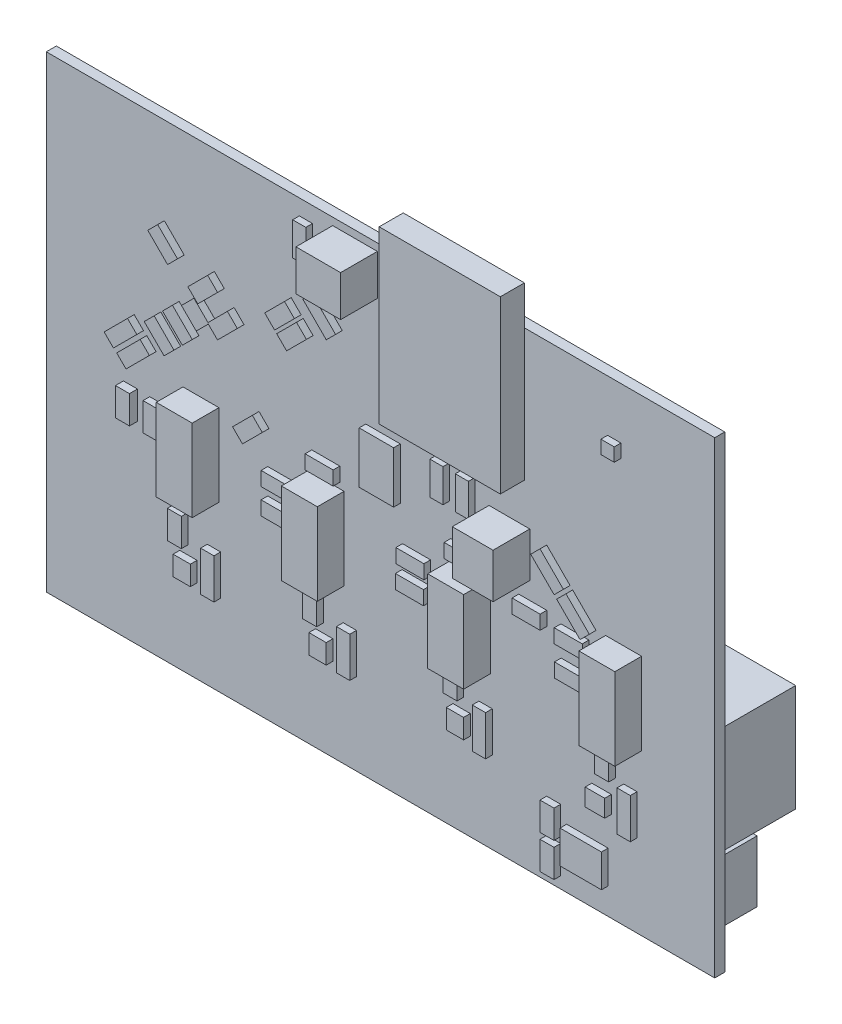
SolidWorks part; units mm, degrees
ref_plane "Front Plane" through (0, 0, 0) normal (0, 0, 1) x (1, 0, 0)
ref_plane "Top Plane" through (0, 0, 0) normal (0, 1, 0) x (1, 0, 0)
ref_plane "Right Plane" through (0, 0, 0) normal (1, 0, 0) x (0, 0, -1)
sketch "Sketch1" plane through (0, 0, 0) normal (0, 0, 1) x (1, 0, 0)
  line L0 (-0.0006, 0) -> (99.9994, 0)
  line L1 (99.9994, 0) -> (99.9994, 70)
  line L2 (99.9994, 70) -> (-0.0006, 70)
  line L3 (-0.0006, 70) -> (-0.0006, 0)
extrude "BOARD" add sketch "Sketch1" along normal blind 1.5 separate body
ref_plane "Plane1" through (0, 0, 1.5) normal (0, 0, 1) x (1, 0, 0)
sketch "Sketch2" plane through (0, 0, 0) normal (0, 0, 1) x (1, 0, 0)
  line L0 (84.8503, 10.084) -> (94.8323, 10.084)
  line L1 (94.8323, 10.084) -> (94.8323, 0.889)
  line L2 (94.8323, 0.889) -> (84.8503, 0.889)
  line L3 (84.8503, 0.889) -> (84.8503, 10.084)
extrude "W237-102-1" add sketch "Sketch2" against normal blind 10 separate body
sketch "Sketch3" plane through (0, 0, 1.5) normal (0, 0, 1) x (1, 0, 0)
  line L0 (19.8709, 47.5966) -> (22.8344, 44.6331)
  line L1 (22.8344, 44.6331) -> (21.3526, 43.1514)
  line L2 (21.3526, 43.1514) -> (18.3892, 46.1149)
  line L3 (18.3892, 46.1149) -> (19.8709, 47.5966)
extrude "C1206FAB-1" add sketch "Sketch3" along normal blind 1 separate body
sketch "Sketch4" plane through (0, 0, 1.5) normal (0, 0, 1) x (1, 0, 0)
  line L0 (18.6137, 40.4124) -> (15.6502, 43.3759)
  line L1 (15.6502, 43.3759) -> (17.1319, 44.8576)
  line L2 (17.1319, 44.8576) -> (20.0954, 41.8942)
  line L3 (20.0954, 41.8942) -> (18.6137, 40.4124)
extrude "C1206FAB-2" add sketch "Sketch4" along normal blind 1 separate body
sketch "Sketch5" plane through (0, 0, 1.5) normal (0, 0, 1) x (1, 0, 0)
  line L0 (76.9488, 10.9855) -> (76.9488, 6.7945)
  line L1 (76.9488, 6.7945) -> (74.8533, 6.7945)
  line L2 (74.8533, 6.7945) -> (74.8533, 10.9855)
  line L3 (74.8533, 10.9855) -> (76.9488, 10.9855)
extrude "C1206FAB-3" add sketch "Sketch5" along normal blind 1 separate body
sketch "Sketch6" plane through (0, 0, 1.5) normal (0, 0, 1) x (1, 0, 0)
  line L0 (76.9488, 5.9055) -> (76.9488, 1.7145)
  line L1 (76.9488, 1.7145) -> (74.8533, 1.7145)
  line L2 (74.8533, 1.7145) -> (74.8533, 5.9055)
  line L3 (74.8533, 5.9055) -> (76.9488, 5.9055)
extrude "C1206FAB-4" add sketch "Sketch6" along normal blind 1 separate body
sketch "Sketch7" plane through (0, 0, 1.5) normal (0, 0, 1) x (1, 0, 0)
  line L0 (33.671, 53.5037) -> (36.6345, 56.4672)
  line L1 (36.6345, 56.4672) -> (38.1162, 54.9854)
  line L2 (38.1162, 54.9854) -> (35.1527, 52.022)
  line L3 (35.1527, 52.022) -> (33.671, 53.5037)
extrude "C1206FAB-5" add sketch "Sketch7" along normal blind 1 separate body
sketch "Sketch8" plane through (0, 0, 1.5) normal (0, 0, 1) x (1, 0, 0)
  line L0 (35.4671, 51.7076) -> (38.4305, 54.6711)
  line L1 (38.4305, 54.6711) -> (39.9123, 53.1894)
  line L2 (39.9123, 53.1894) -> (36.9488, 50.2259)
  line L3 (36.9488, 50.2259) -> (35.4671, 51.7076)
extrude "C1206FAB-6" add sketch "Sketch8" along normal blind 1 separate body
sketch "Sketch9" plane through (0, 0, 1.5) normal (0, 0, 1) x (1, 0, 0)
  line L0 (88.3684, 18.323) -> (88.3684, 12.3262)
  line L1 (88.3684, 12.3262) -> (86.377, 12.3262)
  line L2 (86.377, 12.3262) -> (86.377, 18.323)
  line L3 (86.377, 18.323) -> (88.3684, 18.323)
extrude "SOD123-1" add sketch "Sketch9" along normal blind 1 separate body
sketch "Sketch10" plane through (0, 0, 1.5) normal (0, 0, 1) x (1, 0, 0)
  line L0 (26.0778, 18.2384) -> (26.0777, 12.2416)
  line L1 (26.0777, 12.2416) -> (24.0863, 12.2416)
  line L2 (24.0863, 12.2416) -> (24.0863, 18.2384)
  line L3 (24.0863, 18.2384) -> (26.0778, 18.2384)
extrude "SOD123-2" add sketch "Sketch10" along normal blind 1 separate body
sketch "Sketch11" plane through (0, 0, 1.5) normal (0, 0, 1) x (1, 0, 0)
  line L0 (46.3978, 18.2384) -> (46.3978, 12.2416)
  line L1 (46.3978, 12.2416) -> (44.4064, 12.2416)
  line L2 (44.4064, 12.2416) -> (44.4064, 18.2384)
  line L3 (44.4064, 18.2384) -> (46.3978, 18.2384)
extrude "SOD123-3" add sketch "Sketch11" along normal blind 1 separate body
sketch "Sketch12" plane through (0, 0, 1.5) normal (0, 0, 1) x (1, 0, 0)
  line L0 (66.7177, 18.2384) -> (66.7177, 12.2416)
  line L1 (66.7177, 12.2416) -> (64.7263, 12.2416)
  line L2 (64.7263, 12.2416) -> (64.7263, 18.2384)
  line L3 (64.7263, 18.2384) -> (66.7177, 18.2384)
extrude "SOD123-4" add sketch "Sketch12" along normal blind 1 separate body
sketch "Sketch13" plane through (0, 0, 1.5) normal (0, 0, 1) x (1, 0, 0)
  line L0 (77.8494, 3.95) -> (77.8494, 8.8516)
  line L1 (77.8494, 8.8516) -> (84.0493, 8.8516)
  line L2 (84.0493, 8.8516) -> (84.0493, 3.95)
  line L3 (84.0493, 3.95) -> (77.8494, 3.95)
extrude "SO08-1" add sketch "Sketch13" along normal blind 1 separate body
sketch "Sketch14" plane through (0, 0, 0) normal (0, 0, 1) x (1, 0, 0)
  line L0 (78.4783, 50.3609) -> (78.4783, 42.6647)
  line L1 (78.4783, 42.6647) -> (83.6345, 42.6647)
  line L2 (83.6345, 42.6647) -> (83.6345, 50.3609)
  line L3 (83.6345, 50.3609) -> (78.4783, 50.3609)
extrude "2X03-1" add sketch "Sketch14" against normal blind 8.5 separate body
sketch "Sketch15" plane through (0, 0, 1.5) normal (0, 0, 1) x (1, 0, 0)
  line L0 (47.8001, 37.9798) -> (47.8001, 45.676)
  line L1 (47.8001, 45.676) -> (52.9563, 45.676)
  line L2 (52.9563, 45.676) -> (52.9563, 37.9798)
  line L3 (52.9563, 37.9798) -> (47.8001, 37.9798)
extrude "2X03-2" add sketch "Sketch15" along normal blind 1 separate body
sketch "Sketch16" plane through (0, 0, 0) normal (0, 0, 1) x (1, 0, 0)
  line L0 (31.7093, 27.05) -> (11.4594, 27.05)
  line L1 (11.4594, 27.05) -> (11.4594, 11.05)
  line L2 (11.4594, 11.05) -> (31.7093, 11.05)
  line L3 (31.7093, 11.05) -> (31.7093, 27.05)
extrude "RELAY_SRD-05VDC-SL-C-1" add sketch "Sketch16" against normal blind 15.3928 separate body
sketch "Sketch17" plane through (0, 0, 0) normal (0, 0, 1) x (1, 0, 0)
  line L0 (95.2094, 27.05) -> (74.9594, 27.05)
  line L1 (74.9594, 27.05) -> (74.9594, 11.05)
  line L2 (74.9594, 11.05) -> (95.2094, 11.05)
  line L3 (95.2094, 11.05) -> (95.2094, 27.05)
extrude "RELAY_SRD-05VDC-SL-C-2" add sketch "Sketch17" against normal blind 15.4 separate body
sketch "Sketch18" plane through (0, 0, 0) normal (0, 0, 1) x (1, 0, 0)
  line L0 (52.0293, 27.05) -> (31.7793, 27.05)
  line L1 (31.7793, 27.05) -> (31.7793, 11.05)
  line L2 (31.7793, 11.05) -> (52.0293, 11.05)
  line L3 (52.0293, 11.05) -> (52.0293, 27.05)
extrude "RELAY_SRD-05VDC-SL-C-3" add sketch "Sketch18" against normal up to surface (15.4 mm away) separate body up to face at (85.0844, 19.05, -15.4)
sketch "Sketch19" plane through (0, 0, 0) normal (0, 0, 1) x (1, 0, 0)
  line L0 (72.3494, 27.05) -> (52.0994, 27.05)
  line L1 (52.0994, 27.05) -> (52.0994, 11.05)
  line L2 (52.0994, 11.05) -> (72.3494, 11.05)
  line L3 (72.3494, 11.05) -> (72.3494, 27.05)
extrude "RELAY_SRD-05VDC-SL-C-4" add sketch "Sketch19" against normal up to surface (15.4 mm away) separate body up to face at (85.0844, 19.05, -15.4)
sketch "Sketch20" plane through (0, 0, 0) normal (0, 0, 1) x (1, 0, 0)
  line L0 (31.3382, 40.7304) -> (35.1099, 44.5022)
  line L1 (35.1099, 44.5022) -> (30.5299, 49.0821)
  line L2 (30.5299, 49.0821) -> (26.7582, 45.3104)
  line L3 (26.7582, 45.3104) -> (31.3382, 40.7304)
extrude "22-23-2021-1" add sketch "Sketch20" against normal blind 12 separate body
sketch "Sketch21" plane through (0, 0, 1.5) normal (0, 0, 1) x (1, 0, 0)
  line L0 (84.5347, 13.4608) -> (81.6137, 13.4608)
  line L1 (81.6137, 13.4608) -> (81.6137, 16.0516)
  line L2 (81.6137, 16.0516) -> (84.5347, 16.0516)
  line L3 (84.5347, 16.0516) -> (84.5347, 13.4608)
extrude "SOT23-1" add sketch "Sketch21" along normal blind 1 separate body
sketch "Sketch22" plane through (0, 0, 1.5) normal (0, 0, 1) x (1, 0, 0)
  line L0 (22.5548, 15.3924) -> (22.5548, 12.4714)
  line L1 (22.5548, 12.4714) -> (19.964, 12.4714)
  line L2 (19.964, 12.4714) -> (19.964, 15.3924)
  line L3 (19.964, 15.3924) -> (22.5548, 15.3924)
extrude "SOT23-2" add sketch "Sketch22" along normal blind 1 separate body
sketch "Sketch23" plane through (0, 0, 1.5) normal (0, 0, 1) x (1, 0, 0)
  line L0 (42.8747, 15.3924) -> (42.8747, 12.4714)
  line L1 (42.8747, 12.4714) -> (40.2839, 12.4714)
  line L2 (40.2839, 12.4714) -> (40.2839, 15.3924)
  line L3 (40.2839, 15.3924) -> (42.8747, 15.3924)
extrude "SOT23-3" add sketch "Sketch23" along normal blind 1 separate body
sketch "Sketch24" plane through (0, 0, 1.5) normal (0, 0, 1) x (1, 0, 0)
  line L0 (63.4265, 15.9752) -> (63.4265, 13.0542)
  line L1 (63.4265, 13.0542) -> (60.8357, 13.0542)
  line L2 (60.8357, 13.0542) -> (60.8357, 15.9752)
  line L3 (60.8357, 15.9752) -> (63.4265, 15.9752)
extrude "SOT23-4" add sketch "Sketch24" along normal blind 1 separate body
sketch "Sketch25" plane through (0, 0, 1.5) normal (0, 0, 1) x (1, 0, 0)
  line L0 (85.1422, 22.6559) -> (85.1422, 18.4649)
  line L1 (85.1422, 18.4649) -> (83.0467, 18.4649)
  line L2 (83.0467, 18.4649) -> (83.0467, 22.6559)
  line L3 (83.0467, 22.6559) -> (85.1422, 22.6559)
extrude "R1206FAB-1" add sketch "Sketch25" along normal blind 1 separate body
sketch "Sketch26" plane through (0, 0, 1.5) normal (0, 0, 1) x (1, 0, 0)
  line L0 (21.2024, 20.9114) -> (21.2024, 16.7204)
  line L1 (21.2024, 16.7204) -> (19.1069, 16.7204)
  line L2 (19.1069, 16.7204) -> (19.1069, 20.9114)
  line L3 (19.1069, 20.9114) -> (21.2024, 20.9114)
extrude "R1206FAB-2" add sketch "Sketch26" along normal blind 1 separate body
sketch "Sketch27" plane through (0, 0, 1.5) normal (0, 0, 1) x (1, 0, 0)
  line L0 (15.4713, 28.8569) -> (15.4713, 33.0479)
  line L1 (15.4713, 33.0479) -> (17.5668, 33.0479)
  line L2 (17.5668, 33.0479) -> (17.5668, 28.8569)
  line L3 (17.5668, 28.8569) -> (15.4713, 28.8569)
extrude "R1206FAB-3" add sketch "Sketch27" along normal blind 1 separate body
sketch "Sketch28" plane through (0, 0, 1.5) normal (0, 0, 1) x (1, 0, 0)
  line L0 (41.4355, 20.9102) -> (41.4355, 16.7192)
  line L1 (41.4355, 16.7192) -> (39.34, 16.7192)
  line L2 (39.34, 16.7192) -> (39.34, 20.9102)
  line L3 (39.34, 20.9102) -> (41.4355, 20.9102)
extrude "R1206FAB-4" add sketch "Sketch28" along normal blind 1 separate body
sketch "Sketch29" plane through (0, 0, 1.5) normal (0, 0, 1) x (1, 0, 0)
  line L0 (62.4484, 21.8076) -> (62.4484, 17.6166)
  line L1 (62.4484, 17.6166) -> (60.3529, 17.6166)
  line L2 (60.3529, 17.6166) -> (60.3529, 21.8076)
  line L3 (60.3529, 21.8076) -> (62.4484, 21.8076)
extrude "R1206FAB-5" add sketch "Sketch29" along normal blind 1 separate body
sketch "Sketch30" plane through (0, 0, 1.5) normal (0, 0, 1) x (1, 0, 0)
  line L0 (53.2265, 29.5255) -> (57.4175, 29.5255)
  line L1 (57.4175, 29.5255) -> (57.4175, 27.43)
  line L2 (57.4175, 27.43) -> (53.2265, 27.43)
  line L3 (53.2265, 27.43) -> (53.2265, 29.5255)
extrude "R1206FAB-6" add sketch "Sketch30" along normal blind 1 separate body
sketch "Sketch31" plane through (0, 0, 1.5) normal (0, 0, 1) x (1, 0, 0)
  line L0 (29.5748, 49.4345) -> (26.6113, 46.471)
  line L1 (26.6113, 46.471) -> (25.1295, 47.9528)
  line L2 (25.1295, 47.9528) -> (28.093, 50.9163)
  line L3 (28.093, 50.9163) -> (29.5748, 49.4345)
extrude "R1206FAB-7" add sketch "Sketch31" along normal blind 1 separate body
sketch "Sketch32" plane through (0, 0, 1.5) normal (0, 0, 1) x (1, 0, 0)
  line L0 (33.1338, 29.0195) -> (37.3248, 29.0195)
  line L1 (37.3248, 29.0195) -> (37.3248, 26.924)
  line L2 (37.3248, 26.924) -> (33.1338, 26.924)
  line L3 (33.1338, 26.924) -> (33.1338, 29.0195)
extrude "R1206FAB-8" add sketch "Sketch32" along normal blind 1 separate body
sketch "Sketch33" plane through (0, 0, 1.5) normal (0, 0, 1) x (1, 0, 0)
  line L0 (22.1772, 51.1496) -> (25.1407, 54.1131)
  line L1 (25.1407, 54.1131) -> (26.6224, 52.6313)
  line L2 (26.6224, 52.6313) -> (23.6589, 49.6678)
  line L3 (23.6589, 49.6678) -> (22.1772, 51.1496)
extrude "R1206FAB-9" add sketch "Sketch33" along normal blind 1 separate body
sketch "Sketch34" plane through (0, 0, 1.5) normal (0, 0, 1) x (1, 0, 0)
  line L0 (19.144, 52.5026) -> (16.1805, 55.4661)
  line L1 (16.1805, 55.4661) -> (17.6622, 56.9479)
  line L2 (17.6622, 56.9479) -> (20.6257, 53.9844)
  line L3 (20.6257, 53.9844) -> (19.144, 52.5026)
extrude "R1206FAB-10" add sketch "Sketch34" along normal blind 1 separate body
sketch "Sketch35" plane through (0, 0, 1.5) normal (0, 0, 1) x (1, 0, 0)
  line L0 (77.0151, 29.9613) -> (81.2061, 29.9613)
  line L1 (81.2061, 29.9613) -> (81.2061, 27.8658)
  line L2 (81.2061, 27.8658) -> (77.0151, 27.8658)
  line L3 (77.0151, 27.8658) -> (77.0151, 29.9613)
extrude "R1206FAB-11" add sketch "Sketch35" along normal blind 1 separate body
sketch "Sketch36" plane through (0, 0, 1.5) normal (0, 0, 1) x (1, 0, 0)
  line L0 (39.8191, 67.6651) -> (39.8191, 62.7191)
  line L1 (39.8191, 62.7191) -> (37.8531, 62.7191)
  line L2 (37.8531, 62.7191) -> (37.8531, 67.6651)
  line L3 (37.8531, 67.6651) -> (39.8191, 67.6651)
extrude "R1206-1" add sketch "Sketch36" along normal blind 1 separate body
sketch "Sketch37" plane through (0, 0, 1.5) normal (0, 0, 1) x (1, 0, 0)
  line L0 (11.5317, 37.2524) -> (15.0291, 40.7497)
  line L1 (15.0291, 40.7497) -> (16.4192, 39.3596)
  line L2 (16.4192, 39.3596) -> (12.9219, 35.8622)
  line L3 (12.9219, 35.8622) -> (11.5317, 37.2524)
extrude "R1206-2" add sketch "Sketch37" along normal blind 1 separate body
sketch "Sketch38" plane through (0, 0, 1.5) normal (0, 0, 1) x (1, 0, 0)
  line L0 (62.1864, 41.977) -> (62.1864, 46.923)
  line L1 (62.1864, 46.923) -> (64.1523, 46.923)
  line L2 (64.1523, 46.923) -> (64.1523, 41.977)
  line L3 (64.1523, 41.977) -> (62.1864, 41.977)
extrude "R1206-3" add sketch "Sketch38" along normal blind 1 separate body
sketch "Sketch39" plane through (0, 0, 1.5) normal (0, 0, 1) x (1, 0, 0)
  line L0 (40.7767, 59.514) -> (44.274, 56.0167)
  line L1 (44.274, 56.0167) -> (42.8839, 54.6265)
  line L2 (42.8839, 54.6265) -> (39.3865, 58.1239)
  line L3 (39.3865, 58.1239) -> (40.7767, 59.514)
extrude "R1206-4" add sketch "Sketch39" along normal blind 1 separate body
sketch "Sketch40" plane through (0, 0, 1.5) normal (0, 0, 1) x (1, 0, 0)
  line L0 (76.9672, 38.6421) -> (73.4699, 42.1394)
  line L1 (73.4699, 42.1394) -> (74.8601, 43.5296)
  line L2 (74.8601, 43.5296) -> (78.3574, 40.0322)
  line L3 (78.3574, 40.0322) -> (76.9672, 38.6421)
extrude "R1206-5" add sketch "Sketch40" along normal blind 1 separate body
sketch "Sketch41" plane through (0, 0, 1.5) normal (0, 0, 1) x (1, 0, 0)
  line L0 (70.6782, 35.0758) -> (74.8692, 35.0758)
  line L1 (74.8692, 35.0758) -> (74.8692, 32.9803)
  line L2 (74.8692, 32.9803) -> (70.6782, 32.9803)
  line L3 (70.6782, 32.9803) -> (70.6782, 35.0758)
extrude "R1206FAB-12" add sketch "Sketch41" along normal blind 1 separate body
sketch "Sketch42" plane through (0, 0, 1.5) normal (0, 0, 1) x (1, 0, 0)
  line L0 (33.3079, 37.8301) -> (30.3444, 34.8666)
  line L1 (30.3444, 34.8666) -> (28.8627, 36.3484)
  line L2 (28.8627, 36.3484) -> (31.8262, 39.3118)
  line L3 (31.8262, 39.3118) -> (33.3079, 37.8301)
extrude "R1206FAB-13" add sketch "Sketch42" along normal blind 1 separate body
sketch "Sketch43" plane through (0, 0, 1.5) normal (0, 0, 1) x (1, 0, 0)
  line L0 (39.7177, 38.2765) -> (43.9087, 38.2765)
  line L1 (43.9087, 38.2765) -> (43.9087, 36.181)
  line L2 (43.9087, 36.181) -> (39.7177, 36.181)
  line L3 (39.7177, 36.181) -> (39.7177, 38.2765)
extrude "R1206FAB-14" add sketch "Sketch43" along normal blind 1 separate body
sketch "Sketch44" plane through (0, 0, 1.5) normal (0, 0, 1) x (1, 0, 0)
  line L0 (60.5134, 37.1906) -> (64.7044, 37.1906)
  line L1 (64.7044, 37.1906) -> (64.7044, 35.0951)
  line L2 (64.7044, 35.0951) -> (60.5134, 35.0951)
  line L3 (60.5134, 35.0951) -> (60.5134, 37.1906)
extrude "R1206FAB-15" add sketch "Sketch44" along normal blind 1 separate body
sketch "Sketch45" plane through (0, 0, 1.5) normal (0, 0, 1) x (1, 0, 0)
  line L0 (85.9632, 60.2956) -> (83.9632, 60.2956)
  line L1 (83.9632, 60.2956) -> (83.9632, 62.2956)
  line L2 (83.9632, 62.2956) -> (85.9632, 62.2956)
  line L3 (85.9632, 62.2956) -> (85.9632, 60.2956)
extrude "1X06SMD-1" add sketch "Sketch45" along normal blind 1 separate body
sketch "Sketch46" plane through (0, 0, 1.5) normal (0, 0, 1) x (1, 0, 0)
  line L0 (49.5256, 62.807) -> (42.8454, 62.807)
  line L1 (42.8454, 62.807) -> (42.8454, 68.903)
  line L2 (42.8454, 68.903) -> (49.5256, 68.903)
  line L3 (49.5256, 68.903) -> (49.5256, 62.807)
extrude "6MM_SWITCH-1" add sketch "Sketch46" along normal blind 5.5 separate body
sketch "Sketch47" plane through (0, 0, 1.5) normal (0, 0, 1) x (1, 0, 0)
  line L0 (72.3286, 44.3408) -> (72.3286, 37.6606)
  line L1 (72.3286, 37.6606) -> (66.2326, 37.6606)
  line L2 (66.2326, 37.6606) -> (66.2326, 44.3408)
  line L3 (66.2326, 44.3408) -> (72.3286, 44.3408)
extrude "6MM_SWITCH-2" add sketch "Sketch47" along normal blind 5.5 separate body
sketch "Sketch48" plane through (0, 0, 1.5) normal (0, 0, 1) x (1, 0, 0)
  line L0 (53.2947, 32.9182) -> (57.4857, 32.9182)
  line L1 (57.4857, 32.9182) -> (57.4857, 30.8227)
  line L2 (57.4857, 30.8227) -> (53.2947, 30.8227)
  line L3 (53.2947, 30.8227) -> (53.2947, 32.9182)
extrude "LED1206FAB-1" add sketch "Sketch48" along normal blind 1 separate body
sketch "Sketch49" plane through (0, 0, 1.5) normal (0, 0, 1) x (1, 0, 0)
  line L0 (21.2179, 48.2432) -> (23.0858, 50.1111)
  line L1 (23.0858, 50.1111) -> (25.295, 47.902)
  line L2 (25.295, 47.902) -> (23.4271, 46.0341)
  line L3 (23.4271, 46.0341) -> (21.2179, 48.2432)
extrude "SOT95P237X112-3N-1" add sketch "Sketch49" along normal blind 1 separate body
sketch "Sketch50" plane through (0, 0, 1.5) normal (0, 0, 1) x (1, 0, 0)
  line L0 (11.5419, 28.9365) -> (11.5419, 33.1275)
  line L1 (11.5419, 33.1275) -> (13.6374, 33.1275)
  line L2 (13.6374, 33.1275) -> (13.6374, 28.9365)
  line L3 (13.6374, 28.9365) -> (11.5419, 28.9365)
extrude "LED1206FAB-2" add sketch "Sketch50" along normal blind 1.1952 separate body
sketch "Sketch51" plane through (0, 0, 1.5) normal (0, 0, 1) x (1, 0, 0)
  line L0 (33.1338, 32.8295) -> (37.3248, 32.8295)
  line L1 (37.3248, 32.8295) -> (37.3248, 30.734)
  line L2 (37.3248, 30.734) -> (33.1338, 30.734)
  line L3 (33.1338, 30.734) -> (33.1338, 32.8295)
extrude "LED1206FAB-3" add sketch "Sketch51" along normal blind 1 separate body
sketch "Sketch52" plane through (0, 0, 1.5) normal (0, 0, 1) x (1, 0, 0)
  line L0 (76.987, 34.3751) -> (81.178, 34.3751)
  line L1 (81.178, 34.3751) -> (81.178, 32.2796)
  line L2 (81.178, 32.2796) -> (76.987, 32.2796)
  line L3 (76.987, 32.2796) -> (76.987, 34.3751)
extrude "LED1206FAB-4" add sketch "Sketch52" along normal blind 1 separate body
sketch "Sketch53" plane through (0, 0, 0) normal (0, 0, 1) x (1, 0, 0)
  line L0 (12.5234, 54.636) -> (3.4534, 45.5659)
  line L1 (3.4534, 45.5659) -> (7.8088, 41.2105)
  line L2 (7.8088, 41.2105) -> (16.8789, 50.2806)
  line L3 (16.8789, 50.2806) -> (12.5234, 54.636)
extrude "TEMP-HUM-SENSOR-DHT11-1" add sketch "Sketch53" against normal blind 6.9525 separate body
sketch "Sketch54" plane through (0, 0, 1.5) normal (0, 0, 1) x (1, 0, 0)
  line L0 (78.7403, 39.6485) -> (82.2376, 36.1511)
  line L1 (82.2376, 36.1511) -> (80.8474, 34.7609)
  line L2 (80.8474, 34.7609) -> (77.3501, 38.2583)
  line L3 (77.3501, 38.2583) -> (78.7403, 39.6485)
extrude "LED1206-1" add sketch "Sketch54" along normal blind 1 separate body
sketch "Sketch55" plane through (0, 0, 1.5) normal (0, 0, 1) x (1, 0, 0)
  line L0 (9.6506, 39.0312) -> (13.148, 42.5285)
  line L1 (13.148, 42.5285) -> (14.5381, 41.1384)
  line L2 (14.5381, 41.1384) -> (11.0408, 37.641)
  line L3 (11.0408, 37.641) -> (9.6506, 39.0312)
extrude "LED1206-2" add sketch "Sketch55" along normal blind 1 separate body
sketch "Sketch56" plane through (0, 0, 1.5) normal (0, 0, 1) x (1, 0, 0)
  line L0 (58.3764, 41.977) -> (58.3764, 46.923)
  line L1 (58.3764, 46.923) -> (60.3423, 46.923)
  line L2 (60.3423, 46.923) -> (60.3423, 41.977)
  line L3 (60.3423, 41.977) -> (58.3764, 41.977)
extrude "LED1206-3" add sketch "Sketch56" along normal blind 1 separate body
sketch "Sketch57" plane through (0, 0, 1.5) normal (0, 0, 1) x (1, 0, 0)
  line L0 (53.397, 75.8254) -> (71.524, 75.8254)
  line L1 (71.524, 75.8254) -> (71.524, 50.2619)
  line L2 (71.524, 50.2619) -> (53.397, 50.2619)
  line L3 (53.397, 50.2619) -> (53.397, 75.8254)
extrude "ESP-WROOM-32-1" add sketch "Sketch57" along normal blind 3.6 separate body
sketch "Sketch58" plane through (0, 0, 1.5) normal (0, 0, 1) x (1, 0, 0)
  line L0 (89.0524, 36.2134) -> (89.0524, 23.9534)
  line L1 (89.0524, 23.9534) -> (83.6724, 23.9534)
  line L2 (83.6724, 23.9534) -> (83.6724, 36.2134)
  line L3 (83.6724, 36.2134) -> (89.0524, 36.2134)
extrude "SOIC254P1030X460-4N-1" add sketch "Sketch58" along normal blind 4 separate body
sketch "Sketch59" plane through (0, 0, 1.5) normal (0, 0, 1) x (1, 0, 0)
  line L0 (25.8254, 36.8061) -> (25.8254, 24.5461)
  line L1 (25.8254, 24.5461) -> (20.4454, 24.5461)
  line L2 (20.4454, 24.5461) -> (20.4454, 36.8061)
  line L3 (20.4454, 36.8061) -> (25.8254, 36.8061)
extrude "SOIC254P1030X460-4N-2" add sketch "Sketch59" along normal blind 4 separate body
sketch "Sketch60" plane through (0, 0, 1.5) normal (0, 0, 1) x (1, 0, 0)
  line L0 (44.5422, 35.328) -> (44.5422, 23.068)
  line L1 (44.5422, 23.068) -> (39.1622, 23.068)
  line L2 (39.1622, 23.068) -> (39.1622, 35.328)
  line L3 (39.1622, 35.328) -> (44.5422, 35.328)
extrude "SOIC254P1030X460-4N-3" add sketch "Sketch60" along normal blind 4 separate body
sketch "Sketch61" plane through (0, 0, 1.5) normal (0, 0, 1) x (1, 0, 0)
  line L0 (66.437, 34.896) -> (66.437, 22.636)
  line L1 (66.437, 22.636) -> (61.057, 22.636)
  line L2 (61.057, 22.636) -> (61.057, 34.896)
  line L3 (61.057, 34.896) -> (66.437, 34.896)
extrude "SOIC254P1030X460-4N-4" add sketch "Sketch61" along normal blind 4 separate body
sketch "Sketch62" plane through (0, 0, 0) normal (0, 0, 1) x (1, 0, 0)
  line L0 (21.3503, 10.084) -> (31.3323, 10.084)
  line L1 (31.3323, 10.084) -> (31.3323, 0.889)
  line L2 (31.3323, 0.889) -> (21.3503, 0.889)
  line L3 (21.3503, 0.889) -> (21.3503, 10.084)
extrude "W237-102-2" add sketch "Sketch62" against normal blind 10 separate body
sketch "Sketch63" plane through (0, 0, 0) normal (0, 0, 1) x (1, 0, 0)
  line L0 (41.6704, 10.084) -> (51.6524, 10.084)
  line L1 (51.6524, 10.084) -> (51.6524, 0.889)
  line L2 (51.6524, 0.889) -> (41.6704, 0.889)
  line L3 (41.6704, 0.889) -> (41.6704, 10.084)
extrude "W237-102-3" add sketch "Sketch63" along normal blind 1 and the other way blind 10 separate body
sketch "Sketch64" plane through (0, 0, 0) normal (0, 0, 1) x (1, 0, 0)
  line L0 (61.9903, 10.084) -> (71.9723, 10.084)
  line L1 (71.9723, 10.084) -> (71.9723, 0.889)
  line L2 (71.9723, 0.889) -> (61.9903, 0.889)
  line L3 (61.9903, 0.889) -> (61.9903, 10.084)
extrude "W237-102-4" add sketch "Sketch64" along normal blind 1 and the other way blind 10 separate body
sketch "Sketch65" plane through (0, 0, 0) normal (0, 0, 1) x (1, 0, 0)
  line L0 (42.28, 55.6462) -> (40.4062, 57.52)
  line L1 (40.4062, 57.52) -> (38.5324, 55.6462)
  line L2 (38.5324, 55.6462) -> (40.4062, 53.7724)
  line L3 (40.4062, 53.7724) -> (42.28, 55.6462)
extrude "XTAL_ECS-_327-12_5-13X-1" add sketch "Sketch65" against normal blind 6.5 separate body
sketch "Sketch66" plane through (0, 0, 1.5) normal (0, 0, 1) x (1, 0, 0)
  line L0 (-0.0007, 0) -> (99.9994, 0)
  line L1 (99.9994, 0) -> (99.9994, 70)
  line L2 (99.9994, 70) -> (-0.0007, 70)
  line L3 (-0.0007, 70) -> (-0.0007, 0)
  line L4 (86.3484, 4.064) -> (88.3554, 6.071)
  line L5 (91.3274, 4.089) -> (93.3084, 6.096)
  line L6 (84.8504, 0.889) -> (94.8324, 0.889)
  line L7 (94.8324, 10.084) -> (94.8324, 9.881)
  line L8 (94.8324, 10.084) -> (84.8504, 10.084)
  line L9 (84.8504, 0.889) -> (84.8504, 3.277)
  line L10 (84.8504, 3.277) -> (86.4504, 3.277)
  line L11 (86.4504, 3.277) -> (88.2284, 3.277)
  line L12 (88.2284, 3.277) -> (91.4544, 3.277)
  line L13 (93.2324, 3.277) -> (94.8324, 3.277)
  line L14 (84.8504, 3.277) -> (84.8504, 9.881)
  line L15 (94.8324, 3.277) -> (94.8324, 0.889)
  line L16 (84.8504, 9.881) -> (94.8324, 9.881)
  line L17 (84.8504, 9.881) -> (84.8504, 10.084)
  line L18 (94.8324, 9.881) -> (94.8324, 3.277)
  line L19 (91.4544, 3.277) -> (93.2324, 3.277)
  line L20 (85.3709, 7.9375) -> (85.6883, 8.1915)
  line L21 (85.6883, 8.1915) -> (85.6883, 7.0485)
  line L22 (85.3709, 7.0485) -> (86.0059, 7.0485)
  line L23 (90.8636, 7.6835) -> (90.3239, 7.0485)
  line L24 (90.3239, 7.0485) -> (90.9588, 7.0485)
  line L25 (87.3394, 4.0831) -> (87.3394, 6.077)
  line L26 (92.3394, 4.0831) -> (92.3394, 6.077)
  line L27 (19.8709, 47.5068) -> (22.7446, 44.6331)
  line L28 (22.7446, 44.6331) -> (21.3077, 43.1963)
  line L29 (21.3077, 43.1963) -> (18.4341, 46.07)
  line L30 (18.4341, 46.07) -> (19.8709, 47.5068)
  line L31 (18.6137, 40.5022) -> (15.74, 43.3759)
  line L32 (15.74, 43.3759) -> (17.1768, 44.8127)
  line L33 (17.1768, 44.8127) -> (20.0505, 41.9391)
  line L34 (20.0505, 41.9391) -> (18.6137, 40.5022)
  line L35 (76.8854, 10.922) -> (76.8854, 6.858)
  line L36 (76.8854, 6.858) -> (74.8534, 6.858)
  line L37 (74.8534, 6.858) -> (74.8534, 10.922)
  line L38 (74.8534, 10.922) -> (76.8854, 10.922)
  line L39 (76.8854, 5.842) -> (76.8854, 1.778)
  line L40 (76.8854, 1.778) -> (74.8534, 1.778)
  line L41 (74.8534, 1.778) -> (74.8534, 5.842)
  line L42 (74.8534, 5.842) -> (76.8854, 5.842)
  line L43 (33.7608, 53.5037) -> (36.6345, 56.3774)
  line L44 (36.6345, 56.3774) -> (38.0713, 54.9405)
  line L45 (38.0713, 54.9405) -> (35.1976, 52.0669)
  line L46 (35.1976, 52.0669) -> (33.7608, 53.5037)
  line L47 (35.5569, 51.7076) -> (38.4305, 54.5813)
  line L48 (38.4305, 54.5813) -> (39.8674, 53.1445)
  line L49 (39.8674, 53.1445) -> (36.9937, 50.2708)
  line L50 (36.9937, 50.2708) -> (35.5569, 51.7076)
  line L51 (88.147, 16.6456) -> (88.147, 14.0036)
  line L52 (86.573, 16.6456) -> (86.573, 14.0036)
  line L53 (86.573, 16.6456) -> (88.147, 16.6456)
  line L54 (86.573, 14.0036) -> (88.147, 14.0036)
  line L55 (87.36, 16.3246) -> (87.86, 15.3246)
  line L56 (87.86, 15.3246) -> (86.86, 15.3246)
  line L57 (86.86, 15.3246) -> (87.36, 16.3246)
  line L58 (87.86, 16.3246) -> (87.36, 16.3246)
  line L59 (87.36, 16.3246) -> (86.86, 16.3246)
  line L60 (88.249, 17.9916) -> (86.471, 17.9916)
  line L61 (88.249, 18.2456) -> (86.471, 18.2456)
  line L62 (86.471, 18.2456) -> (86.471, 12.5306)
  line L63 (86.471, 12.5306) -> (88.249, 12.5306)
  line L64 (88.249, 12.5306) -> (88.249, 18.2456)
  line L65 (25.8564, 16.561) -> (25.8564, 13.919)
  line L66 (24.2824, 16.561) -> (24.2824, 13.919)
  line L67 (24.2824, 16.561) -> (25.8564, 16.561)
  line L68 (24.2824, 13.919) -> (25.8564, 13.919)
  line L69 (25.0694, 16.24) -> (25.5694, 15.24)
  line L70 (25.5694, 15.24) -> (24.5694, 15.24)
  line L71 (24.5694, 15.24) -> (25.0694, 16.24)
  line L72 (25.5694, 16.24) -> (25.0694, 16.24)
  line L73 (25.0694, 16.24) -> (24.5694, 16.24)
  line L74 (25.9584, 17.907) -> (24.1804, 17.907)
  line L75 (25.9584, 18.161) -> (24.1804, 18.161)
  line L76 (24.1804, 18.161) -> (24.1804, 12.446)
  line L77 (24.1804, 12.446) -> (25.9584, 12.446)
  line L78 (25.9584, 12.446) -> (25.9584, 18.161)
  line L79 (46.1763, 16.561) -> (46.1763, 13.919)
  line L80 (44.6024, 16.561) -> (44.6024, 13.919)
  line L81 (44.6024, 16.561) -> (46.1763, 16.561)
  line L82 (44.6024, 13.919) -> (46.1763, 13.919)
  line L83 (45.3894, 16.24) -> (45.8894, 15.24)
  line L84 (45.8894, 15.24) -> (44.8894, 15.24)
  line L85 (44.8894, 15.24) -> (45.3894, 16.24)
  line L86 (45.8894, 16.24) -> (45.3894, 16.24)
  line L87 (45.3894, 16.24) -> (44.8894, 16.24)
  line L88 (46.2784, 17.907) -> (44.5004, 17.907)
  line L89 (46.2784, 18.161) -> (44.5004, 18.161)
  line L90 (44.5004, 18.161) -> (44.5004, 12.446)
  line L91 (44.5004, 12.446) -> (46.2784, 12.446)
  line L92 (46.2784, 12.446) -> (46.2784, 18.161)
  line L93 (66.4964, 16.561) -> (66.4964, 13.919)
  line L94 (64.9224, 16.561) -> (64.9224, 13.919)
  line L95 (64.9224, 16.561) -> (66.4964, 16.561)
  line L96 (64.9224, 13.919) -> (66.4964, 13.919)
  line L97 (65.7094, 16.24) -> (66.2094, 15.24)
  line L98 (66.2094, 15.24) -> (65.2094, 15.24)
  line L99 (65.2094, 15.24) -> (65.7094, 16.24)
  line L100 (66.2094, 16.24) -> (65.7094, 16.24)
  line L101 (65.7094, 16.24) -> (65.2094, 16.24)
  line L102 (66.5983, 17.907) -> (64.8204, 17.907)
  line L103 (66.5983, 18.161) -> (64.8204, 18.161)
  line L104 (64.8204, 18.161) -> (64.8204, 12.446)
  line L105 (64.8204, 12.446) -> (66.5983, 12.446)
  line L106 (66.5983, 12.446) -> (66.5983, 18.161)
  line L107 (79.0494, 8.75) -> (82.3494, 8.75)
  line L108 (82.3494, 8.75) -> (82.8494, 8.75)
  line L109 (82.8494, 8.75) -> (82.8494, 3.95)
  line L110 (82.8494, 3.95) -> (82.3494, 3.95)
  line L111 (82.3494, 3.95) -> (79.0494, 3.95)
  line L112 (79.0494, 3.95) -> (79.0494, 8.75)
  line L113 (82.3494, 8.75) -> (82.3494, 3.95)
  line L114 (82.9233, 50.2847) -> (83.5583, 49.6497)
  line L115 (83.5583, 48.3797) -> (82.9233, 47.7447)
  line L116 (82.9233, 47.7447) -> (83.5583, 47.1097)
  line L117 (83.5583, 45.8397) -> (82.9233, 45.2047)
  line L118 (82.9233, 50.2847) -> (79.1133, 50.2847)
  line L119 (79.1133, 50.2847) -> (78.4783, 49.6497)
  line L120 (78.4783, 49.6497) -> (78.4783, 48.3797)
  line L121 (78.4783, 48.3797) -> (79.1133, 47.7447)
  line L122 (79.1133, 47.7447) -> (78.4783, 47.1097)
  line L123 (78.4783, 47.1097) -> (78.4783, 45.8397)
  line L124 (78.4783, 45.8397) -> (79.1133, 45.2047)
  line L125 (79.1133, 47.7447) -> (82.9233, 47.7447)
  line L126 (79.1133, 45.2047) -> (82.9233, 45.2047)
  line L127 (83.5583, 47.1097) -> (83.5583, 45.8397)
  line L128 (83.5583, 49.6497) -> (83.5583, 48.3797)
  line L129 (82.9233, 45.2047) -> (83.5583, 44.5697)
  line L130 (83.5583, 43.2997) -> (82.9233, 42.6647)
  line L131 (79.1133, 45.2047) -> (78.4783, 44.5697)
  line L132 (78.4783, 44.5697) -> (78.4783, 43.2997)
  line L133 (78.4783, 43.2997) -> (79.1133, 42.6647)
  line L134 (79.1133, 42.6647) -> (82.9233, 42.6647)
  line L135 (83.5583, 44.5697) -> (83.5583, 43.2997)
  line L136 (82.1094, 49.4465) -> (82.4672, 49.4465)
  line L137 (82.4672, 49.4465) -> (82.7201, 49.1936)
  line L138 (82.7201, 49.1936) -> (82.7201, 48.8358)
  line L139 (82.7201, 48.8358) -> (82.4672, 48.5829)
  line L140 (82.4672, 48.5829) -> (82.1094, 48.5829)
  line L141 (82.1094, 48.5829) -> (81.8565, 48.8358)
  line L142 (81.8565, 48.8358) -> (81.8565, 49.1936)
  line L143 (81.8565, 49.1936) -> (82.1094, 49.4465)
  line L144 (82.1094, 49.4465) -> (82.4672, 49.4465)
  line L145 (79.5694, 49.4465) -> (79.9272, 49.4465)
  line L146 (79.9272, 49.4465) -> (80.1801, 49.1936)
  line L147 (80.1801, 49.1936) -> (80.1801, 48.8358)
  line L148 (80.1801, 48.8358) -> (79.9272, 48.5829)
  line L149 (79.9272, 48.5829) -> (79.5694, 48.5829)
  line L150 (79.5694, 48.5829) -> (79.3165, 48.8358)
  line L151 (79.3165, 48.8358) -> (79.3165, 49.1936)
  line L152 (79.3165, 49.1936) -> (79.5694, 49.4465)
  line L153 (79.5694, 49.4465) -> (79.9272, 49.4465)
  line L154 (82.1094, 46.9065) -> (82.4672, 46.9065)
  line L155 (82.4672, 46.9065) -> (82.7201, 46.6536)
  line L156 (82.7201, 46.6536) -> (82.7201, 46.2958)
  line L157 (82.7201, 46.2958) -> (82.4672, 46.0429)
  line L158 (82.4672, 46.0429) -> (82.1094, 46.0429)
  line L159 (82.1094, 46.0429) -> (81.8565, 46.2958)
  line L160 (81.8565, 46.2958) -> (81.8565, 46.6536)
  line L161 (81.8565, 46.6536) -> (82.1094, 46.9065)
  line L162 (82.1094, 46.9065) -> (82.4672, 46.9065)
  line L163 (79.5694, 46.9065) -> (79.9272, 46.9065)
  line L164 (79.9272, 46.9065) -> (80.1801, 46.6536)
  line L165 (80.1801, 46.6536) -> (80.1801, 46.2958)
  line L166 (80.1801, 46.2958) -> (79.9272, 46.0429)
  line L167 (79.9272, 46.0429) -> (79.5694, 46.0429)
  line L168 (79.5694, 46.0429) -> (79.3165, 46.2958)
  line L169 (79.3165, 46.2958) -> (79.3165, 46.6536)
  line L170 (79.3165, 46.6536) -> (79.5694, 46.9065)
  line L171 (79.5694, 46.9065) -> (79.9272, 46.9065)
  line L172 (82.1094, 44.3665) -> (82.4672, 44.3665)
  line L173 (82.4672, 44.3665) -> (82.7201, 44.1136)
  line L174 (82.7201, 44.1136) -> (82.7201, 43.7558)
  line L175 (82.7201, 43.7558) -> (82.4672, 43.5029)
  line L176 (82.4672, 43.5029) -> (82.1094, 43.5029)
  line L177 (82.1094, 43.5029) -> (81.8565, 43.7558)
  line L178 (81.8565, 43.7558) -> (81.8565, 44.1136)
  line L179 (81.8565, 44.1136) -> (82.1094, 44.3665)
  line L180 (82.1094, 44.3665) -> (82.4672, 44.3665)
  line L181 (79.5694, 44.3665) -> (79.9272, 44.3665)
  line L182 (79.9272, 44.3665) -> (80.1801, 44.1136)
  line L183 (80.1801, 44.1136) -> (80.1801, 43.7558)
  line L184 (80.1801, 43.7558) -> (79.9272, 43.5029)
  line L185 (79.9272, 43.5029) -> (79.5694, 43.5029)
  line L186 (79.5694, 43.5029) -> (79.3165, 43.7558)
  line L187 (79.3165, 43.7558) -> (79.3165, 44.1136)
  line L188 (79.3165, 44.1136) -> (79.5694, 44.3665)
  line L189 (79.5694, 44.3665) -> (79.9272, 44.3665)
  line L190 (52.2451, 38.056) -> (52.8801, 38.691)
  line L191 (52.8801, 39.961) -> (52.2451, 40.596)
  line L192 (52.2451, 40.596) -> (52.8801, 41.231)
  line L193 (52.8801, 42.501) -> (52.2451, 43.136)
  line L194 (52.2451, 38.056) -> (48.4351, 38.056)
  line L195 (48.4351, 38.056) -> (47.8001, 38.691)
  line L196 (47.8001, 38.691) -> (47.8001, 39.961)
  line L197 (47.8001, 39.961) -> (48.4351, 40.596)
  line L198 (48.4351, 40.596) -> (47.8001, 41.231)
  line L199 (47.8001, 41.231) -> (47.8001, 42.501)
  line L200 (47.8001, 42.501) -> (48.4351, 43.136)
  line L201 (48.4351, 40.596) -> (52.2451, 40.596)
  line L202 (48.4351, 43.136) -> (52.2451, 43.136)
  line L203 (52.8801, 41.231) -> (52.8801, 42.501)
  line L204 (52.8801, 38.691) -> (52.8801, 39.961)
  line L205 (52.2451, 43.136) -> (52.8801, 43.771)
  line L206 (52.8801, 45.041) -> (52.2451, 45.676)
  line L207 (48.4351, 43.136) -> (47.8001, 43.771)
  line L208 (47.8001, 43.771) -> (47.8001, 45.041)
  line L209 (47.8001, 45.041) -> (48.4351, 45.676)
  line L210 (48.4351, 45.676) -> (52.2451, 45.676)
  line L211 (52.8801, 43.771) -> (52.8801, 45.041)
  line L212 (51.789, 38.8942) -> (51.4312, 38.8942)
  line L213 (51.4312, 38.8942) -> (51.1783, 39.1471)
  line L214 (51.1783, 39.1471) -> (51.1783, 39.5049)
  line L215 (51.1783, 39.5049) -> (51.4312, 39.7578)
  line L216 (51.4312, 39.7578) -> (51.789, 39.7578)
  line L217 (51.789, 39.7578) -> (52.0419, 39.5049)
  line L218 (52.0419, 39.5049) -> (52.0419, 39.1471)
  line L219 (52.0419, 39.1471) -> (51.789, 38.8942)
  line L220 (51.789, 38.8942) -> (51.4312, 38.8942)
  line L221 (49.249, 38.8942) -> (48.8912, 38.8942)
  line L222 (48.8912, 38.8942) -> (48.6383, 39.1471)
  line L223 (48.6383, 39.1471) -> (48.6383, 39.5049)
  line L224 (48.6383, 39.5049) -> (48.8912, 39.7578)
  line L225 (48.8912, 39.7578) -> (49.249, 39.7578)
  line L226 (49.249, 39.7578) -> (49.5019, 39.5049)
  line L227 (49.5019, 39.5049) -> (49.5019, 39.1471)
  line L228 (49.5019, 39.1471) -> (49.249, 38.8942)
  line L229 (49.249, 38.8942) -> (48.8912, 38.8942)
  line L230 (51.789, 41.4342) -> (51.4312, 41.4342)
  line L231 (51.4312, 41.4342) -> (51.1783, 41.6871)
  line L232 (51.1783, 41.6871) -> (51.1783, 42.0449)
  line L233 (51.1783, 42.0449) -> (51.4312, 42.2978)
  line L234 (51.4312, 42.2978) -> (51.789, 42.2978)
  line L235 (51.789, 42.2978) -> (52.0419, 42.0449)
  line L236 (52.0419, 42.0449) -> (52.0419, 41.6871)
  line L237 (52.0419, 41.6871) -> (51.789, 41.4342)
  line L238 (51.789, 41.4342) -> (51.4312, 41.4342)
  line L239 (49.249, 41.4342) -> (48.8912, 41.4342)
  line L240 (48.8912, 41.4342) -> (48.6383, 41.6871)
  line L241 (48.6383, 41.6871) -> (48.6383, 42.0449)
  line L242 (48.6383, 42.0449) -> (48.8912, 42.2978)
  line L243 (48.8912, 42.2978) -> (49.249, 42.2978)
  line L244 (49.249, 42.2978) -> (49.5019, 42.0449)
  line L245 (49.5019, 42.0449) -> (49.5019, 41.6871)
  line L246 (49.5019, 41.6871) -> (49.249, 41.4342)
  line L247 (49.249, 41.4342) -> (48.8912, 41.4342)
  line L248 (51.789, 43.9742) -> (51.4312, 43.9742)
  line L249 (51.4312, 43.9742) -> (51.1783, 44.2271)
  line L250 (51.1783, 44.2271) -> (51.1783, 44.5849)
  line L251 (51.1783, 44.5849) -> (51.4312, 44.8378)
  line L252 (51.4312, 44.8378) -> (51.789, 44.8378)
  line L253 (51.789, 44.8378) -> (52.0419, 44.5849)
  line L254 (52.0419, 44.5849) -> (52.0419, 44.2271)
  line L255 (52.0419, 44.2271) -> (51.789, 43.9742)
  line L256 (51.789, 43.9742) -> (51.4312, 43.9742)
  line L257 (49.249, 43.9742) -> (48.8912, 43.9742)
  line L258 (48.8912, 43.9742) -> (48.6383, 44.2271)
  line L259 (48.6383, 44.2271) -> (48.6383, 44.5849)
  line L260 (48.6383, 44.5849) -> (48.8912, 44.8378)
  line L261 (48.8912, 44.8378) -> (49.249, 44.8378)
  line L262 (49.249, 44.8378) -> (49.5019, 44.5849)
  line L263 (49.5019, 44.5849) -> (49.5019, 44.2271)
  line L264 (49.5019, 44.2271) -> (49.249, 43.9742)
  line L265 (49.249, 43.9742) -> (48.8912, 43.9742)
  line L266 (30.8094, 11.3) -> (30.8094, 26.8)
  line L267 (30.8094, 26.8) -> (11.7094, 26.8)
  line L268 (11.7094, 26.8) -> (11.7094, 11.3)
  line L269 (11.7094, 11.3) -> (30.8094, 11.3)
  line L270 (94.3094, 11.3) -> (94.3094, 26.8)
  line L271 (94.3094, 26.8) -> (75.2094, 26.8)
  line L272 (75.2094, 26.8) -> (75.2094, 11.3)
  line L273 (75.2094, 11.3) -> (94.3094, 11.3)
  line L274 (51.1294, 11.3) -> (51.1294, 26.8)
  line L275 (51.1294, 26.8) -> (32.0294, 26.8)
  line L276 (32.0294, 26.8) -> (32.0294, 11.3)
  line L277 (32.0294, 11.3) -> (51.1294, 11.3)
  line L278 (71.4494, 11.3) -> (71.4494, 26.8)
  line L279 (71.4494, 26.8) -> (52.3494, 26.8)
  line L280 (52.3494, 26.8) -> (52.3494, 11.3)
  line L281 (52.3494, 11.3) -> (71.4494, 11.3)
  line L282 (31.3382, 40.9101) -> (34.9303, 44.5022)
  line L283 (34.9303, 44.5022) -> (33.5832, 45.8492)
  line L284 (33.5832, 45.8492) -> (30.4401, 48.9923)
  line L285 (30.4401, 48.9923) -> (26.848, 45.4002)
  line L286 (26.848, 45.4002) -> (29.9911, 42.2571)
  line L287 (29.9911, 42.2571) -> (31.3382, 40.9101)
  line L288 (29.9911, 42.2571) -> (33.5832, 45.8492)
  line L289 (29.3861, 44.6581) -> (30.5961, 43.4481)
  line L290 (31.1822, 46.4542) -> (32.3922, 45.2442)
  line L291 (81.6899, 14.0958) -> (81.6899, 15.4166)
  line L292 (81.6899, 15.4166) -> (84.5347, 15.4166)
  line L293 (84.5347, 15.4166) -> (84.5347, 14.0958)
  line L294 (84.5347, 14.0958) -> (81.6899, 14.0958)
  line L295 (21.9198, 12.5476) -> (20.599, 12.5476)
  line L296 (20.599, 12.5476) -> (20.599, 15.3924)
  line L297 (20.599, 15.3924) -> (21.9198, 15.3924)
  line L298 (21.9198, 15.3924) -> (21.9198, 12.5476)
  line L299 (42.2398, 12.5476) -> (40.919, 12.5476)
  line L300 (40.919, 12.5476) -> (40.919, 15.3924)
  line L301 (40.919, 15.3924) -> (42.2398, 15.3924)
  line L302 (42.2398, 15.3924) -> (42.2398, 12.5476)
  line L303 (62.7915, 13.1304) -> (61.4707, 13.1304)
  line L304 (61.4707, 13.1304) -> (61.4707, 15.9752)
  line L305 (61.4707, 15.9752) -> (62.7915, 15.9752)
  line L306 (62.7915, 15.9752) -> (62.7915, 13.1304)
  line L307 (85.0787, 22.5924) -> (85.0787, 18.5284)
  line L308 (85.0787, 18.5284) -> (83.0467, 18.5284)
  line L309 (83.0467, 18.5284) -> (83.0467, 22.5924)
  line L310 (83.0467, 22.5924) -> (85.0787, 22.5924)
  line L311 (21.1389, 20.8479) -> (21.1389, 16.7839)
  line L312 (21.1389, 16.7839) -> (19.1069, 16.7839)
  line L313 (19.1069, 16.7839) -> (19.1069, 20.8479)
  line L314 (19.1069, 20.8479) -> (21.1389, 20.8479)
  line L315 (15.5348, 28.9204) -> (15.5348, 32.9844)
  line L316 (15.5348, 32.9844) -> (17.5668, 32.9844)
  line L317 (17.5668, 32.9844) -> (17.5668, 28.9204)
  line L318 (17.5668, 28.9204) -> (15.5348, 28.9204)
  line L319 (41.372, 20.8467) -> (41.372, 16.7827)
  line L320 (41.372, 16.7827) -> (39.34, 16.7827)
  line L321 (39.34, 16.7827) -> (39.34, 20.8467)
  line L322 (39.34, 20.8467) -> (41.372, 20.8467)
  line L323 (62.3849, 21.7441) -> (62.3849, 17.6801)
  line L324 (62.3849, 17.6801) -> (60.3529, 17.6801)
  line L325 (60.3529, 17.6801) -> (60.3529, 21.7441)
  line L326 (60.3529, 21.7441) -> (62.3849, 21.7441)
  line L327 (53.29, 29.462) -> (57.354, 29.462)
  line L328 (57.354, 29.462) -> (57.354, 27.43)
  line L329 (57.354, 27.43) -> (53.29, 27.43)
  line L330 (53.29, 27.43) -> (53.29, 29.462)
  line L331 (29.485, 49.4345) -> (26.6113, 46.5608)
  line L332 (26.6113, 46.5608) -> (25.1744, 47.9977)
  line L333 (25.1744, 47.9977) -> (28.0481, 50.8714)
  line L334 (28.0481, 50.8714) -> (29.485, 49.4345)
  line L335 (33.1974, 28.956) -> (37.2614, 28.956)
  line L336 (37.2614, 28.956) -> (37.2614, 26.924)
  line L337 (37.2614, 26.924) -> (33.1974, 26.924)
  line L338 (33.1974, 26.924) -> (33.1974, 28.956)
  line L339 (22.267, 51.1496) -> (25.1407, 54.0233)
  line L340 (25.1407, 54.0233) -> (26.5775, 52.5864)
  line L341 (26.5775, 52.5864) -> (23.7038, 49.7127)
  line L342 (23.7038, 49.7127) -> (22.267, 51.1496)
  line L343 (19.144, 52.5924) -> (16.2703, 55.4661)
  line L344 (16.2703, 55.4661) -> (17.7071, 56.903)
  line L345 (17.7071, 56.903) -> (20.5808, 54.0293)
  line L346 (20.5808, 54.0293) -> (19.144, 52.5924)
  line L347 (77.0786, 29.8978) -> (81.1426, 29.8978)
  line L348 (81.1426, 29.8978) -> (81.1426, 27.8658)
  line L349 (81.1426, 27.8658) -> (77.0786, 27.8658)
  line L350 (77.0786, 27.8658) -> (77.0786, 29.8978)
  line L351 (38.0233, 64.2396) -> (38.0233, 66.1573)
  line L352 (39.6489, 64.2396) -> (39.6489, 66.1573)
  line L353 (15.2237, 38.4048) -> (13.8677, 37.0487)
  line L354 (14.0743, 39.5542) -> (12.7182, 38.1982)
  line L355 (63.9822, 45.4025) -> (63.9822, 43.4848)
  line L356 (62.3566, 45.4025) -> (62.3566, 43.4848)
  line L357 (41.9291, 55.822) -> (40.573, 57.178)
  line L358 (43.0785, 56.9715) -> (41.7225, 58.3275)
  line L359 (75.8149, 42.3341) -> (77.1709, 40.9781)
  line L360 (74.6654, 41.1846) -> (76.0214, 39.8286)
  line L361 (70.7417, 35.0123) -> (74.8057, 35.0123)
  line L362 (74.8057, 35.0123) -> (74.8057, 32.9803)
  line L363 (74.8057, 32.9803) -> (70.7417, 32.9803)
  line L364 (70.7417, 32.9803) -> (70.7417, 35.0123)
  line L365 (33.2181, 37.8301) -> (30.3444, 34.9564)
  line L366 (30.3444, 34.9564) -> (28.9076, 36.3933)
  line L367 (28.9076, 36.3933) -> (31.7813, 39.2669)
  line L368 (31.7813, 39.2669) -> (33.2181, 37.8301)
  line L369 (39.7812, 38.213) -> (43.8452, 38.213)
  line L370 (43.8452, 38.213) -> (43.8452, 36.181)
  line L371 (43.8452, 36.181) -> (39.7812, 36.181)
  line L372 (39.7812, 36.181) -> (39.7812, 38.213)
  line L373 (60.5769, 37.1271) -> (64.6409, 37.1271)
  line L374 (64.6409, 37.1271) -> (64.6409, 35.0951)
  line L375 (64.6409, 35.0951) -> (60.5769, 35.0951)
  line L376 (60.5769, 35.0951) -> (60.5769, 37.1271)
  line L377 (42.9216, 66.617) -> (43.1756, 66.617)
  line L378 (42.9216, 66.617) -> (42.9216, 65.093)
  line L379 (43.1756, 65.093) -> (42.9216, 65.093)
  line L380 (43.1756, 64.839) -> (43.1756, 63.315)
  line L381 (49.5256, 65.093) -> (49.2716, 65.093)
  line L382 (49.5256, 65.093) -> (49.5256, 66.617)
  line L383 (49.2716, 66.617) -> (49.5256, 66.617)
  line L384 (43.1756, 63.315) -> (43.6836, 62.807)
  line L385 (43.6836, 68.903) -> (43.1756, 68.395)
  line L386 (43.1756, 68.395) -> (43.1756, 66.871)
  line L387 (48.7636, 62.807) -> (49.2716, 63.315)
  line L388 (49.2716, 63.315) -> (49.2716, 64.839)
  line L389 (48.7636, 68.903) -> (49.2716, 68.395)
  line L390 (49.2716, 68.395) -> (49.2716, 66.871)
  line L391 (47.4936, 64.585) -> (47.4936, 67.125)
  line L392 (44.9536, 67.125) -> (47.4936, 67.125)
  line L393 (44.9536, 67.125) -> (44.9536, 64.585)
  line L394 (47.4936, 64.585) -> (44.9536, 64.585)
  line L395 (47.4936, 62.807) -> (47.4936, 63.061)
  line L396 (44.9536, 63.061) -> (47.4936, 63.061)
  line L397 (44.9536, 63.061) -> (44.9536, 62.807)
  line L398 (45.0806, 68.649) -> (47.4936, 68.649)
  line L399 (45.0806, 68.649) -> (45.0806, 68.903)
  line L400 (47.4936, 68.649) -> (47.4936, 68.903)
  line L401 (43.6836, 68.903) -> (44.0646, 68.903)
  line L402 (48.7636, 68.903) -> (48.3826, 68.903)
  line L403 (48.3826, 68.903) -> (47.4936, 68.903)
  line L404 (48.7636, 62.807) -> (48.3826, 62.807)
  line L405 (43.6836, 62.807) -> (44.0646, 62.807)
  line L406 (44.0646, 62.807) -> (44.9536, 62.807)
  line L407 (44.9536, 62.807) -> (47.4936, 62.807)
  line L408 (47.4936, 62.807) -> (48.3826, 62.807)
  line L409 (47.4936, 68.903) -> (45.0806, 68.903)
  line L410 (45.0806, 68.903) -> (44.0646, 68.903)
  line L411 (43.1756, 66.617) -> (43.1756, 66.871)
  line L412 (43.1756, 65.093) -> (43.1756, 64.839)
  line L413 (49.2716, 66.617) -> (49.2716, 66.871)
  line L414 (49.2716, 65.093) -> (49.2716, 64.839)
  line L415 (47.4936, 68.014) -> (44.9536, 68.014)
  line L416 (44.9536, 63.569) -> (47.4936, 63.569)
  line L417 (48.6366, 64.585) -> (48.6366, 65.347)
  line L418 (48.6366, 66.363) -> (48.6366, 67.125)
  line L419 (48.6366, 65.347) -> (48.3826, 66.236)
  line L420 (49.8431, 63.8865) -> (50.1606, 64.1405)
  line L421 (50.1606, 64.1405) -> (50.1606, 62.9975)
  line L422 (49.8431, 62.9975) -> (50.4781, 62.9975)
  line L423 (42.5088, 63.7595) -> (41.9691, 63.1245)
  line L424 (41.9691, 63.1245) -> (42.6041, 63.1245)
  line L425 (50.0971, 67.4425) -> (50.4146, 67.4425)
  line L426 (50.0971, 68.5855) -> (50.4781, 68.5855)
  line L427 (50.4781, 68.0775) -> (50.2241, 68.0775)
  line L428 (42.2231, 68.5855) -> (41.9691, 67.6965)
  line L429 (41.9691, 67.6965) -> (42.6041, 67.6965)
  line L430 (42.4136, 67.9505) -> (42.4136, 67.4425)
  line L431 (68.5186, 37.7368) -> (68.5186, 37.9908)
  line L432 (68.5186, 37.7368) -> (70.0426, 37.7368)
  line L433 (70.0426, 37.9908) -> (70.0426, 37.7368)
  line L434 (70.2966, 37.9908) -> (71.8206, 37.9908)
  line L435 (70.0426, 44.3408) -> (70.0426, 44.0868)
  line L436 (70.0426, 44.3408) -> (68.5186, 44.3408)
  line L437 (68.5186, 44.0868) -> (68.5186, 44.3408)
  line L438 (71.8206, 37.9908) -> (72.3286, 38.4988)
  line L439 (66.2326, 38.4988) -> (66.7406, 37.9908)
  line L440 (66.7406, 37.9908) -> (68.2646, 37.9908)
  line L441 (72.3286, 43.5788) -> (71.8206, 44.0868)
  line L442 (71.8206, 44.0868) -> (70.2966, 44.0868)
  line L443 (66.2326, 43.5788) -> (66.7406, 44.0868)
  line L444 (66.7406, 44.0868) -> (68.2646, 44.0868)
  line L445 (70.5506, 42.3088) -> (68.0106, 42.3088)
  line L446 (68.0106, 39.7688) -> (68.0106, 42.3088)
  line L447 (68.0106, 39.7688) -> (70.5506, 39.7688)
  line L448 (70.5506, 42.3088) -> (70.5506, 39.7688)
  line L449 (72.3286, 42.3088) -> (72.0746, 42.3088)
  line L450 (72.0746, 39.7688) -> (72.0746, 42.3088)
  line L451 (72.0746, 39.7688) -> (72.3286, 39.7688)
  line L452 (66.4866, 39.8958) -> (66.4866, 42.3088)
  line L453 (66.4866, 39.8958) -> (66.2326, 39.8958)
  line L454 (66.4866, 42.3088) -> (66.2326, 42.3088)
  line L455 (66.2326, 38.4988) -> (66.2326, 38.8798)
  line L456 (66.2326, 43.5788) -> (66.2326, 43.1978)
  line L457 (66.2326, 43.1978) -> (66.2326, 42.3088)
  line L458 (72.3286, 43.5788) -> (72.3286, 43.1978)
  line L459 (72.3286, 38.4988) -> (72.3286, 38.8798)
  line L460 (72.3286, 38.8798) -> (72.3286, 39.7688)
  line L461 (72.3286, 39.7688) -> (72.3286, 42.3088)
  line L462 (72.3286, 42.3088) -> (72.3286, 43.1978)
  line L463 (66.2326, 42.3088) -> (66.2326, 39.8958)
  line L464 (66.2326, 39.8958) -> (66.2326, 38.8798)
  line L465 (68.5186, 37.9908) -> (68.2646, 37.9908)
  line L466 (70.0426, 37.9908) -> (70.2966, 37.9908)
  line L467 (68.5186, 44.0868) -> (68.2646, 44.0868)
  line L468 (70.0426, 44.0868) -> (70.2966, 44.0868)
  line L469 (67.1216, 42.3088) -> (67.1216, 39.7688)
  line L470 (71.5666, 39.7688) -> (71.5666, 42.3088)
  line L471 (70.5506, 43.4518) -> (69.7886, 43.4518)
  line L472 (68.7726, 43.4518) -> (68.0106, 43.4518)
  line L473 (69.7886, 43.4518) -> (68.8996, 43.1978)
  line L474 (71.2491, 44.6583) -> (70.9951, 44.9758)
  line L475 (70.9951, 44.9758) -> (72.1381, 44.9758)
  line L476 (72.1381, 44.6583) -> (72.1381, 45.2933)
  line L477 (71.3761, 37.324) -> (72.0111, 36.7843)
  line L478 (72.0111, 36.7843) -> (72.0111, 37.4193)
  line L479 (67.6931, 44.9123) -> (67.6931, 45.2298)
  line L480 (66.5501, 44.9123) -> (66.5501, 45.2933)
  line L481 (67.0581, 45.2933) -> (67.0581, 45.0393)
  line L482 (66.5501, 37.0383) -> (67.4391, 36.7843)
  line L483 (67.4391, 36.7843) -> (67.4391, 37.4193)
  line L484 (67.1851, 37.2288) -> (67.6931, 37.2288)
  line L485 (53.3582, 32.8547) -> (57.4222, 32.8547)
  line L486 (57.4222, 32.8547) -> (57.4222, 30.8227)
  line L487 (57.4222, 30.8227) -> (53.3582, 30.8227)
  line L488 (53.3582, 30.8227) -> (53.3582, 32.8547)
  line L489 (23.3732, 48.9616) -> (22.7087, 49.6262)
  line L490 (24.1635, 46.7704) -> (24.8639, 47.4709)
  line L491 (24.8639, 47.4709) -> (24.1994, 48.1354)
  line L492 (22.7087, 49.6262) -> (22.4213, 49.3388)
  line L493 (22.4213, 49.3388) -> (22.0082, 48.9257)
  line L494 (23.8581, 46.4651) -> (24.8639, 47.4709)
  line L495 (24.8639, 47.4709) -> (23.9659, 48.3689)
  line L496 (23.9659, 48.3689) -> (23.6067, 48.7281)
  line L497 (23.6067, 48.7281) -> (22.7087, 49.6262)
  line L498 (22.7087, 49.6262) -> (22.4213, 49.3388)
  line L499 (22.4213, 49.3388) -> (21.9902, 48.9077)
  line L500 (21.9902, 48.9077) -> (21.7029, 48.6204)
  line L501 (21.7029, 48.6204) -> (21.9364, 48.3869)
  line L502 (21.9364, 48.3869) -> (22.2776, 48.0456)
  line L503 (22.2776, 48.0456) -> (23.2834, 47.0399)
  line L504 (21.9364, 48.3869) -> (21.5053, 47.9558)
  line L505 (21.5053, 47.9558) -> (21.8466, 47.6146)
  line L506 (21.8466, 47.6146) -> (22.2776, 48.0456)
  line L507 (23.8581, 46.4651) -> (23.6247, 46.6986)
  line L508 (23.6247, 46.6986) -> (23.2834, 47.0399)
  line L509 (23.2834, 47.0399) -> (22.8524, 46.6088)
  line L510 (22.8524, 46.6088) -> (23.1936, 46.2675)
  line L511 (23.1936, 46.2675) -> (23.6247, 46.6986)
  line L512 (23.9659, 48.3689) -> (24.397, 48.8)
  line L513 (24.397, 48.8) -> (24.0377, 49.1592)
  line L514 (24.0377, 49.1592) -> (23.6067, 48.7281)
  line L515 (11.6054, 29) -> (11.6054, 33.064)
  line L516 (11.6054, 33.064) -> (13.6374, 33.064)
  line L517 (13.6374, 33.064) -> (13.6374, 29)
  line L518 (13.6374, 29) -> (11.6054, 29)
  line L519 (33.1974, 32.766) -> (37.2614, 32.766)
  line L520 (37.2614, 32.766) -> (37.2614, 30.734)
  line L521 (37.2614, 30.734) -> (33.1974, 30.734)
  line L522 (33.1974, 30.734) -> (33.1974, 32.766)
  line L523 (77.0505, 34.3116) -> (81.1145, 34.3116)
  line L524 (81.1145, 34.3116) -> (81.1145, 32.2796)
  line L525 (81.1145, 32.2796) -> (77.0505, 32.2796)
  line L526 (77.0505, 32.2796) -> (77.0505, 34.3116)
  line L527 (12.5234, 54.5462) -> (3.5432, 45.5659)
  line L528 (3.5432, 45.5659) -> (3.9922, 45.1169)
  line L529 (3.9922, 45.1169) -> (7.8537, 41.2554)
  line L530 (7.8537, 41.2554) -> (10.0988, 43.5005)
  line L531 (10.0988, 43.5005) -> (10.9968, 44.3985)
  line L532 (10.9968, 44.3985) -> (11.8948, 45.2965)
  line L533 (11.8948, 45.2965) -> (12.7928, 46.1945)
  line L534 (12.7928, 46.1945) -> (13.6909, 47.0926)
  line L535 (13.6909, 47.0926) -> (14.5889, 47.9906)
  line L536 (14.5889, 47.9906) -> (16.834, 50.2357)
  line L537 (16.834, 50.2357) -> (12.9724, 54.0972)
  line L538 (12.9724, 54.0972) -> (12.5234, 54.5462)
  line L539 (12.7928, 46.1945) -> (11.6254, 47.362)
  line L540 (11.6254, 47.362) -> (10.7274, 46.4639)
  line L541 (10.7274, 46.4639) -> (11.8948, 45.2965)
  line L542 (14.5889, 47.9906) -> (13.4215, 49.158)
  line L543 (13.4215, 49.158) -> (12.5234, 48.26)
  line L544 (12.5234, 48.26) -> (13.6909, 47.0926)
  line L545 (10.9968, 44.3985) -> (9.8293, 45.5659)
  line L546 (9.8293, 45.5659) -> (8.9313, 44.6679)
  line L547 (8.9313, 44.6679) -> (10.0988, 43.5005)
  line L548 (12.9724, 54.0972) -> (3.9922, 45.1169)
  line L549 (79.8926, 35.9564) -> (78.5366, 37.3125)
  line L550 (81.0421, 37.1059) -> (79.6861, 38.4619)
  line L551 (13.3426, 40.1836) -> (11.9866, 38.8275)
  line L552 (12.1931, 41.333) -> (10.8371, 39.977)
  line L553 (60.1722, 45.4025) -> (60.1722, 43.4848)
  line L554 (58.5466, 45.4025) -> (58.5466, 43.4848)
  line L555 (53.4605, 75.7619) -> (71.4605, 75.7619)
  line L556 (71.4605, 75.7619) -> (71.4605, 50.2619)
  line L557 (71.4605, 50.2619) -> (53.4605, 50.2619)
  line L558 (53.4605, 50.2619) -> (53.4605, 75.7619)
  line L559 (88.8024, 33.1634) -> (83.9224, 33.1634)
  line L560 (83.9224, 33.1634) -> (83.9224, 26.3634)
  line L561 (83.9224, 26.3634) -> (88.8024, 26.3634)
  line L562 (88.8024, 26.3634) -> (88.8024, 33.1634)
  line L563 (88.8024, 33.1634) -> (88.8024, 26.3634)
  line L564 (83.9224, 26.3634) -> (83.9224, 33.1634)
  line L565 (86.9974, 33.9076) -> (88.2674, 33.9076)
  line L566 (88.3682, 34.0084) -> (88.3682, 35.2184)
  line L567 (88.2674, 35.3192) -> (86.9974, 35.3192)
  line L568 (86.8966, 35.2184) -> (86.8966, 34.0084)
  line L569 (84.4574, 33.9076) -> (85.7274, 33.9076)
  line L570 (85.8282, 34.0084) -> (85.8282, 35.2184)
  line L571 (85.7274, 35.3192) -> (84.4574, 35.3192)
  line L572 (84.3566, 35.2184) -> (84.3566, 34.0084)
  line L573 (85.7274, 25.6192) -> (84.4574, 25.6192)
  line L574 (84.3566, 25.5184) -> (84.3566, 24.3084)
  line L575 (84.4574, 24.2076) -> (85.7274, 24.2076)
  line L576 (85.8282, 24.3084) -> (85.8282, 25.5184)
  line L577 (88.2674, 25.6192) -> (86.9974, 25.6192)
  line L578 (86.8966, 25.5184) -> (86.8966, 24.3084)
  line L579 (86.9974, 24.2076) -> (88.2674, 24.2076)
  line L580 (88.3682, 24.3084) -> (88.3682, 25.5184)
  line L581 (25.5754, 33.7561) -> (20.6954, 33.7561)
  line L582 (20.6954, 33.7561) -> (20.6954, 26.9561)
  line L583 (20.6954, 26.9561) -> (25.5754, 26.9561)
  line L584 (25.5754, 26.9561) -> (25.5754, 33.7561)
  line L585 (25.5754, 33.7561) -> (25.5754, 26.9561)
  line L586 (20.6954, 26.9561) -> (20.6954, 33.7561)
  line L587 (23.7704, 34.5003) -> (25.0404, 34.5003)
  line L588 (25.1412, 34.6011) -> (25.1412, 35.8111)
  line L589 (25.0404, 35.9119) -> (23.7704, 35.9119)
  line L590 (23.6696, 35.8111) -> (23.6696, 34.6011)
  line L591 (21.2304, 34.5003) -> (22.5004, 34.5003)
  line L592 (22.6012, 34.6011) -> (22.6012, 35.8111)
  line L593 (22.5004, 35.9119) -> (21.2304, 35.9119)
  line L594 (21.1296, 35.8111) -> (21.1296, 34.6011)
  line L595 (22.5004, 26.2119) -> (21.2304, 26.2119)
  line L596 (21.1296, 26.1111) -> (21.1296, 24.9011)
  line L597 (21.2304, 24.8003) -> (22.5004, 24.8003)
  line L598 (22.6012, 24.9011) -> (22.6012, 26.1111)
  line L599 (25.0404, 26.2119) -> (23.7704, 26.2119)
  line L600 (23.6696, 26.1111) -> (23.6696, 24.9011)
  line L601 (23.7704, 24.8003) -> (25.0404, 24.8003)
  line L602 (25.1412, 24.9011) -> (25.1412, 26.1111)
  line L603 (44.2922, 32.278) -> (39.4122, 32.278)
  line L604 (39.4122, 32.278) -> (39.4122, 25.478)
  line L605 (39.4122, 25.478) -> (44.2922, 25.478)
  line L606 (44.2922, 25.478) -> (44.2922, 32.278)
  line L607 (44.2922, 32.278) -> (44.2922, 25.478)
  line L608 (39.4122, 25.478) -> (39.4122, 32.278)
  line L609 (42.4872, 33.0222) -> (43.7572, 33.0222)
  line L610 (43.858, 33.123) -> (43.858, 34.333)
  line L611 (43.7572, 34.4338) -> (42.4872, 34.4338)
  line L612 (42.3864, 34.333) -> (42.3864, 33.123)
  line L613 (39.9472, 33.0222) -> (41.2172, 33.0222)
  line L614 (41.318, 33.123) -> (41.318, 34.333)
  line L615 (41.2172, 34.4338) -> (39.9472, 34.4338)
  line L616 (39.8464, 34.333) -> (39.8464, 33.123)
  line L617 (41.2172, 24.7338) -> (39.9472, 24.7338)
  line L618 (39.8464, 24.633) -> (39.8464, 23.423)
  line L619 (39.9472, 23.3222) -> (41.2172, 23.3222)
  line L620 (41.318, 23.423) -> (41.318, 24.633)
  line L621 (43.7572, 24.7338) -> (42.4872, 24.7338)
  line L622 (42.3864, 24.633) -> (42.3864, 23.423)
  line L623 (42.4872, 23.3222) -> (43.7572, 23.3222)
  line L624 (43.858, 23.423) -> (43.858, 24.633)
  line L625 (66.187, 31.846) -> (61.307, 31.846)
  line L626 (61.307, 31.846) -> (61.307, 25.046)
  line L627 (61.307, 25.046) -> (66.187, 25.046)
  line L628 (66.187, 25.046) -> (66.187, 31.846)
  line L629 (66.187, 31.846) -> (66.187, 25.046)
  line L630 (61.307, 25.046) -> (61.307, 31.846)
  line L631 (64.382, 32.5902) -> (65.652, 32.5902)
  line L632 (65.7528, 32.691) -> (65.7528, 33.901)
  line L633 (65.652, 34.0018) -> (64.382, 34.0018)
  line L634 (64.2812, 33.901) -> (64.2812, 32.691)
  line L635 (61.842, 32.5902) -> (63.112, 32.5902)
  line L636 (63.2128, 32.691) -> (63.2128, 33.901)
  line L637 (63.112, 34.0018) -> (61.842, 34.0018)
  line L638 (61.7412, 33.901) -> (61.7412, 32.691)
  line L639 (63.112, 24.3018) -> (61.842, 24.3018)
  line L640 (61.7412, 24.201) -> (61.7412, 22.991)
  line L641 (61.842, 22.8902) -> (63.112, 22.8902)
  line L642 (63.2128, 22.991) -> (63.2128, 24.201)
  line L643 (65.652, 24.3018) -> (64.382, 24.3018)
  line L644 (64.2812, 24.201) -> (64.2812, 22.991)
  line L645 (64.382, 22.8902) -> (65.652, 22.8902)
  line L646 (65.7528, 22.991) -> (65.7528, 24.201)
  line L647 (22.8483, 4.064) -> (24.8554, 6.071)
  line L648 (27.8274, 4.089) -> (29.8084, 6.096)
  line L649 (21.3504, 0.889) -> (31.3324, 0.889)
  line L650 (31.3324, 10.084) -> (31.3324, 9.881)
  line L651 (31.3324, 10.084) -> (21.3504, 10.084)
  line L652 (21.3504, 0.889) -> (21.3504, 3.277)
  line L653 (21.3504, 3.277) -> (22.9504, 3.277)
  line L654 (22.9504, 3.277) -> (24.7284, 3.277)
  line L655 (24.7284, 3.277) -> (27.9544, 3.277)
  line L656 (29.7324, 3.277) -> (31.3324, 3.277)
  line L657 (21.3504, 3.277) -> (21.3504, 9.881)
  line L658 (31.3324, 3.277) -> (31.3324, 0.889)
  line L659 (21.3504, 9.881) -> (31.3324, 9.881)
  line L660 (21.3504, 9.881) -> (21.3504, 10.084)
  line L661 (31.3324, 9.881) -> (31.3324, 3.277)
  line L662 (27.9544, 3.277) -> (29.7324, 3.277)
  line L663 (21.8709, 7.9375) -> (22.1883, 8.1915)
  line L664 (22.1883, 8.1915) -> (22.1883, 7.0485)
  line L665 (21.8709, 7.0485) -> (22.5059, 7.0485)
  line L666 (27.3636, 7.6835) -> (26.8239, 7.0485)
  line L667 (26.8239, 7.0485) -> (27.4589, 7.0485)
  line L668 (23.8393, 4.0831) -> (23.8393, 6.077)
  line L669 (28.8394, 4.0831) -> (28.8394, 6.077)
  line L670 (43.1684, 4.064) -> (45.1754, 6.071)
  line L671 (48.1474, 4.089) -> (50.1284, 6.096)
  line L672 (41.6703, 0.889) -> (51.6524, 0.889)
  line L673 (51.6524, 10.084) -> (51.6524, 9.881)
  line L674 (51.6524, 10.084) -> (41.6703, 10.084)
  line L675 (41.6703, 0.889) -> (41.6703, 3.277)
  line L676 (41.6703, 3.277) -> (43.2704, 3.277)
  line L677 (43.2704, 3.277) -> (45.0483, 3.277)
  line L678 (45.0483, 3.277) -> (48.2744, 3.277)
  line L679 (50.0524, 3.277) -> (51.6524, 3.277)
  line L680 (41.6703, 3.277) -> (41.6703, 9.881)
  line L681 (51.6524, 3.277) -> (51.6524, 0.889)
  line L682 (41.6703, 9.881) -> (51.6524, 9.881)
  line L683 (41.6703, 9.881) -> (41.6703, 10.084)
  line L684 (51.6524, 9.881) -> (51.6524, 3.277)
  line L685 (48.2744, 3.277) -> (50.0524, 3.277)
  line L686 (42.1909, 7.9375) -> (42.5084, 8.1915)
  line L687 (42.5084, 8.1915) -> (42.5084, 7.0485)
  line L688 (42.1909, 7.0485) -> (42.8259, 7.0485)
  line L689 (47.6836, 7.6835) -> (47.1439, 7.0485)
  line L690 (47.1439, 7.0485) -> (47.7789, 7.0485)
  line L691 (44.1594, 4.0831) -> (44.1594, 6.077)
  line L692 (49.1594, 4.0831) -> (49.1594, 6.077)
  line L693 (63.4884, 4.064) -> (65.4954, 6.071)
  line L694 (68.4674, 4.089) -> (70.4484, 6.096)
  line L695 (61.9904, 0.889) -> (71.9724, 0.889)
  line L696 (71.9724, 10.084) -> (71.9724, 9.881)
  line L697 (71.9724, 10.084) -> (61.9904, 10.084)
  line L698 (61.9904, 0.889) -> (61.9904, 3.277)
  line L699 (61.9904, 3.277) -> (63.5904, 3.277)
  line L700 (63.5904, 3.277) -> (65.3684, 3.277)
  line L701 (65.3684, 3.277) -> (68.5944, 3.277)
  line L702 (70.3723, 3.277) -> (71.9724, 3.277)
  line L703 (61.9904, 3.277) -> (61.9904, 9.881)
  line L704 (71.9724, 3.277) -> (71.9724, 0.889)
  line L705 (61.9904, 9.881) -> (71.9724, 9.881)
  line L706 (61.9904, 9.881) -> (61.9904, 10.084)
  line L707 (71.9724, 9.881) -> (71.9724, 3.277)
  line L708 (68.5944, 3.277) -> (70.3723, 3.277)
  line L709 (62.5109, 7.9375) -> (62.8284, 8.1915)
  line L710 (62.8284, 8.1915) -> (62.8284, 7.0485)
  line L711 (62.5109, 7.0485) -> (63.1459, 7.0485)
  line L712 (68.0036, 7.6835) -> (67.4639, 7.0485)
  line L713 (67.4639, 7.0485) -> (68.0988, 7.0485)
  line L714 (64.4793, 4.0831) -> (64.4793, 6.077)
  line L715 (69.4793, 4.0831) -> (69.4793, 6.077)
  circle A0 centre (2.54, 67.31) radius 1.5
  circle A1 centre (2.54, 67.31) radius 0.8008
  circle A2 centre (97.79, 67.31) radius 1.5
  circle A3 centre (97.79, 67.31) radius 0.8008
  circle A4 centre (97.79, 2.54) radius 1.5
  circle A5 centre (97.79, 2.54) radius 0.8008
  circle A6 centre (2.5387, 2.5385) radius 1.5
  circle A7 centre (2.5387, 2.5385) radius 0.8008
  arc A8 (88.4003, 6.0261) -> (88.3104, 6.1159) centre (88.3554, 6.071) ccw
  arc A9 (86.3034, 4.1089) -> (86.3933, 4.0191) centre (86.3483, 4.064) ccw
  arc A10 (93.3535, 6.0514) -> (93.2632, 6.1406) centre (93.3084, 6.096) ccw
  arc A11 (91.2822, 4.1336) -> (91.3725, 4.0444) centre (91.3273, 4.089) ccw
  arc A12 (94.8324, 0.8509) -> (94.8324, 0.9271) centre (94.8324, 0.889) ccw
  arc A13 (84.8504, 0.9271) -> (84.8504, 0.8509) centre (84.8504, 0.889) ccw
  arc A14 (94.7943, 9.881) -> (94.8705, 9.881) centre (94.8324, 9.881) ccw
  arc A15 (94.8705, 10.084) -> (94.7943, 10.084) centre (94.8324, 10.084) ccw
  arc A16 (84.8504, 10.1221) -> (84.8504, 10.0459) centre (84.8504, 10.084) ccw
  arc A17 (94.8324, 10.0459) -> (94.8324, 10.1221) centre (94.8324, 10.084) ccw
  arc A18 (84.8885, 3.277) -> (84.8123, 3.277) centre (84.8504, 3.277) ccw
  arc A19 (84.8123, 0.889) -> (84.8885, 0.889) centre (84.8504, 0.889) ccw
  arc A20 (86.4504, 3.2389) -> (86.4504, 3.3151) centre (86.4504, 3.277) ccw
  arc A21 (84.8504, 3.3151) -> (84.8504, 3.2389) centre (84.8504, 3.277) ccw
  arc A22 (88.2284, 3.2389) -> (88.2284, 3.3151) centre (88.2284, 3.277) ccw
  arc A23 (86.4504, 3.3151) -> (86.4504, 3.2389) centre (86.4504, 3.277) ccw
  arc A24 (91.4544, 3.2389) -> (91.4544, 3.3151) centre (91.4544, 3.277) ccw
  arc A25 (88.2284, 3.3151) -> (88.2284, 3.2389) centre (88.2284, 3.277) ccw
  arc A26 (94.8324, 3.2389) -> (94.8324, 3.3151) centre (94.8324, 3.277) ccw
  arc A27 (93.2324, 3.3151) -> (93.2324, 3.2389) centre (93.2324, 3.277) ccw
  arc A28 (84.8885, 9.881) -> (84.8123, 9.881) centre (84.8504, 9.881) ccw
  arc A29 (84.8123, 3.277) -> (84.8885, 3.277) centre (84.8504, 3.277) ccw
  arc A30 (94.7943, 0.889) -> (94.8705, 0.889) centre (94.8324, 0.889) ccw
  arc A31 (94.8705, 3.277) -> (94.7943, 3.277) centre (94.8324, 3.277) ccw
  arc A32 (94.8324, 9.8429) -> (94.8324, 9.9191) centre (94.8324, 9.881) ccw
  arc A33 (84.8504, 9.9191) -> (84.8504, 9.8429) centre (84.8504, 9.881) ccw
  arc A34 (84.8885, 10.084) -> (84.8123, 10.084) centre (84.8504, 10.084) ccw
  arc A35 (84.8123, 9.881) -> (84.8885, 9.881) centre (84.8504, 9.881) ccw
  arc A36 (94.7943, 3.277) -> (94.8705, 3.277) centre (94.8324, 3.277) ccw
  arc A37 (94.8705, 9.881) -> (94.7943, 9.881) centre (94.8324, 9.881) ccw
  arc A38 (93.2324, 3.2389) -> (93.2324, 3.3151) centre (93.2324, 3.277) ccw
  arc A39 (91.4544, 3.3151) -> (91.4544, 3.2389) centre (91.4544, 3.277) ccw
  arc A40 (85.7082, 8.1667) -> (85.6685, 8.2163) centre (85.6883, 8.1915) ccw
  arc A41 (85.351, 7.9623) -> (85.3907, 7.9127) centre (85.3709, 7.9375) ccw
  arc A42 (85.6566, 7.0485) -> (85.7201, 7.0485) centre (85.6883, 7.0485) ccw
  arc A43 (85.7201, 8.1915) -> (85.6566, 8.1915) centre (85.6883, 8.1915) ccw
  arc A44 (86.0059, 7.0168) -> (86.0059, 7.0803) centre (86.0059, 7.0486) ccw
  arc A45 (85.3709, 7.0803) -> (85.3709, 7.0168) centre (85.3709, 7.0486) ccw
  arc A46 (90.9588, 7.9058) -> (90.6731, 8.1915) centre (90.6731, 7.9058) ccw
  arc A47 (90.9271, 7.9058) -> (90.9906, 7.9058) centre (90.9589, 7.9058) ccw
  arc A48 (90.6731, 8.2233) -> (90.6731, 8.1597) centre (90.6731, 8.1915) ccw
  arc A49 (90.6731, 8.1915) -> (90.3239, 7.9375) centre (90.6731, 7.8244) ccw
  arc A50 (90.6731, 8.1597) -> (90.6731, 8.2233) centre (90.6731, 8.1915) ccw
  arc A51 (90.2936, 7.9473) -> (90.3541, 7.9277) centre (90.3239, 7.9375) ccw
  arc A52 (90.8636, 7.6835) -> (90.9588, 7.9058) centre (90.6519, 7.9057) ccw
  arc A53 (90.8417, 7.7065) -> (90.8855, 7.6605) centre (90.8636, 7.6835) ccw
  arc A54 (90.9906, 7.9058) -> (90.9271, 7.9058) centre (90.9589, 7.9058) ccw
  arc A55 (90.2997, 7.0691) -> (90.348, 7.0279) centre (90.3238, 7.0485) ccw
  arc A56 (90.8878, 7.6629) -> (90.8394, 7.7041) centre (90.8636, 7.6835) ccw
  arc A57 (90.9588, 7.0168) -> (90.9588, 7.0803) centre (90.9588, 7.0486) ccw
  arc A58 (90.3239, 7.0803) -> (90.3239, 7.0168) centre (90.3239, 7.0486) ccw
  circle A59 centre (87.3394, 5.08) radius 1.4986
  circle A60 centre (87.3394, 8.5598) radius 0.508
  circle A61 centre (92.3432, 5.08) radius 1.4986
  circle A62 centre (92.3432, 8.5598) radius 0.508
  arc A63 (87.8379, 6.077) -> (86.8409, 6.077) centre (87.3394, 6.077) ccw
  arc A64 (86.8409, 4.0831) -> (87.8379, 4.0831) centre (87.3394, 4.0831) ccw
  arc A65 (92.8379, 6.077) -> (91.8409, 6.077) centre (92.3394, 6.077) ccw
  arc A66 (91.8409, 4.0831) -> (92.8379, 4.0831) centre (92.3394, 4.0831) ccw
  arc A67 (22.7221, 44.6107) -> (22.767, 44.6556) centre (22.7446, 44.6332) ccw
  arc A68 (19.8934, 47.5293) -> (19.8485, 47.4844) centre (19.8709, 47.5069) ccw
  arc A69 (21.2853, 43.2188) -> (21.3302, 43.1738) centre (21.3077, 43.1963) ccw
  arc A70 (22.767, 44.6107) -> (22.7221, 44.6556) centre (22.7446, 44.6332) ccw
  arc A71 (18.4565, 46.0924) -> (18.4116, 46.0475) centre (18.434, 46.0699) ccw
  arc A72 (21.2853, 43.1738) -> (21.3302, 43.2188) centre (21.3077, 43.1963) ccw
  arc A73 (19.8934, 47.4844) -> (19.8485, 47.5293) centre (19.8709, 47.5069) ccw
  arc A74 (18.4116, 46.0924) -> (18.4565, 46.0475) centre (18.434, 46.0699) ccw
  arc A75 (15.7624, 43.3984) -> (15.7175, 43.3535) centre (15.7399, 43.3759) ccw
  arc A76 (18.5912, 40.4798) -> (18.6361, 40.5247) centre (18.6137, 40.5023) ccw
  arc A77 (17.1993, 44.7903) -> (17.1544, 44.8352) centre (17.1769, 44.8128) ccw
  arc A78 (15.7175, 43.3984) -> (15.7624, 43.3535) centre (15.7399, 43.3759) ccw
  arc A79 (20.0281, 41.9166) -> (20.073, 41.9615) centre (20.0506, 41.9391) ccw
  arc A80 (17.1993, 44.8352) -> (17.1544, 44.7903) centre (17.1769, 44.8128) ccw
  arc A81 (18.5912, 40.5247) -> (18.6361, 40.4798) centre (18.6137, 40.5023) ccw
  arc A82 (20.073, 41.9166) -> (20.0281, 41.9615) centre (20.0506, 41.9391) ccw
  arc A83 (76.8536, 6.858) -> (76.9171, 6.858) centre (76.8854, 6.858) ccw
  arc A84 (76.9171, 10.922) -> (76.8536, 10.922) centre (76.8854, 10.922) ccw
  arc A85 (74.8534, 6.8898) -> (74.8534, 6.8263) centre (74.8534, 6.8581) ccw
  arc A86 (76.8854, 6.8263) -> (76.8854, 6.8898) centre (76.8854, 6.8581) ccw
  arc A87 (74.8851, 10.922) -> (74.8216, 10.922) centre (74.8534, 10.922) ccw
  arc A88 (74.8216, 6.858) -> (74.8851, 6.858) centre (74.8534, 6.858) ccw
  arc A89 (76.8854, 10.8902) -> (76.8854, 10.9538) centre (76.8854, 10.922) ccw
  arc A90 (74.8534, 10.9538) -> (74.8534, 10.8902) centre (74.8534, 10.922) ccw
  arc A91 (76.8536, 1.778) -> (76.9171, 1.778) centre (76.8854, 1.778) ccw
  arc A92 (76.9171, 5.842) -> (76.8536, 5.842) centre (76.8854, 5.842) ccw
  arc A93 (74.8534, 1.8097) -> (74.8534, 1.7463) centre (74.8534, 1.778) ccw
  arc A94 (76.8854, 1.7463) -> (76.8854, 1.8097) centre (76.8854, 1.778) ccw
  arc A95 (74.8851, 5.842) -> (74.8216, 5.842) centre (74.8534, 5.842) ccw
  arc A96 (74.8216, 1.778) -> (74.8851, 1.778) centre (74.8534, 1.778) ccw
  arc A97 (76.8854, 5.8103) -> (76.8854, 5.8738) centre (76.8854, 5.842) ccw
  arc A98 (74.8534, 5.8738) -> (74.8534, 5.8103) centre (74.8534, 5.842) ccw
  arc A99 (36.6569, 56.3549) -> (36.612, 56.3998) centre (36.6345, 56.3773) ccw
  arc A100 (33.7384, 53.5261) -> (33.7833, 53.4812) centre (33.7608, 53.5037) ccw
  arc A101 (38.0489, 54.9181) -> (38.0938, 54.963) centre (38.0714, 54.9406) ccw
  arc A102 (36.6569, 56.3998) -> (36.612, 56.3549) centre (36.6345, 56.3773) ccw
  arc A103 (35.1752, 52.0893) -> (35.2201, 52.0444) centre (35.1976, 52.0669) ccw
  arc A104 (38.0938, 54.9181) -> (38.0489, 54.963) centre (38.0714, 54.9406) ccw
  arc A105 (33.7833, 53.5261) -> (33.7384, 53.4812) centre (33.7608, 53.5037) ccw
  arc A106 (35.1752, 52.0444) -> (35.2201, 52.0893) centre (35.1976, 52.0669) ccw
  arc A107 (38.453, 54.5589) -> (38.4081, 54.6038) centre (38.4306, 54.5814) ccw
  arc A108 (35.5344, 51.7301) -> (35.5793, 51.6852) centre (35.5569, 51.7077) ccw
  arc A109 (39.8449, 53.122) -> (39.8898, 53.1669) centre (39.8674, 53.1444) ccw
  arc A110 (38.453, 54.6038) -> (38.4081, 54.5589) centre (38.4306, 54.5814) ccw
  arc A111 (36.9712, 50.2933) -> (37.0162, 50.2483) centre (36.9937, 50.2708) ccw
  arc A112 (39.8898, 53.122) -> (39.8449, 53.1669) centre (39.8674, 53.1444) ccw
  arc A113 (35.5793, 51.7301) -> (35.5344, 51.6852) centre (35.5569, 51.7077) ccw
  arc A114 (36.9712, 50.2483) -> (37.0162, 50.2933) centre (36.9937, 50.2708) ccw
  arc A115 (88.1216, 14.0036) -> (88.1724, 14.0036) centre (88.147, 14.0036) ccw
  arc A116 (88.1724, 16.6456) -> (88.1216, 16.6456) centre (88.147, 16.6456) ccw
  arc A117 (86.5476, 14.0036) -> (86.5984, 14.0036) centre (86.573, 14.0036) ccw
  arc A118 (86.5984, 16.6456) -> (86.5476, 16.6456) centre (86.573, 16.6456) ccw
  arc A119 (88.147, 16.6202) -> (88.147, 16.671) centre (88.147, 16.6456) ccw
  arc A120 (86.573, 16.671) -> (86.573, 16.6202) centre (86.573, 16.6456) ccw
  arc A121 (88.147, 13.9782) -> (88.147, 14.029) centre (88.147, 14.0036) ccw
  arc A122 (86.573, 14.029) -> (86.573, 13.9782) centre (86.573, 14.0036) ccw
  arc A123 (87.8146, 15.3019) -> (87.9054, 15.3473) centre (87.86, 15.3246) ccw
  arc A124 (87.4054, 16.3473) -> (87.3146, 16.3019) centre (87.36, 16.3246) ccw
  arc A125 (86.86, 15.3754) -> (86.86, 15.2738) centre (86.86, 15.3246) ccw
  arc A126 (87.86, 15.2738) -> (87.86, 15.3754) centre (87.86, 15.3246) ccw
  arc A127 (87.4054, 16.3019) -> (87.3146, 16.3473) centre (87.36, 16.3246) ccw
  arc A128 (86.8146, 15.3473) -> (86.9054, 15.3019) centre (86.86, 15.3246) ccw
  arc A129 (87.36, 16.3754) -> (87.36, 16.2738) centre (87.36, 16.3246) ccw
  arc A130 (87.86, 16.2738) -> (87.86, 16.3754) centre (87.86, 16.3246) ccw
  arc A131 (86.86, 16.3754) -> (86.86, 16.2738) centre (86.86, 16.3246) ccw
  arc A132 (87.36, 16.2738) -> (87.36, 16.3754) centre (87.36, 16.3246) ccw
  arc A133 (86.471, 18.0234) -> (86.471, 17.9599) centre (86.471, 17.9916) ccw
  arc A134 (88.249, 17.9599) -> (88.249, 18.0234) centre (88.249, 17.9916) ccw
  arc A135 (86.471, 18.2773) -> (86.471, 18.2139) centre (86.471, 18.2456) ccw
  arc A136 (88.249, 18.2139) -> (88.249, 18.2773) centre (88.249, 18.2456) ccw
  arc A137 (86.4392, 12.5306) -> (86.5027, 12.5306) centre (86.471, 12.5306) ccw
  arc A138 (86.5027, 18.2456) -> (86.4392, 18.2456) centre (86.471, 18.2456) ccw
  arc A139 (88.249, 12.4988) -> (88.249, 12.5624) centre (88.249, 12.5306) ccw
  arc A140 (86.471, 12.5624) -> (86.471, 12.4988) centre (86.471, 12.5306) ccw
  arc A141 (88.2807, 18.2456) -> (88.2172, 18.2456) centre (88.249, 18.2456) ccw
  arc A142 (88.2172, 12.5306) -> (88.2807, 12.5306) centre (88.249, 12.5306) ccw
  arc A143 (25.831, 13.919) -> (25.8818, 13.919) centre (25.8564, 13.919) ccw
  arc A144 (25.8818, 16.561) -> (25.831, 16.561) centre (25.8564, 16.561) ccw
  arc A145 (24.2569, 13.919) -> (24.3078, 13.919) centre (24.2824, 13.919) ccw
  arc A146 (24.3078, 16.561) -> (24.2569, 16.561) centre (24.2824, 16.561) ccw
  arc A147 (25.8564, 16.5356) -> (25.8564, 16.5864) centre (25.8564, 16.561) ccw
  arc A148 (24.2824, 16.5864) -> (24.2824, 16.5356) centre (24.2824, 16.561) ccw
  arc A149 (25.8564, 13.8936) -> (25.8564, 13.9444) centre (25.8564, 13.919) ccw
  arc A150 (24.2824, 13.9444) -> (24.2824, 13.8936) centre (24.2824, 13.919) ccw
  arc A151 (25.5239, 15.2173) -> (25.6148, 15.2627) centre (25.5694, 15.24) ccw
  arc A152 (25.1148, 16.2627) -> (25.0239, 16.2173) centre (25.0694, 16.24) ccw
  arc A153 (24.5694, 15.2908) -> (24.5694, 15.1892) centre (24.5694, 15.24) ccw
  arc A154 (25.5694, 15.1892) -> (25.5694, 15.2908) centre (25.5694, 15.24) ccw
  arc A155 (25.1148, 16.2173) -> (25.0239, 16.2627) centre (25.0694, 16.24) ccw
  arc A156 (24.5239, 15.2627) -> (24.6148, 15.2173) centre (24.5694, 15.24) ccw
  arc A157 (25.0694, 16.2908) -> (25.0694, 16.1892) centre (25.0694, 16.24) ccw
  arc A158 (25.5694, 16.1892) -> (25.5694, 16.2908) centre (25.5694, 16.24) ccw
  arc A159 (24.5694, 16.2908) -> (24.5694, 16.1892) centre (24.5694, 16.24) ccw
  arc A160 (25.0694, 16.1892) -> (25.0694, 16.2908) centre (25.0694, 16.24) ccw
  arc A161 (24.1804, 17.9387) -> (24.1804, 17.8753) centre (24.1804, 17.907) ccw
  arc A162 (25.9584, 17.8753) -> (25.9584, 17.9387) centre (25.9584, 17.907) ccw
  arc A163 (24.1804, 18.1928) -> (24.1804, 18.1293) centre (24.1804, 18.161) ccw
  arc A164 (25.9584, 18.1293) -> (25.9584, 18.1928) centre (25.9584, 18.161) ccw
  arc A165 (24.1486, 12.446) -> (24.2121, 12.446) centre (24.1804, 12.446) ccw
  arc A166 (24.2121, 18.161) -> (24.1486, 18.161) centre (24.1804, 18.161) ccw
  arc A167 (25.9584, 12.4142) -> (25.9584, 12.4778) centre (25.9584, 12.446) ccw
  arc A168 (24.1804, 12.4778) -> (24.1804, 12.4142) centre (24.1804, 12.446) ccw
  arc A169 (25.9901, 18.161) -> (25.9266, 18.161) centre (25.9584, 18.161) ccw
  arc A170 (25.9266, 12.446) -> (25.9901, 12.446) centre (25.9584, 12.446) ccw
  arc A171 (46.151, 13.919) -> (46.2017, 13.919) centre (46.1764, 13.919) ccw
  arc A172 (46.2017, 16.561) -> (46.151, 16.561) centre (46.1764, 16.561) ccw
  arc A173 (44.577, 13.919) -> (44.6277, 13.919) centre (44.6024, 13.919) ccw
  arc A174 (44.6277, 16.561) -> (44.577, 16.561) centre (44.6024, 16.561) ccw
  arc A175 (46.1763, 16.5356) -> (46.1763, 16.5864) centre (46.1763, 16.561) ccw
  arc A176 (44.6024, 16.5864) -> (44.6024, 16.5356) centre (44.6024, 16.561) ccw
  arc A177 (46.1763, 13.8936) -> (46.1763, 13.9444) centre (46.1763, 13.919) ccw
  arc A178 (44.6024, 13.9444) -> (44.6024, 13.8936) centre (44.6024, 13.919) ccw
  arc A179 (45.8439, 15.2173) -> (45.9348, 15.2627) centre (45.8894, 15.24) ccw
  arc A180 (45.4348, 16.2627) -> (45.3439, 16.2173) centre (45.3894, 16.24) ccw
  arc A181 (44.8894, 15.2908) -> (44.8894, 15.1892) centre (44.8894, 15.24) ccw
  arc A182 (45.8894, 15.1892) -> (45.8894, 15.2908) centre (45.8894, 15.24) ccw
  arc A183 (45.4348, 16.2173) -> (45.3439, 16.2627) centre (45.3894, 16.24) ccw
  arc A184 (44.8439, 15.2627) -> (44.9348, 15.2173) centre (44.8894, 15.24) ccw
  arc A185 (45.3894, 16.2908) -> (45.3894, 16.1892) centre (45.3894, 16.24) ccw
  arc A186 (45.8894, 16.1892) -> (45.8894, 16.2908) centre (45.8894, 16.24) ccw
  arc A187 (44.8894, 16.2908) -> (44.8894, 16.1892) centre (44.8894, 16.24) ccw
  arc A188 (45.3894, 16.1892) -> (45.3894, 16.2908) centre (45.3894, 16.24) ccw
  arc A189 (44.5004, 17.9387) -> (44.5004, 17.8753) centre (44.5004, 17.907) ccw
  arc A190 (46.2784, 17.8753) -> (46.2784, 17.9387) centre (46.2784, 17.907) ccw
  arc A191 (44.5004, 18.1928) -> (44.5004, 18.1293) centre (44.5004, 18.161) ccw
  arc A192 (46.2784, 18.1293) -> (46.2784, 18.1928) centre (46.2784, 18.161) ccw
  arc A193 (44.4686, 12.446) -> (44.5321, 12.446) centre (44.5004, 12.446) ccw
  arc A194 (44.5321, 18.161) -> (44.4686, 18.161) centre (44.5004, 18.161) ccw
  arc A195 (46.2784, 12.4142) -> (46.2784, 12.4778) centre (46.2784, 12.446) ccw
  arc A196 (44.5004, 12.4778) -> (44.5004, 12.4142) centre (44.5004, 12.446) ccw
  arc A197 (46.3101, 18.161) -> (46.2466, 18.161) centre (46.2783, 18.161) ccw
  arc A198 (46.2466, 12.446) -> (46.3101, 12.446) centre (46.2783, 12.446) ccw
  arc A199 (66.471, 13.919) -> (66.5218, 13.919) centre (66.4964, 13.919) ccw
  arc A200 (66.5218, 16.561) -> (66.471, 16.561) centre (66.4964, 16.561) ccw
  arc A201 (64.897, 13.919) -> (64.9478, 13.919) centre (64.9224, 13.919) ccw
  arc A202 (64.9478, 16.561) -> (64.897, 16.561) centre (64.9224, 16.561) ccw
  arc A203 (66.4964, 16.5356) -> (66.4964, 16.5864) centre (66.4964, 16.561) ccw
  arc A204 (64.9224, 16.5864) -> (64.9224, 16.5356) centre (64.9224, 16.561) ccw
  arc A205 (66.4964, 13.8936) -> (66.4964, 13.9444) centre (66.4964, 13.919) ccw
  arc A206 (64.9224, 13.9444) -> (64.9224, 13.8936) centre (64.9224, 13.919) ccw
  arc A207 (66.1639, 15.2173) -> (66.2548, 15.2627) centre (66.2094, 15.24) ccw
  arc A208 (65.7548, 16.2627) -> (65.6639, 16.2173) centre (65.7094, 16.24) ccw
  arc A209 (65.2094, 15.2908) -> (65.2094, 15.1892) centre (65.2094, 15.24) ccw
  arc A210 (66.2094, 15.1892) -> (66.2094, 15.2908) centre (66.2094, 15.24) ccw
  arc A211 (65.7548, 16.2173) -> (65.6639, 16.2627) centre (65.7094, 16.24) ccw
  arc A212 (65.1639, 15.2627) -> (65.2548, 15.2173) centre (65.2094, 15.24) ccw
  arc A213 (65.7094, 16.2908) -> (65.7094, 16.1892) centre (65.7094, 16.24) ccw
  arc A214 (66.2094, 16.1892) -> (66.2094, 16.2908) centre (66.2094, 16.24) ccw
  arc A215 (65.2094, 16.2908) -> (65.2094, 16.1892) centre (65.2094, 16.24) ccw
  arc A216 (65.7094, 16.1892) -> (65.7094, 16.2908) centre (65.7094, 16.24) ccw
  arc A217 (64.8204, 17.9387) -> (64.8204, 17.8753) centre (64.8204, 17.907) ccw
  arc A218 (66.5983, 17.8753) -> (66.5983, 17.9387) centre (66.5983, 17.907) ccw
  arc A219 (64.8204, 18.1928) -> (64.8204, 18.1293) centre (64.8204, 18.161) ccw
  arc A220 (66.5983, 18.1293) -> (66.5983, 18.1928) centre (66.5983, 18.161) ccw
  arc A221 (64.7886, 12.446) -> (64.8521, 12.446) centre (64.8204, 12.446) ccw
  arc A222 (64.8521, 18.161) -> (64.7886, 18.161) centre (64.8204, 18.161) ccw
  arc A223 (66.5983, 12.4142) -> (66.5983, 12.4778) centre (66.5983, 12.446) ccw
  arc A224 (64.8204, 12.4778) -> (64.8204, 12.4142) centre (64.8204, 12.446) ccw
  arc A225 (66.6301, 18.161) -> (66.5666, 18.161) centre (66.5983, 18.161) ccw
  arc A226 (66.5666, 12.446) -> (66.6301, 12.446) centre (66.5983, 12.446) ccw
  arc A227 (82.3494, 8.6992) -> (82.3494, 8.8008) centre (82.3494, 8.75) ccw
  arc A228 (79.0494, 8.8008) -> (79.0494, 8.6992) centre (79.0494, 8.75) ccw
  arc A229 (82.8494, 8.6992) -> (82.8494, 8.8008) centre (82.8494, 8.75) ccw
  arc A230 (82.3494, 8.8008) -> (82.3494, 8.6992) centre (82.3494, 8.75) ccw
  arc A231 (82.7986, 3.95) -> (82.9001, 3.95) centre (82.8493, 3.95) ccw
  arc A232 (82.9001, 8.75) -> (82.7986, 8.75) centre (82.8493, 8.75) ccw
  arc A233 (82.3494, 4.0008) -> (82.3494, 3.8992) centre (82.3494, 3.95) ccw
  arc A234 (82.8494, 3.8992) -> (82.8494, 4.0008) centre (82.8494, 3.95) ccw
  arc A235 (79.0494, 4.0008) -> (79.0494, 3.8992) centre (79.0494, 3.95) ccw
  arc A236 (82.3494, 3.8992) -> (82.3494, 4.0008) centre (82.3494, 3.95) ccw
  arc A237 (79.1001, 8.75) -> (78.9986, 8.75) centre (79.0493, 8.75) ccw
  arc A238 (78.9986, 3.95) -> (79.1001, 3.95) centre (79.0493, 3.95) ccw
  arc A239 (82.2986, 3.95) -> (82.4001, 3.95) centre (82.3493, 3.95) ccw
  arc A240 (82.4001, 8.75) -> (82.2986, 8.75) centre (82.3493, 8.75) ccw
  arc A241 (83.5314, 49.6227) -> (83.5853, 49.6766) centre (83.5584, 49.6497) ccw
  arc A242 (82.9503, 50.3116) -> (82.8964, 50.2577) centre (82.9234, 50.2846) ccw
  arc A243 (82.8964, 47.7716) -> (82.9503, 47.7177) centre (82.9234, 47.7447) ccw
  arc A244 (83.5853, 48.3527) -> (83.5314, 48.4066) centre (83.5584, 48.3796) ccw
  arc A245 (83.5314, 47.0827) -> (83.5853, 47.1366) centre (83.5584, 47.1097) ccw
  arc A246 (82.9503, 47.7716) -> (82.8964, 47.7177) centre (82.9234, 47.7447) ccw
  arc A247 (82.8964, 45.2316) -> (82.9503, 45.1777) centre (82.9234, 45.2047) ccw
  arc A248 (83.5853, 45.8127) -> (83.5314, 45.8666) centre (83.5584, 45.8396) ccw
  arc A249 (79.1133, 50.3228) -> (79.1133, 50.2466) centre (79.1133, 50.2847) ccw
  arc A250 (82.9233, 50.2466) -> (82.9233, 50.3228) centre (82.9233, 50.2847) ccw
  arc A251 (78.4514, 49.6766) -> (78.5053, 49.6227) centre (78.4784, 49.6497) ccw
  arc A252 (79.1403, 50.2577) -> (79.0864, 50.3116) centre (79.1133, 50.2846) ccw
  arc A253 (78.4402, 48.3797) -> (78.5164, 48.3797) centre (78.4783, 48.3797) ccw
  arc A254 (78.5164, 49.6497) -> (78.4402, 49.6497) centre (78.4783, 49.6497) ccw
  arc A255 (79.0864, 47.7177) -> (79.1403, 47.7716) centre (79.1133, 47.7447) ccw
  arc A256 (78.5053, 48.4066) -> (78.4514, 48.3527) centre (78.4784, 48.3796) ccw
  arc A257 (78.4514, 47.1366) -> (78.5053, 47.0827) centre (78.4784, 47.1097) ccw
  arc A258 (79.1403, 47.7177) -> (79.0864, 47.7716) centre (79.1133, 47.7447) ccw
  arc A259 (78.4402, 45.8397) -> (78.5164, 45.8397) centre (78.4783, 45.8397) ccw
  arc A260 (78.5164, 47.1097) -> (78.4402, 47.1097) centre (78.4783, 47.1097) ccw
  arc A261 (79.0864, 45.1777) -> (79.1403, 45.2316) centre (79.1133, 45.2047) ccw
  arc A262 (78.5053, 45.8666) -> (78.4514, 45.8127) centre (78.4784, 45.8396) ccw
  arc A263 (82.9233, 47.7066) -> (82.9233, 47.7828) centre (82.9233, 47.7447) ccw
  arc A264 (79.1133, 47.7828) -> (79.1133, 47.7066) centre (79.1133, 47.7447) ccw
  arc A265 (82.9233, 45.1666) -> (82.9233, 45.2428) centre (82.9233, 45.2047) ccw
  arc A266 (79.1133, 45.2428) -> (79.1133, 45.1666) centre (79.1133, 45.2047) ccw
  arc A267 (83.5202, 45.8397) -> (83.5964, 45.8397) centre (83.5583, 45.8397) ccw
  arc A268 (83.5964, 47.1097) -> (83.5202, 47.1097) centre (83.5583, 47.1097) ccw
  arc A269 (83.5202, 48.3797) -> (83.5964, 48.3797) centre (83.5583, 48.3797) ccw
  arc A270 (83.5964, 49.6497) -> (83.5202, 49.6497) centre (83.5583, 49.6497) ccw
  arc A271 (83.5314, 44.5427) -> (83.5853, 44.5966) centre (83.5584, 44.5697) ccw
  arc A272 (82.9503, 45.2316) -> (82.8964, 45.1777) centre (82.9234, 45.2047) ccw
  arc A273 (82.8964, 42.6916) -> (82.9503, 42.6377) centre (82.9234, 42.6647) ccw
  arc A274 (83.5853, 43.2727) -> (83.5314, 43.3266) centre (83.5584, 43.2996) ccw
  arc A275 (78.4514, 44.5966) -> (78.5053, 44.5427) centre (78.4784, 44.5697) ccw
  arc A276 (79.1403, 45.1777) -> (79.0864, 45.2316) centre (79.1133, 45.2047) ccw
  arc A277 (78.4402, 43.2997) -> (78.5164, 43.2997) centre (78.4783, 43.2997) ccw
  arc A278 (78.5164, 44.5697) -> (78.4402, 44.5697) centre (78.4783, 44.5697) ccw
  arc A279 (79.0864, 42.6377) -> (79.1403, 42.6916) centre (79.1133, 42.6647) ccw
  arc A280 (78.5053, 43.3266) -> (78.4514, 43.2727) centre (78.4784, 43.2996) ccw
  arc A281 (82.9233, 42.6266) -> (82.9233, 42.7028) centre (82.9233, 42.6647) ccw
  arc A282 (79.1133, 42.7028) -> (79.1133, 42.6266) centre (79.1133, 42.6647) ccw
  arc A283 (83.5202, 43.2997) -> (83.5964, 43.2997) centre (83.5583, 43.2997) ccw
  arc A284 (83.5964, 44.5697) -> (83.5202, 44.5697) centre (83.5583, 44.5697) ccw
  arc A285 (52.907, 38.664) -> (52.8531, 38.7179) centre (52.88, 38.691) ccw
  arc A286 (52.2181, 38.0829) -> (52.272, 38.029) centre (52.245, 38.056) ccw
  arc A287 (52.272, 40.6229) -> (52.2181, 40.569) centre (52.245, 40.596) ccw
  arc A288 (52.8531, 39.934) -> (52.907, 39.9879) centre (52.88, 39.961) ccw
  arc A289 (52.907, 41.204) -> (52.8531, 41.2579) centre (52.88, 41.2309) ccw
  arc A290 (52.2181, 40.6229) -> (52.272, 40.569) centre (52.245, 40.596) ccw
  arc A291 (52.272, 43.1629) -> (52.2181, 43.109) centre (52.245, 43.136) ccw
  arc A292 (52.8531, 42.474) -> (52.907, 42.5279) centre (52.88, 42.5009) ccw
  arc A293 (48.4351, 38.0941) -> (48.4351, 38.0179) centre (48.4351, 38.056) ccw
  arc A294 (52.2451, 38.0179) -> (52.2451, 38.0941) centre (52.2451, 38.056) ccw
  arc A295 (47.827, 38.7179) -> (47.7731, 38.664) centre (47.8, 38.691) ccw
  arc A296 (48.4081, 38.029) -> (48.462, 38.0829) centre (48.435, 38.056) ccw
  arc A297 (47.8382, 39.961) -> (47.762, 39.961) centre (47.8001, 39.961) ccw
  arc A298 (47.762, 38.691) -> (47.8382, 38.691) centre (47.8001, 38.691) ccw
  arc A299 (48.462, 40.569) -> (48.4081, 40.6229) centre (48.435, 40.596) ccw
  arc A300 (47.7731, 39.9879) -> (47.827, 39.934) centre (47.8, 39.961) ccw
  arc A301 (47.827, 41.2579) -> (47.7731, 41.204) centre (47.8, 41.2309) ccw
  arc A302 (48.4081, 40.569) -> (48.462, 40.6229) centre (48.435, 40.596) ccw
  arc A303 (47.8382, 42.501) -> (47.762, 42.501) centre (47.8001, 42.501) ccw
  arc A304 (47.762, 41.231) -> (47.8382, 41.231) centre (47.8001, 41.231) ccw
  arc A305 (48.462, 43.109) -> (48.4081, 43.1629) centre (48.435, 43.136) ccw
  arc A306 (47.7731, 42.5279) -> (47.827, 42.474) centre (47.8, 42.5009) ccw
  arc A307 (52.2451, 40.5579) -> (52.2451, 40.6341) centre (52.2451, 40.596) ccw
  arc A308 (48.4351, 40.6341) -> (48.4351, 40.5579) centre (48.4351, 40.596) ccw
  arc A309 (52.2451, 43.0979) -> (52.2451, 43.1741) centre (52.2451, 43.136) ccw
  arc A310 (48.4351, 43.1741) -> (48.4351, 43.0979) centre (48.4351, 43.136) ccw
  arc A311 (52.9182, 42.501) -> (52.842, 42.501) centre (52.8801, 42.501) ccw
  arc A312 (52.842, 41.231) -> (52.9182, 41.231) centre (52.8801, 41.231) ccw
  arc A313 (52.9182, 39.961) -> (52.842, 39.961) centre (52.8801, 39.961) ccw
  arc A314 (52.842, 38.691) -> (52.9182, 38.691) centre (52.8801, 38.691) ccw
  arc A315 (52.907, 43.744) -> (52.8531, 43.7979) centre (52.88, 43.771) ccw
  arc A316 (52.2181, 43.1629) -> (52.272, 43.109) centre (52.245, 43.136) ccw
  arc A317 (52.272, 45.7029) -> (52.2181, 45.649) centre (52.245, 45.676) ccw
  arc A318 (52.8531, 45.014) -> (52.907, 45.0679) centre (52.88, 45.041) ccw
  arc A319 (47.827, 43.7979) -> (47.7731, 43.744) centre (47.8, 43.771) ccw
  arc A320 (48.4081, 43.109) -> (48.462, 43.1629) centre (48.435, 43.136) ccw
  arc A321 (47.8382, 45.041) -> (47.762, 45.041) centre (47.8001, 45.041) ccw
  arc A322 (47.762, 43.771) -> (47.8382, 43.771) centre (47.8001, 43.771) ccw
  arc A323 (48.462, 45.649) -> (48.4081, 45.7029) centre (48.435, 45.676) ccw
  arc A324 (47.7731, 45.0679) -> (47.827, 45.014) centre (47.8, 45.041) ccw
  arc A325 (52.2451, 45.6379) -> (52.2451, 45.7141) centre (52.2451, 45.676) ccw
  arc A326 (48.4351, 45.7141) -> (48.4351, 45.6379) centre (48.4351, 45.676) ccw
  arc A327 (52.9182, 45.041) -> (52.842, 45.041) centre (52.8801, 45.041) ccw
  arc A328 (52.842, 43.771) -> (52.9182, 43.771) centre (52.8801, 43.771) ccw
  arc A329 (30.8411, 26.8) -> (30.7776, 26.8) centre (30.8093, 26.8) ccw
  arc A330 (30.7776, 11.3) -> (30.8411, 11.3) centre (30.8093, 11.3) ccw
  arc A331 (11.7094, 26.8317) -> (11.7094, 26.7683) centre (11.7094, 26.8) ccw
  arc A332 (30.8094, 26.7683) -> (30.8094, 26.8317) centre (30.8094, 26.8) ccw
  arc A333 (11.6776, 11.3) -> (11.7411, 11.3) centre (11.7094, 11.3) ccw
  arc A334 (11.7411, 26.8) -> (11.6776, 26.8) centre (11.7094, 26.8) ccw
  arc A335 (30.8094, 11.2683) -> (30.8094, 11.3318) centre (30.8094, 11.3) ccw
  arc A336 (11.7094, 11.3318) -> (11.7094, 11.2683) centre (11.7094, 11.3) ccw
  circle A337 centre (31.4594, 25.169) radius 0.1
  circle A338 centre (27.3594, 13.05) radius 0.5458
  circle A339 centre (29.3594, 19.05) radius 0.5345
  circle A340 centre (15.1593, 25.05) radius 0.5458
  circle A341 centre (15.1593, 13.05) radius 0.5458
  arc A342 (94.3411, 26.8) -> (94.2776, 26.8) centre (94.3093, 26.8) ccw
  arc A343 (94.2776, 11.3) -> (94.3411, 11.3) centre (94.3093, 11.3) ccw
  arc A344 (75.2094, 26.8317) -> (75.2094, 26.7683) centre (75.2094, 26.8) ccw
  arc A345 (94.3094, 26.7683) -> (94.3094, 26.8317) centre (94.3094, 26.8) ccw
  arc A346 (75.1776, 11.3) -> (75.2411, 11.3) centre (75.2094, 11.3) ccw
  arc A347 (75.2411, 26.8) -> (75.1776, 26.8) centre (75.2094, 26.8) ccw
  arc A348 (94.3094, 11.2683) -> (94.3094, 11.3318) centre (94.3094, 11.3) ccw
  arc A349 (75.2094, 11.3318) -> (75.2094, 11.2683) centre (75.2094, 11.3) ccw
  circle A350 centre (94.9594, 25.169) radius 0.1
  circle A351 centre (90.8594, 13.05) radius 0.5458
  circle A352 centre (92.8594, 19.05) radius 0.5345
  circle A353 centre (78.6594, 25.05) radius 0.5458
  circle A354 centre (78.6594, 13.05) radius 0.5458
  arc A355 (51.1611, 26.8) -> (51.0976, 26.8) centre (51.1294, 26.8) ccw
  arc A356 (51.0976, 11.3) -> (51.1611, 11.3) centre (51.1294, 11.3) ccw
  arc A357 (32.0294, 26.8317) -> (32.0294, 26.7683) centre (32.0294, 26.8) ccw
  arc A358 (51.1294, 26.7683) -> (51.1294, 26.8317) centre (51.1294, 26.8) ccw
  arc A359 (31.9976, 11.3) -> (32.0611, 11.3) centre (32.0294, 11.3) ccw
  arc A360 (32.0611, 26.8) -> (31.9976, 26.8) centre (32.0294, 26.8) ccw
  arc A361 (51.1294, 11.2683) -> (51.1294, 11.3318) centre (51.1294, 11.3) ccw
  arc A362 (32.0294, 11.3318) -> (32.0294, 11.2683) centre (32.0294, 11.3) ccw
  circle A363 centre (51.7794, 25.169) radius 0.1
  circle A364 centre (47.6793, 13.05) radius 0.5458
  circle A365 centre (49.6793, 19.05) radius 0.5345
  circle A366 centre (35.4794, 25.05) radius 0.5458
  circle A367 centre (35.4794, 13.05) radius 0.5458
  arc A368 (71.4811, 26.8) -> (71.4176, 26.8) centre (71.4493, 26.8) ccw
  arc A369 (71.4176, 11.3) -> (71.4811, 11.3) centre (71.4493, 11.3) ccw
  arc A370 (52.3494, 26.8317) -> (52.3494, 26.7683) centre (52.3494, 26.8) ccw
  arc A371 (71.4494, 26.7683) -> (71.4494, 26.8317) centre (71.4494, 26.8) ccw
  arc A372 (52.3176, 11.3) -> (52.3811, 11.3) centre (52.3494, 11.3) ccw
  arc A373 (52.3811, 26.8) -> (52.3176, 26.8) centre (52.3494, 26.8) ccw
  arc A374 (71.4494, 11.2683) -> (71.4494, 11.3318) centre (71.4494, 11.3) ccw
  arc A375 (52.3494, 11.3318) -> (52.3494, 11.2683) centre (52.3494, 11.3) ccw
  circle A376 centre (72.0994, 25.169) radius 0.1
  circle A377 centre (67.9994, 13.05) radius 0.5458
  circle A378 centre (69.9994, 19.05) radius 0.5345
  circle A379 centre (55.7994, 25.05) radius 0.5458
  circle A380 centre (55.7994, 13.05) radius 0.5458
  arc A381 (34.9752, 44.4572) -> (34.8854, 44.5471) centre (34.9303, 44.5022) ccw
  arc A382 (31.2933, 40.955) -> (31.3831, 40.8651) centre (31.3382, 40.9101) ccw
  arc A383 (33.6281, 45.8941) -> (33.5383, 45.8043) centre (33.5832, 45.8492) ccw
  arc A384 (34.8854, 44.4572) -> (34.9752, 44.5471) centre (34.9303, 44.5022) ccw
  arc A385 (30.485, 49.0372) -> (30.3952, 48.9474) centre (30.4401, 48.9923) ccw
  arc A386 (33.5383, 45.8043) -> (33.6281, 45.8941) centre (33.5832, 45.8492) ccw
  arc A387 (26.8031, 45.4451) -> (26.8929, 45.3553) centre (26.848, 45.4002) ccw
  arc A388 (30.485, 48.9474) -> (30.3952, 49.0372) centre (30.4401, 48.9923) ccw
  arc A389 (29.9462, 42.2122) -> (30.036, 42.302) centre (29.9911, 42.2571) ccw
  arc A390 (26.8929, 45.4451) -> (26.8031, 45.3553) centre (26.848, 45.4002) ccw
  arc A391 (31.2933, 40.8651) -> (31.3831, 40.955) centre (31.3382, 40.9101) ccw
  arc A392 (30.036, 42.302) -> (29.9462, 42.2122) centre (29.9911, 42.2571) ccw
  arc A393 (33.6281, 45.8043) -> (33.5383, 45.8941) centre (33.5832, 45.8492) ccw
  arc A394 (29.9462, 42.302) -> (30.036, 42.2122) centre (29.9911, 42.2571) ccw
  arc A395 (30.2936, 43.1456) -> (30.8986, 43.7506) centre (30.5961, 43.4481) ccw
  arc A396 (29.6886, 44.9606) -> (29.0836, 44.3556) centre (29.3861, 44.6581) ccw
  arc A397 (32.0897, 44.9417) -> (32.6947, 45.5467) centre (32.3922, 45.2442) ccw
  arc A398 (31.4847, 46.7567) -> (30.8797, 46.1517) centre (31.1822, 46.4542) ccw
  arc A399 (81.728, 15.4166) -> (81.6518, 15.4166) centre (81.6899, 15.4166) ccw
  arc A400 (81.6518, 14.0958) -> (81.728, 14.0958) centre (81.6899, 14.0958) ccw
  arc A401 (84.5347, 15.3785) -> (84.5347, 15.4547) centre (84.5347, 15.4166) ccw
  arc A402 (81.6899, 15.4547) -> (81.6899, 15.3785) centre (81.6899, 15.4166) ccw
  arc A403 (84.4966, 14.0958) -> (84.5728, 14.0958) centre (84.5347, 14.0958) ccw
  arc A404 (84.5728, 15.4166) -> (84.4966, 15.4166) centre (84.5347, 15.4166) ccw
  arc A405 (81.6899, 14.1339) -> (81.6899, 14.0577) centre (81.6899, 14.0958) ccw
  arc A406 (84.5347, 14.0577) -> (84.5347, 14.1339) centre (84.5347, 14.0958) ccw
  arc A407 (20.599, 12.5857) -> (20.599, 12.5095) centre (20.599, 12.5476) ccw
  arc A408 (21.9198, 12.5095) -> (21.9198, 12.5857) centre (21.9198, 12.5476) ccw
  arc A409 (20.6371, 15.3924) -> (20.5609, 15.3924) centre (20.599, 15.3924) ccw
  arc A410 (20.5609, 12.5476) -> (20.6371, 12.5476) centre (20.599, 12.5476) ccw
  arc A411 (21.9198, 15.3543) -> (21.9198, 15.4305) centre (21.9198, 15.3924) ccw
  arc A412 (20.599, 15.4305) -> (20.599, 15.3543) centre (20.599, 15.3924) ccw
  arc A413 (21.8817, 12.5476) -> (21.9579, 12.5476) centre (21.9198, 12.5476) ccw
  arc A414 (21.9579, 15.3924) -> (21.8817, 15.3924) centre (21.9198, 15.3924) ccw
  arc A415 (40.919, 12.5857) -> (40.919, 12.5095) centre (40.919, 12.5476) ccw
  arc A416 (42.2398, 12.5095) -> (42.2398, 12.5857) centre (42.2398, 12.5476) ccw
  arc A417 (40.9571, 15.3924) -> (40.8809, 15.3924) centre (40.919, 15.3924) ccw
  arc A418 (40.8809, 12.5476) -> (40.9571, 12.5476) centre (40.919, 12.5476) ccw
  arc A419 (42.2398, 15.3543) -> (42.2398, 15.4305) centre (42.2398, 15.3924) ccw
  arc A420 (40.919, 15.4305) -> (40.919, 15.3543) centre (40.919, 15.3924) ccw
  arc A421 (42.2017, 12.5476) -> (42.2779, 12.5476) centre (42.2398, 12.5476) ccw
  arc A422 (42.2779, 15.3924) -> (42.2017, 15.3924) centre (42.2398, 15.3924) ccw
  arc A423 (61.4707, 13.1685) -> (61.4707, 13.0923) centre (61.4707, 13.1304) ccw
  arc A424 (62.7915, 13.0923) -> (62.7915, 13.1685) centre (62.7915, 13.1304) ccw
  arc A425 (61.5088, 15.9752) -> (61.4326, 15.9752) centre (61.4707, 15.9752) ccw
  arc A426 (61.4326, 13.1304) -> (61.5088, 13.1304) centre (61.4707, 13.1304) ccw
  arc A427 (62.7915, 15.9371) -> (62.7915, 16.0133) centre (62.7915, 15.9752) ccw
  arc A428 (61.4707, 16.0133) -> (61.4707, 15.9371) centre (61.4707, 15.9752) ccw
  arc A429 (62.7534, 13.1304) -> (62.8296, 13.1304) centre (62.7915, 13.1304) ccw
  arc A430 (62.8296, 15.9752) -> (62.7534, 15.9752) centre (62.7915, 15.9752) ccw
  arc A431 (85.047, 18.5284) -> (85.1105, 18.5284) centre (85.0788, 18.5284) ccw
  arc A432 (85.1105, 22.5924) -> (85.047, 22.5924) centre (85.0788, 22.5924) ccw
  arc A433 (83.0467, 18.5601) -> (83.0467, 18.4966) centre (83.0467, 18.5283) ccw
  arc A434 (85.0787, 18.4966) -> (85.0787, 18.5601) centre (85.0787, 18.5283) ccw
  arc A435 (83.0785, 22.5924) -> (83.015, 22.5924) centre (83.0468, 22.5924) ccw
  arc A436 (83.015, 18.5284) -> (83.0785, 18.5284) centre (83.0468, 18.5284) ccw
  arc A437 (85.0787, 22.5606) -> (85.0787, 22.6241) centre (85.0787, 22.5923) ccw
  arc A438 (83.0467, 22.6241) -> (83.0467, 22.5606) centre (83.0467, 22.5923) ccw
  arc A439 (21.1071, 16.7839) -> (21.1706, 16.7839) centre (21.1389, 16.7839) ccw
  arc A440 (21.1706, 20.8479) -> (21.1071, 20.8479) centre (21.1389, 20.8479) ccw
  arc A441 (19.1069, 16.8156) -> (19.1069, 16.7521) centre (19.1069, 16.7839) ccw
  arc A442 (21.1389, 16.7521) -> (21.1389, 16.8156) centre (21.1389, 16.7839) ccw
  arc A443 (19.1386, 20.8479) -> (19.0751, 20.8479) centre (19.1069, 20.8479) ccw
  arc A444 (19.0751, 16.7839) -> (19.1386, 16.7839) centre (19.1069, 16.7839) ccw
  arc A445 (21.1389, 20.8161) -> (21.1389, 20.8796) centre (21.1389, 20.8479) ccw
  arc A446 (19.1069, 20.8796) -> (19.1069, 20.8161) centre (19.1069, 20.8479) ccw
  arc A447 (15.5666, 32.9844) -> (15.5031, 32.9844) centre (15.5348, 32.9844) ccw
  arc A448 (15.5031, 28.9204) -> (15.5666, 28.9204) centre (15.5348, 28.9204) ccw
  arc A449 (17.5668, 32.9527) -> (17.5668, 33.0162) centre (17.5668, 32.9844) ccw
  arc A450 (15.5348, 33.0162) -> (15.5348, 32.9527) centre (15.5348, 32.9844) ccw
  arc A451 (17.5351, 28.9204) -> (17.5986, 28.9204) centre (17.5669, 28.9204) ccw
  arc A452 (17.5986, 32.9844) -> (17.5351, 32.9844) centre (17.5669, 32.9844) ccw
  arc A453 (15.5348, 28.9522) -> (15.5348, 28.8887) centre (15.5348, 28.9204) ccw
  arc A454 (17.5668, 28.8887) -> (17.5668, 28.9522) centre (17.5668, 28.9204) ccw
  arc A455 (41.3403, 16.7827) -> (41.4038, 16.7827) centre (41.3721, 16.7827) ccw
  arc A456 (41.4038, 20.8467) -> (41.3403, 20.8467) centre (41.3721, 20.8467) ccw
  arc A457 (39.34, 16.8144) -> (39.34, 16.7509) centre (39.34, 16.7827) ccw
  arc A458 (41.372, 16.7509) -> (41.372, 16.8144) centre (41.372, 16.7827) ccw
  arc A459 (39.3718, 20.8467) -> (39.3083, 20.8467) centre (39.34, 20.8467) ccw
  arc A460 (39.3083, 16.7827) -> (39.3718, 16.7827) centre (39.34, 16.7827) ccw
  arc A461 (41.372, 20.8149) -> (41.372, 20.8784) centre (41.372, 20.8467) ccw
  arc A462 (39.34, 20.8784) -> (39.34, 20.8149) centre (39.34, 20.8467) ccw
  arc A463 (62.3531, 17.6801) -> (62.4166, 17.6801) centre (62.3849, 17.6801) ccw
  arc A464 (62.4166, 21.7441) -> (62.3531, 21.7441) centre (62.3849, 21.7441) ccw
  arc A465 (60.3529, 17.7118) -> (60.3529, 17.6483) centre (60.3529, 17.68) ccw
  arc A466 (62.3849, 17.6483) -> (62.3849, 17.7118) centre (62.3849, 17.68) ccw
  arc A467 (60.3846, 21.7441) -> (60.3211, 21.7441) centre (60.3528, 21.7441) ccw
  arc A468 (60.3211, 17.6801) -> (60.3846, 17.6801) centre (60.3528, 17.6801) ccw
  arc A469 (62.3849, 21.7123) -> (62.3849, 21.7758) centre (62.3849, 21.7441) ccw
  arc A470 (60.3529, 21.7758) -> (60.3529, 21.7123) centre (60.3529, 21.7441) ccw
  arc A471 (57.354, 29.4302) -> (57.354, 29.4937) centre (57.354, 29.462) ccw
  arc A472 (53.29, 29.4937) -> (53.29, 29.4302) centre (53.29, 29.462) ccw
  arc A473 (57.3222, 27.43) -> (57.3857, 27.43) centre (57.3539, 27.43) ccw
  arc A474 (57.3857, 29.462) -> (57.3222, 29.462) centre (57.3539, 29.462) ccw
  arc A475 (53.29, 27.4617) -> (53.29, 27.3982) centre (53.29, 27.43) ccw
  arc A476 (57.354, 27.3982) -> (57.354, 27.4617) centre (57.354, 27.43) ccw
  arc A477 (53.3217, 29.462) -> (53.2582, 29.462) centre (53.29, 29.462) ccw
  arc A478 (53.2582, 27.43) -> (53.3217, 27.43) centre (53.29, 27.43) ccw
  arc A479 (26.5888, 46.5833) -> (26.6337, 46.5384) centre (26.6113, 46.5609) ccw
  arc A480 (29.5074, 49.4121) -> (29.4625, 49.457) centre (29.4849, 49.4346) ccw
  arc A481 (25.1969, 48.0201) -> (25.152, 47.9752) centre (25.1745, 47.9977) ccw
  arc A482 (26.5888, 46.5384) -> (26.6337, 46.5833) centre (26.6113, 46.5609) ccw
  arc A483 (28.0706, 50.8489) -> (28.0257, 50.8938) centre (28.0481, 50.8713) ccw
  arc A484 (25.152, 48.0201) -> (25.1969, 47.9752) centre (25.1745, 47.9977) ccw
  arc A485 (29.4625, 49.4121) -> (29.5074, 49.457) centre (29.4849, 49.4346) ccw
  arc A486 (28.0706, 50.8938) -> (28.0257, 50.8489) centre (28.0481, 50.8713) ccw
  arc A487 (37.2614, 28.9243) -> (37.2614, 28.9878) centre (37.2614, 28.9561) ccw
  arc A488 (33.1974, 28.9878) -> (33.1974, 28.9243) centre (33.1974, 28.9561) ccw
  arc A489 (37.2296, 26.924) -> (37.2931, 26.924) centre (37.2614, 26.924) ccw
  arc A490 (37.2931, 28.956) -> (37.2296, 28.956) centre (37.2614, 28.956) ccw
  arc A491 (33.1974, 26.9558) -> (33.1974, 26.8923) centre (33.1974, 26.9241) ccw
  arc A492 (37.2614, 26.8923) -> (37.2614, 26.9558) centre (37.2614, 26.9241) ccw
  arc A493 (33.2291, 28.956) -> (33.1656, 28.956) centre (33.1974, 28.956) ccw
  arc A494 (33.1656, 26.924) -> (33.2291, 26.924) centre (33.1974, 26.924) ccw
  arc A495 (25.1631, 54.0008) -> (25.1182, 54.0457) centre (25.1407, 54.0232) ccw
  arc A496 (22.2445, 51.172) -> (22.2894, 51.1271) centre (22.267, 51.1496) ccw
  arc A497 (26.5551, 52.564) -> (26.6, 52.6089) centre (26.5776, 52.5864) ccw
  arc A498 (25.1631, 54.0457) -> (25.1182, 54.0008) centre (25.1407, 54.0232) ccw
  arc A499 (23.6814, 49.7352) -> (23.7263, 49.6903) centre (23.7038, 49.7127) ccw
  arc A500 (26.6, 52.564) -> (26.5551, 52.6089) centre (26.5776, 52.5864) ccw
  arc A501 (22.2894, 51.172) -> (22.2445, 51.1271) centre (22.267, 51.1496) ccw
  arc A502 (23.6814, 49.6903) -> (23.7263, 49.7352) centre (23.7038, 49.7127) ccw
  arc A503 (16.2928, 55.4886) -> (16.2479, 55.4437) centre (16.2704, 55.4661) ccw
  arc A504 (19.1215, 52.57) -> (19.1664, 52.6149) centre (19.144, 52.5924) ccw
  arc A505 (17.7296, 56.8805) -> (17.6847, 56.9254) centre (17.7072, 56.903) ccw
  arc A506 (16.2479, 55.4886) -> (16.2928, 55.4437) centre (16.2704, 55.4661) ccw
  arc A507 (20.5584, 54.0068) -> (20.6033, 54.0517) centre (20.5809, 54.0292) ccw
  arc A508 (17.7296, 56.9254) -> (17.6847, 56.8805) centre (17.7072, 56.903) ccw
  arc A509 (19.1215, 52.6149) -> (19.1664, 52.57) centre (19.144, 52.5924) ccw
  arc A510 (20.6033, 54.0068) -> (20.5584, 54.0517) centre (20.5809, 54.0292) ccw
  arc A511 (81.1426, 29.866) -> (81.1426, 29.9295) centre (81.1426, 29.8978) ccw
  arc A512 (77.0786, 29.9295) -> (77.0786, 29.866) centre (77.0786, 29.8978) ccw
  arc A513 (81.1109, 27.8658) -> (81.1744, 27.8658) centre (81.1427, 27.8658) ccw
  arc A514 (81.1744, 29.8978) -> (81.1109, 29.8978) centre (81.1427, 29.8978) ccw
  arc A515 (77.0786, 27.8975) -> (77.0786, 27.834) centre (77.0786, 27.8658) ccw
  arc A516 (81.1426, 27.834) -> (81.1426, 27.8975) centre (81.1426, 27.8658) ccw
  arc A517 (77.1104, 29.8978) -> (77.0469, 29.8978) centre (77.0786, 29.8978) ccw
  arc A518 (77.0469, 27.8658) -> (77.1104, 27.8658) centre (77.0786, 27.8658) ccw
  arc A519 (38.0614, 66.1573) -> (37.9852, 66.1573) centre (38.0233, 66.1573) ccw
  arc A520 (37.9852, 64.2396) -> (38.0614, 64.2396) centre (38.0233, 64.2396) ccw
  arc A521 (39.687, 66.1573) -> (39.6108, 66.1573) centre (39.6489, 66.1573) ccw
  arc A522 (39.6108, 64.2396) -> (39.687, 64.2396) centre (39.6489, 64.2396) ccw
  arc A523 (13.8408, 37.0757) -> (13.8947, 37.0218) centre (13.8678, 37.0487) ccw
  arc A524 (15.2507, 38.3778) -> (15.1968, 38.4317) centre (15.2238, 38.4047) ccw
  arc A525 (12.6913, 38.2252) -> (12.7452, 38.1713) centre (12.7183, 38.1983) ccw
  arc A526 (14.1012, 39.5273) -> (14.0473, 39.5812) centre (14.0742, 39.5542) ccw
  arc A527 (63.9441, 43.4848) -> (64.0203, 43.4848) centre (63.9822, 43.4848) ccw
  arc A528 (64.0203, 45.4025) -> (63.9441, 45.4025) centre (63.9822, 45.4025) ccw
  arc A529 (62.3185, 43.4848) -> (62.3947, 43.4848) centre (62.3566, 43.4848) ccw
  arc A530 (62.3947, 45.4025) -> (62.3185, 45.4025) centre (62.3566, 45.4025) ccw
  arc A531 (40.6, 57.205) -> (40.5461, 57.1511) centre (40.5731, 57.178) ccw
  arc A532 (41.9021, 55.7951) -> (41.956, 55.849) centre (41.9291, 55.822) ccw
  arc A533 (41.7495, 58.3545) -> (41.6956, 58.3006) centre (41.7225, 58.3276) ccw
  arc A534 (43.0516, 56.9445) -> (43.1055, 56.9984) centre (43.0785, 56.9714) ccw
  arc A535 (77.1439, 40.9511) -> (77.1978, 41.005) centre (77.1709, 40.9781) ccw
  arc A536 (75.8418, 42.361) -> (75.7879, 42.3071) centre (75.8149, 42.334) ccw
  arc A537 (75.9945, 39.8016) -> (76.0484, 39.8555) centre (76.0215, 39.8286) ccw
  arc A538 (74.6923, 41.2115) -> (74.6384, 41.1577) centre (74.6654, 41.1846) ccw
  arc A539 (74.8057, 34.9806) -> (74.8057, 35.0441) centre (74.8057, 35.0123) ccw
  arc A540 (70.7417, 35.0441) -> (70.7417, 34.9806) centre (70.7417, 35.0123) ccw
  arc A541 (74.7739, 32.9803) -> (74.8374, 32.9803) centre (74.8056, 32.9803) ccw
  arc A542 (74.8374, 35.0123) -> (74.7739, 35.0123) centre (74.8056, 35.0123) ccw
  arc A543 (70.7417, 33.0121) -> (70.7417, 32.9485) centre (70.7417, 32.9803) ccw
  arc A544 (74.8057, 32.9485) -> (74.8057, 33.0121) centre (74.8057, 32.9803) ccw
  arc A545 (70.7734, 35.0123) -> (70.7099, 35.0123) centre (70.7417, 35.0123) ccw
  arc A546 (70.7099, 32.9803) -> (70.7734, 32.9803) centre (70.7417, 32.9803) ccw
  arc A547 (30.322, 34.9789) -> (30.3669, 34.934) centre (30.3445, 34.9564) ccw
  arc A548 (33.2406, 37.8077) -> (33.1957, 37.8526) centre (33.2182, 37.8302) ccw
  arc A549 (28.93, 36.4157) -> (28.8851, 36.3708) centre (28.9076, 36.3933) ccw
  arc A550 (30.322, 34.934) -> (30.3669, 34.9789) centre (30.3445, 34.9564) ccw
  arc A551 (31.8037, 39.2445) -> (31.7588, 39.2894) centre (31.7812, 39.267) ccw
  arc A552 (28.8851, 36.4157) -> (28.93, 36.3708) centre (28.9076, 36.3933) ccw
  arc A553 (33.1957, 37.8077) -> (33.2406, 37.8526) centre (33.2182, 37.8302) ccw
  arc A554 (31.8037, 39.2894) -> (31.7588, 39.2445) centre (31.7812, 39.267) ccw
  arc A555 (43.8452, 38.1812) -> (43.8452, 38.2447) centre (43.8452, 38.2129) ccw
  arc A556 (39.7812, 38.2447) -> (39.7812, 38.1812) centre (39.7812, 38.2129) ccw
  arc A557 (43.8134, 36.181) -> (43.8769, 36.181) centre (43.8451, 36.181) ccw
  arc A558 (43.8769, 38.213) -> (43.8134, 38.213) centre (43.8451, 38.213) ccw
  arc A559 (39.7812, 36.2127) -> (39.7812, 36.1492) centre (39.7812, 36.181) ccw
  arc A560 (43.8452, 36.1492) -> (43.8452, 36.2127) centre (43.8452, 36.181) ccw
  arc A561 (39.8129, 38.213) -> (39.7494, 38.213) centre (39.7812, 38.213) ccw
  arc A562 (39.7494, 36.181) -> (39.8129, 36.181) centre (39.7812, 36.181) ccw
  arc A563 (64.6409, 37.0954) -> (64.6409, 37.1589) centre (64.6409, 37.1272) ccw
  arc A564 (60.5769, 37.1589) -> (60.5769, 37.0954) centre (60.5769, 37.1272) ccw
  arc A565 (64.6092, 35.0951) -> (64.6727, 35.0951) centre (64.641, 35.0951) ccw
  arc A566 (64.6727, 37.1271) -> (64.6092, 37.1271) centre (64.641, 37.1271) ccw
  arc A567 (60.5769, 35.1269) -> (60.5769, 35.0634) centre (60.5769, 35.0952) ccw
  arc A568 (64.6409, 35.0634) -> (64.6409, 35.1269) centre (64.6409, 35.0952) ccw
  arc A569 (60.6087, 37.1271) -> (60.5452, 37.1271) centre (60.577, 37.1271) ccw
  arc A570 (60.5452, 35.0951) -> (60.6087, 35.0951) centre (60.577, 35.0951) ccw
  arc A571 (43.1756, 66.5789) -> (43.1756, 66.6551) centre (43.1756, 66.617) ccw
  arc A572 (42.9216, 66.6551) -> (42.9216, 66.5789) centre (42.9216, 66.617) ccw
  arc A573 (42.8835, 65.093) -> (42.9597, 65.093) centre (42.9216, 65.093) ccw
  arc A574 (42.9597, 66.617) -> (42.8835, 66.617) centre (42.9216, 66.617) ccw
  arc A575 (42.9216, 65.1311) -> (42.9216, 65.0549) centre (42.9216, 65.093) ccw
  arc A576 (43.1756, 65.0549) -> (43.1756, 65.1311) centre (43.1756, 65.093) ccw
  arc A577 (43.1375, 63.315) -> (43.2137, 63.315) centre (43.1756, 63.315) ccw
  arc A578 (43.2137, 64.839) -> (43.1375, 64.839) centre (43.1756, 64.839) ccw
  arc A579 (49.2716, 65.1311) -> (49.2716, 65.0549) centre (49.2716, 65.093) ccw
  arc A580 (49.5256, 65.0549) -> (49.5256, 65.1311) centre (49.5256, 65.093) ccw
  arc A581 (49.5637, 66.617) -> (49.4875, 66.617) centre (49.5256, 66.617) ccw
  arc A582 (49.4875, 65.093) -> (49.5637, 65.093) centre (49.5256, 65.093) ccw
  arc A583 (49.5256, 66.5789) -> (49.5256, 66.6551) centre (49.5256, 66.617) ccw
  arc A584 (49.2716, 66.6551) -> (49.2716, 66.5789) centre (49.2716, 66.617) ccw
  arc A585 (43.6566, 62.78) -> (43.7105, 62.8339) centre (43.6836, 62.807) ccw
  arc A586 (43.2025, 63.3419) -> (43.1486, 63.288) centre (43.1756, 63.315) ccw
  arc A587 (43.1486, 68.4219) -> (43.2025, 68.368) centre (43.1756, 68.3949) ccw
  arc A588 (43.7105, 68.876) -> (43.6566, 68.9299) centre (43.6836, 68.903) ccw
  arc A589 (43.1375, 66.871) -> (43.2137, 66.871) centre (43.1756, 66.871) ccw
  arc A590 (43.2137, 68.395) -> (43.1375, 68.395) centre (43.1756, 68.395) ccw
  arc A591 (49.2985, 63.288) -> (49.2446, 63.3419) centre (49.2715, 63.315) ccw
  arc A592 (48.7366, 62.8339) -> (48.7905, 62.78) centre (48.7636, 62.807) ccw
  arc A593 (49.3097, 64.839) -> (49.2335, 64.839) centre (49.2716, 64.839) ccw
  arc A594 (49.2335, 63.315) -> (49.3097, 63.315) centre (49.2716, 63.315) ccw
  arc A595 (49.2446, 68.368) -> (49.2985, 68.4219) centre (49.2715, 68.3949) ccw
  arc A596 (48.7905, 68.9299) -> (48.7366, 68.876) centre (48.7636, 68.903) ccw
  arc A597 (49.2335, 66.871) -> (49.3097, 66.871) centre (49.2716, 66.871) ccw
  arc A598 (49.3097, 68.395) -> (49.2335, 68.395) centre (49.2716, 68.395) ccw
  arc A599 (47.5063, 67.125) -> (47.4809, 67.125) centre (47.4936, 67.125) ccw
  arc A600 (47.4809, 64.585) -> (47.5063, 64.585) centre (47.4936, 64.585) ccw
  arc A601 (47.4936, 67.1123) -> (47.4936, 67.1377) centre (47.4936, 67.125) ccw
  arc A602 (44.9536, 67.1377) -> (44.9536, 67.1123) centre (44.9536, 67.125) ccw
  arc A603 (44.9409, 64.585) -> (44.9663, 64.585) centre (44.9536, 64.585) ccw
  arc A604 (44.9663, 67.125) -> (44.9409, 67.125) centre (44.9536, 67.125) ccw
  arc A605 (44.9536, 64.5977) -> (44.9536, 64.5723) centre (44.9536, 64.585) ccw
  arc A606 (47.4936, 64.5723) -> (47.4936, 64.5977) centre (47.4936, 64.585) ccw
  arc A607 (47.5063, 63.061) -> (47.4809, 63.061) centre (47.4936, 63.061) ccw
  arc A608 (47.4809, 62.807) -> (47.5063, 62.807) centre (47.4936, 62.807) ccw
  arc A609 (47.4936, 63.0483) -> (47.4936, 63.0737) centre (47.4936, 63.061) ccw
  arc A610 (44.9536, 63.0737) -> (44.9536, 63.0483) centre (44.9536, 63.061) ccw
  arc A611 (44.9409, 62.807) -> (44.9663, 62.807) centre (44.9536, 62.807) ccw
  arc A612 (44.9663, 63.061) -> (44.9409, 63.061) centre (44.9536, 63.061) ccw
  arc A613 (47.4936, 68.6363) -> (47.4936, 68.6617) centre (47.4936, 68.649) ccw
  arc A614 (45.0806, 68.6617) -> (45.0806, 68.6363) centre (45.0806, 68.649) ccw
  arc A615 (45.0933, 68.903) -> (45.0679, 68.903) centre (45.0806, 68.903) ccw
  arc A616 (45.0679, 68.649) -> (45.0933, 68.649) centre (45.0806, 68.649) ccw
  arc A617 (47.5063, 68.903) -> (47.4809, 68.903) centre (47.4936, 68.903) ccw
  arc A618 (47.4809, 68.649) -> (47.5063, 68.649) centre (47.4936, 68.649) ccw
  arc A619 (44.0646, 68.8649) -> (44.0646, 68.9411) centre (44.0646, 68.903) ccw
  arc A620 (43.6836, 68.9411) -> (43.6836, 68.8649) centre (43.6836, 68.903) ccw
  arc A621 (48.3826, 68.9411) -> (48.3826, 68.8649) centre (48.3826, 68.903) ccw
  arc A622 (48.7636, 68.8649) -> (48.7636, 68.9411) centre (48.7636, 68.903) ccw
  arc A623 (47.4936, 68.9411) -> (47.4936, 68.8649) centre (47.4936, 68.903) ccw
  arc A624 (48.3826, 68.8649) -> (48.3826, 68.9411) centre (48.3826, 68.903) ccw
  arc A625 (48.3826, 62.8451) -> (48.3826, 62.7689) centre (48.3826, 62.807) ccw
  arc A626 (48.7636, 62.7689) -> (48.7636, 62.8451) centre (48.7636, 62.807) ccw
  arc A627 (44.0646, 62.7689) -> (44.0646, 62.8451) centre (44.0646, 62.807) ccw
  arc A628 (43.6836, 62.8451) -> (43.6836, 62.7689) centre (43.6836, 62.807) ccw
  arc A629 (44.9536, 62.7689) -> (44.9536, 62.8451) centre (44.9536, 62.807) ccw
  arc A630 (44.0646, 62.8451) -> (44.0646, 62.7689) centre (44.0646, 62.807) ccw
  arc A631 (47.4936, 62.7689) -> (47.4936, 62.8451) centre (47.4936, 62.807) ccw
  arc A632 (44.9536, 62.8451) -> (44.9536, 62.7689) centre (44.9536, 62.807) ccw
  arc A633 (48.3826, 62.7689) -> (48.3826, 62.8451) centre (48.3826, 62.807) ccw
  arc A634 (47.4936, 62.8451) -> (47.4936, 62.7689) centre (47.4936, 62.807) ccw
  arc A635 (45.0806, 68.9411) -> (45.0806, 68.8649) centre (45.0806, 68.903) ccw
  arc A636 (47.4936, 68.8649) -> (47.4936, 68.9411) centre (47.4936, 68.903) ccw
  arc A637 (44.0646, 68.9411) -> (44.0646, 68.8649) centre (44.0646, 68.903) ccw
  arc A638 (45.0806, 68.8649) -> (45.0806, 68.9411) centre (45.0806, 68.903) ccw
  arc A639 (43.2137, 66.871) -> (43.1375, 66.871) centre (43.1756, 66.871) ccw
  arc A640 (43.1375, 66.617) -> (43.2137, 66.617) centre (43.1756, 66.617) ccw
  arc A641 (43.1375, 64.839) -> (43.2137, 64.839) centre (43.1756, 64.839) ccw
  arc A642 (43.2137, 65.093) -> (43.1375, 65.093) centre (43.1756, 65.093) ccw
  arc A643 (49.3097, 66.871) -> (49.2335, 66.871) centre (49.2716, 66.871) ccw
  arc A644 (49.2335, 66.617) -> (49.3097, 66.617) centre (49.2716, 66.617) ccw
  arc A645 (49.2335, 64.839) -> (49.3097, 64.839) centre (49.2716, 64.839) ccw
  arc A646 (49.3097, 65.093) -> (49.2335, 65.093) centre (49.2716, 65.093) ccw
  arc A647 (44.9536, 68.0521) -> (44.9536, 67.9759) centre (44.9536, 68.014) ccw
  arc A648 (47.4936, 67.9759) -> (47.4936, 68.0521) centre (47.4936, 68.014) ccw
  arc A649 (47.4936, 63.5309) -> (47.4936, 63.6071) centre (47.4936, 63.569) ccw
  arc A650 (44.9536, 63.6071) -> (44.9536, 63.5309) centre (44.9536, 63.569) ccw
  arc A651 (48.6747, 65.347) -> (48.5985, 65.347) centre (48.6366, 65.347) ccw
  arc A652 (48.5985, 64.585) -> (48.6747, 64.585) centre (48.6366, 64.585) ccw
  arc A653 (48.6747, 67.125) -> (48.5985, 67.125) centre (48.6366, 67.125) ccw
  arc A654 (48.5985, 66.363) -> (48.6747, 66.363) centre (48.6366, 66.363) ccw
  arc A655 (48.4192, 66.2464) -> (48.3459, 66.2255) centre (48.3825, 66.2359) ccw
  arc A656 (48.5999, 65.3365) -> (48.6732, 65.3574) centre (48.6365, 65.347) ccw
  arc A657 (50.1804, 64.1157) -> (50.1407, 64.1653) centre (50.1606, 64.1405) ccw
  arc A658 (49.8232, 63.9113) -> (49.8629, 63.8617) centre (49.843, 63.8865) ccw
  arc A659 (50.1288, 62.9975) -> (50.1923, 62.9975) centre (50.1606, 62.9975) ccw
  arc A660 (50.1923, 64.1405) -> (50.1288, 64.1405) centre (50.1606, 64.1405) ccw
  arc A661 (50.4781, 62.9657) -> (50.4781, 63.0292) centre (50.4781, 62.9975) ccw
  arc A662 (49.8431, 63.0292) -> (49.8431, 62.9657) centre (49.8431, 62.9975) ccw
  arc A663 (42.6041, 63.9817) -> (42.3183, 64.2675) centre (42.3183, 63.9817) ccw
  arc A664 (42.5723, 63.9817) -> (42.6358, 63.9817) centre (42.6041, 63.9817) ccw
  arc A665 (42.3183, 64.2992) -> (42.3183, 64.2357) centre (42.3183, 64.2674) ccw
  arc A666 (42.3183, 64.2675) -> (41.9691, 64.0135) centre (42.3183, 63.9004) ccw
  arc A667 (42.3183, 64.2357) -> (42.3183, 64.2992) centre (42.3183, 64.2674) ccw
  arc A668 (41.9388, 64.0233) -> (41.9993, 64.0037) centre (41.969, 64.0135) ccw
  arc A669 (42.5088, 63.7595) -> (42.6041, 63.9817) centre (42.2973, 63.9818) ccw
  arc A670 (42.4869, 63.7825) -> (42.5307, 63.7365) centre (42.5088, 63.7595) ccw
  arc A671 (42.6358, 63.9817) -> (42.5723, 63.9817) centre (42.6041, 63.9817) ccw
  arc A672 (41.9449, 63.145) -> (41.9932, 63.1039) centre (41.9691, 63.1244) ccw
  arc A673 (42.533, 63.7389) -> (42.4846, 63.78) centre (42.5088, 63.7594) ccw
  arc A674 (42.6041, 63.0927) -> (42.6041, 63.1562) centre (42.6041, 63.1244) ccw
  arc A675 (41.9691, 63.1562) -> (41.9691, 63.0927) centre (41.9691, 63.1244) ccw
  arc A676 (50.4146, 67.4107) -> (50.4146, 67.4742) centre (50.4146, 67.4425) ccw
  arc A677 (50.0971, 67.4742) -> (50.0971, 67.4107) centre (50.0971, 67.4425) ccw
  arc A678 (50.4146, 67.4425) -> (50.4146, 68.0775) centre (50.4146, 67.76) ccw
  arc A679 (50.4146, 67.4742) -> (50.4146, 67.4107) centre (50.4146, 67.4425) ccw
  arc A680 (50.4146, 68.1092) -> (50.4146, 68.0457) centre (50.4146, 68.0775) ccw
  arc A681 (50.4781, 68.5537) -> (50.4781, 68.6172) centre (50.4781, 68.5855) ccw
  arc A682 (50.0971, 68.6172) -> (50.0971, 68.5537) centre (50.0971, 68.5855) ccw
  arc A683 (50.4781, 68.0775) -> (50.4781, 68.5855) centre (50.4781, 68.3315) ccw
  arc A684 (50.4781, 68.1092) -> (50.4781, 68.0457) centre (50.4781, 68.0775) ccw
  arc A685 (50.4781, 68.6172) -> (50.4781, 68.5537) centre (50.4781, 68.5855) ccw
  arc A686 (50.2241, 68.1092) -> (50.2241, 68.0457) centre (50.2241, 68.0775) ccw
  arc A687 (50.4781, 68.0457) -> (50.4781, 68.1092) centre (50.4781, 68.0775) ccw
  arc A688 (41.9385, 67.7052) -> (41.9996, 67.6877) centre (41.9691, 67.6964) ccw
  arc A689 (42.2536, 68.5767) -> (42.1925, 68.5942) centre (42.2231, 68.5855) ccw
  arc A690 (42.6041, 67.6647) -> (42.6041, 67.7282) centre (42.6041, 67.6964) ccw
  arc A691 (41.9691, 67.7282) -> (41.9691, 67.6647) centre (41.9691, 67.6964) ccw
  arc A692 (42.3818, 67.4425) -> (42.4453, 67.4425) centre (42.4136, 67.4425) ccw
  arc A693 (42.4453, 67.9505) -> (42.3818, 67.9505) centre (42.4136, 67.9505) ccw
  circle A694 centre (46.2236, 65.855) radius 1.778
  circle A695 centre (48.3826, 68.014) radius 0.508
  circle A696 centre (44.0646, 67.887) radius 0.508
  circle A697 centre (44.0646, 63.696) radius 0.508
  circle A698 centre (48.3826, 63.696) radius 0.508
  circle A699 centre (46.2236, 65.855) radius 0.635
  circle A700 centre (46.2236, 65.855) radius 0.254
  arc A701 (68.5567, 37.9908) -> (68.4805, 37.9908) centre (68.5186, 37.9908) ccw
  arc A702 (68.4805, 37.7368) -> (68.5567, 37.7368) centre (68.5186, 37.7368) ccw
  arc A703 (70.0426, 37.6987) -> (70.0426, 37.7749) centre (70.0426, 37.7368) ccw
  arc A704 (68.5186, 37.7749) -> (68.5186, 37.6987) centre (68.5186, 37.7368) ccw
  arc A705 (70.0045, 37.7368) -> (70.0807, 37.7368) centre (70.0426, 37.7368) ccw
  arc A706 (70.0807, 37.9908) -> (70.0045, 37.9908) centre (70.0426, 37.9908) ccw
  arc A707 (71.8206, 37.9527) -> (71.8206, 38.0289) centre (71.8206, 37.9908) ccw
  arc A708 (70.2966, 38.0289) -> (70.2966, 37.9527) centre (70.2966, 37.9908) ccw
  arc A709 (70.0045, 44.0868) -> (70.0807, 44.0868) centre (70.0426, 44.0868) ccw
  arc A710 (70.0807, 44.3408) -> (70.0045, 44.3408) centre (70.0426, 44.3408) ccw
  arc A711 (68.5186, 44.3789) -> (68.5186, 44.3027) centre (68.5186, 44.3408) ccw
  arc A712 (70.0426, 44.3027) -> (70.0426, 44.3789) centre (70.0426, 44.3408) ccw
  arc A713 (68.5567, 44.3408) -> (68.4805, 44.3408) centre (68.5186, 44.3408) ccw
  arc A714 (68.4805, 44.0868) -> (68.5567, 44.0868) centre (68.5186, 44.0868) ccw
  arc A715 (72.3555, 38.4718) -> (72.3016, 38.5257) centre (72.3285, 38.4988) ccw
  arc A716 (71.7936, 38.0177) -> (71.8475, 37.9638) centre (71.8205, 37.9908) ccw
  arc A717 (66.7136, 37.9638) -> (66.7675, 38.0177) centre (66.7405, 37.9908) ccw
  arc A718 (66.2595, 38.5257) -> (66.2056, 38.4718) centre (66.2326, 38.4988) ccw
  arc A719 (68.2646, 37.9527) -> (68.2646, 38.0289) centre (68.2646, 37.9908) ccw
  arc A720 (66.7406, 38.0289) -> (66.7406, 37.9527) centre (66.7406, 37.9908) ccw
  arc A721 (71.8475, 44.1137) -> (71.7936, 44.0598) centre (71.8205, 44.0868) ccw
  arc A722 (72.3016, 43.5518) -> (72.3555, 43.6057) centre (72.3285, 43.5787) ccw
  arc A723 (70.2966, 44.1249) -> (70.2966, 44.0487) centre (70.2966, 44.0868) ccw
  arc A724 (71.8206, 44.0487) -> (71.8206, 44.1249) centre (71.8206, 44.0868) ccw
  arc A725 (66.7675, 44.0598) -> (66.7136, 44.1137) centre (66.7405, 44.0868) ccw
  arc A726 (66.2056, 43.6057) -> (66.2595, 43.5518) centre (66.2326, 43.5787) ccw
  arc A727 (68.2646, 44.0487) -> (68.2646, 44.1249) centre (68.2646, 44.0868) ccw
  arc A728 (66.7406, 44.1249) -> (66.7406, 44.0487) centre (66.7406, 44.0868) ccw
  arc A729 (68.0106, 42.3215) -> (68.0106, 42.2961) centre (68.0106, 42.3088) ccw
  arc A730 (70.5506, 42.2961) -> (70.5506, 42.3215) centre (70.5506, 42.3088) ccw
  arc A731 (68.0233, 42.3088) -> (67.9979, 42.3088) centre (68.0106, 42.3088) ccw
  arc A732 (67.9979, 39.7688) -> (68.0233, 39.7688) centre (68.0106, 39.7688) ccw
  arc A733 (70.5506, 39.7561) -> (70.5506, 39.7815) centre (70.5506, 39.7688) ccw
  arc A734 (68.0106, 39.7815) -> (68.0106, 39.7561) centre (68.0106, 39.7688) ccw
  arc A735 (70.5379, 39.7688) -> (70.5633, 39.7688) centre (70.5506, 39.7688) ccw
  arc A736 (70.5633, 42.3088) -> (70.5379, 42.3088) centre (70.5506, 42.3088) ccw
  arc A737 (72.0746, 42.3215) -> (72.0746, 42.2961) centre (72.0746, 42.3088) ccw
  arc A738 (72.3286, 42.2961) -> (72.3286, 42.3215) centre (72.3286, 42.3088) ccw
  arc A739 (72.0873, 42.3088) -> (72.0619, 42.3088) centre (72.0746, 42.3088) ccw
  arc A740 (72.0619, 39.7688) -> (72.0873, 39.7688) centre (72.0746, 39.7688) ccw
  arc A741 (72.3286, 39.7561) -> (72.3286, 39.7815) centre (72.3286, 39.7688) ccw
  arc A742 (72.0746, 39.7815) -> (72.0746, 39.7561) centre (72.0746, 39.7688) ccw
  arc A743 (66.4993, 42.3088) -> (66.4739, 42.3088) centre (66.4866, 42.3088) ccw
  arc A744 (66.4739, 39.8958) -> (66.4993, 39.8958) centre (66.4866, 39.8958) ccw
  arc A745 (66.2326, 39.9085) -> (66.2326, 39.8831) centre (66.2326, 39.8958) ccw
  arc A746 (66.4866, 39.8831) -> (66.4866, 39.9085) centre (66.4866, 39.8958) ccw
  arc A747 (66.2326, 42.3215) -> (66.2326, 42.2961) centre (66.2326, 42.3088) ccw
  arc A748 (66.4866, 42.2961) -> (66.4866, 42.3215) centre (66.4866, 42.3088) ccw
  arc A749 (66.2707, 38.8798) -> (66.1945, 38.8798) centre (66.2326, 38.8798) ccw
  arc A750 (66.1945, 38.4988) -> (66.2707, 38.4988) centre (66.2326, 38.4988) ccw
  arc A751 (66.1945, 43.1978) -> (66.2707, 43.1978) centre (66.2326, 43.1978) ccw
  arc A752 (66.2707, 43.5788) -> (66.1945, 43.5788) centre (66.2326, 43.5788) ccw
  arc A753 (66.1945, 42.3088) -> (66.2707, 42.3088) centre (66.2326, 42.3088) ccw
  arc A754 (66.2707, 43.1978) -> (66.1945, 43.1978) centre (66.2326, 43.1978) ccw
  arc A755 (72.2905, 43.1978) -> (72.3667, 43.1978) centre (72.3286, 43.1978) ccw
  arc A756 (72.3667, 43.5788) -> (72.2905, 43.5788) centre (72.3286, 43.5788) ccw
  arc A757 (72.3667, 38.8798) -> (72.2905, 38.8798) centre (72.3286, 38.8798) ccw
  arc A758 (72.2905, 38.4988) -> (72.3667, 38.4988) centre (72.3286, 38.4988) ccw
  arc A759 (72.3667, 39.7688) -> (72.2905, 39.7688) centre (72.3286, 39.7688) ccw
  arc A760 (72.2905, 38.8798) -> (72.3667, 38.8798) centre (72.3286, 38.8798) ccw
  arc A761 (72.3667, 42.3088) -> (72.2905, 42.3088) centre (72.3286, 42.3088) ccw
  arc A762 (72.2905, 39.7688) -> (72.3667, 39.7688) centre (72.3286, 39.7688) ccw
  arc A763 (72.3667, 43.1978) -> (72.2905, 43.1978) centre (72.3286, 43.1978) ccw
  arc A764 (72.2905, 42.3088) -> (72.3667, 42.3088) centre (72.3286, 42.3088) ccw
  arc A765 (66.1945, 39.8958) -> (66.2707, 39.8958) centre (66.2326, 39.8958) ccw
  arc A766 (66.2707, 42.3088) -> (66.1945, 42.3088) centre (66.2326, 42.3088) ccw
  arc A767 (66.1945, 38.8798) -> (66.2707, 38.8798) centre (66.2326, 38.8798) ccw
  arc A768 (66.2707, 39.8958) -> (66.1945, 39.8958) centre (66.2326, 39.8958) ccw
  arc A769 (68.2646, 38.0289) -> (68.2646, 37.9527) centre (68.2646, 37.9908) ccw
  arc A770 (68.5186, 37.9527) -> (68.5186, 38.0289) centre (68.5186, 37.9908) ccw
  arc A771 (70.2966, 37.9527) -> (70.2966, 38.0289) centre (70.2966, 37.9908) ccw
  arc A772 (70.0426, 38.0289) -> (70.0426, 37.9527) centre (70.0426, 37.9908) ccw
  arc A773 (68.2646, 44.1249) -> (68.2646, 44.0487) centre (68.2646, 44.0868) ccw
  arc A774 (68.5186, 44.0487) -> (68.5186, 44.1249) centre (68.5186, 44.0868) ccw
  arc A775 (70.2966, 44.0487) -> (70.2966, 44.1249) centre (70.2966, 44.0868) ccw
  arc A776 (70.0426, 44.1249) -> (70.0426, 44.0487) centre (70.0426, 44.0868) ccw
  arc A777 (67.0835, 39.7688) -> (67.1597, 39.7688) centre (67.1216, 39.7688) ccw
  arc A778 (67.1597, 42.3088) -> (67.0835, 42.3088) centre (67.1216, 42.3088) ccw
  arc A779 (71.6047, 42.3088) -> (71.5285, 42.3088) centre (71.5666, 42.3088) ccw
  arc A780 (71.5285, 39.7688) -> (71.6047, 39.7688) centre (71.5666, 39.7688) ccw
  arc A781 (69.7886, 43.4899) -> (69.7886, 43.4137) centre (69.7886, 43.4518) ccw
  arc A782 (70.5506, 43.4137) -> (70.5506, 43.4899) centre (70.5506, 43.4518) ccw
  arc A783 (68.0106, 43.4899) -> (68.0106, 43.4137) centre (68.0106, 43.4518) ccw
  arc A784 (68.7726, 43.4137) -> (68.7726, 43.4899) centre (68.7726, 43.4518) ccw
  arc A785 (68.8891, 43.2344) -> (68.91, 43.1611) centre (68.8996, 43.1977) ccw
  arc A786 (69.799, 43.4151) -> (69.7781, 43.4884) centre (69.7886, 43.4517) ccw
  arc A787 (71.0199, 44.9956) -> (70.9703, 44.9559) centre (70.9951, 44.9758) ccw
  arc A788 (71.2243, 44.6384) -> (71.2739, 44.6781) centre (71.2491, 44.6582) ccw
  arc A789 (72.1381, 44.944) -> (72.1381, 45.0075) centre (72.1381, 44.9758) ccw
  arc A790 (70.9951, 45.0075) -> (70.9951, 44.944) centre (70.9951, 44.9758) ccw
  arc A791 (72.1698, 45.2933) -> (72.1063, 45.2933) centre (72.1381, 45.2933) ccw
  arc A792 (72.1063, 44.6583) -> (72.1698, 44.6583) centre (72.1381, 44.6583) ccw
  arc A793 (71.1538, 37.4193) -> (70.8681, 37.1335) centre (71.1539, 37.1335) ccw
  arc A794 (71.1538, 37.3875) -> (71.1538, 37.451) centre (71.1538, 37.4192) ccw
  arc A795 (70.8363, 37.1335) -> (70.8998, 37.1335) centre (70.868, 37.1335) ccw
  arc A796 (70.8681, 37.1335) -> (71.1221, 36.7843) centre (71.2352, 37.1335) ccw
  arc A797 (70.8998, 37.1335) -> (70.8363, 37.1335) centre (70.868, 37.1335) ccw
  arc A798 (71.1123, 36.7541) -> (71.1319, 36.8145) centre (71.1221, 36.7843) ccw
  arc A799 (71.3761, 37.324) -> (71.1538, 37.4193) centre (71.1538, 37.1124) ccw
  arc A800 (71.3531, 37.3021) -> (71.3991, 37.3459) centre (71.3761, 37.324) ccw
  arc A801 (71.1538, 37.451) -> (71.1538, 37.3875) centre (71.1538, 37.4192) ccw
  arc A802 (71.9905, 36.7601) -> (72.0316, 36.8085) centre (72.011, 36.7843) ccw
  arc A803 (71.3966, 37.3482) -> (71.3555, 37.2998) centre (71.376, 37.324) ccw
  arc A804 (72.0428, 37.4193) -> (71.9793, 37.4193) centre (72.011, 37.4193) ccw
  arc A805 (71.9793, 36.7843) -> (72.0428, 36.7843) centre (72.011, 36.7843) ccw
  arc A806 (67.7248, 45.2298) -> (67.6613, 45.2298) centre (67.693, 45.2298) ccw
  arc A807 (67.6613, 44.9123) -> (67.7248, 44.9123) centre (67.693, 44.9123) ccw
  arc A808 (67.6931, 45.2298) -> (67.0581, 45.2298) centre (67.3756, 45.2298) ccw
  arc A809 (67.6613, 45.2298) -> (67.7248, 45.2298) centre (67.693, 45.2298) ccw
  arc A810 (67.0263, 45.2298) -> (67.0898, 45.2298) centre (67.0581, 45.2298) ccw
  arc A811 (66.5818, 45.2933) -> (66.5183, 45.2933) centre (66.55, 45.2933) ccw
  arc A812 (66.5183, 44.9123) -> (66.5818, 44.9123) centre (66.55, 44.9123) ccw
  arc A813 (67.0581, 45.2933) -> (66.5501, 45.2933) centre (66.8041, 45.2933) ccw
  arc A814 (67.0263, 45.2933) -> (67.0898, 45.2933) centre (67.0581, 45.2933) ccw
  arc A815 (66.5183, 45.2933) -> (66.5818, 45.2933) centre (66.55, 45.2933) ccw
  arc A816 (67.0263, 45.0393) -> (67.0898, 45.0393) centre (67.0581, 45.0393) ccw
  arc A817 (67.0898, 45.2933) -> (67.0263, 45.2933) centre (67.0581, 45.2933) ccw
  arc A818 (67.4304, 36.7537) -> (67.4478, 36.8148) centre (67.4391, 36.7843) ccw
  arc A819 (66.5588, 37.0688) -> (66.5414, 37.0077) centre (66.5501, 37.0383) ccw
  arc A820 (67.4708, 37.4193) -> (67.4073, 37.4193) centre (67.439, 37.4193) ccw
  arc A821 (67.4073, 36.7843) -> (67.4708, 36.7843) centre (67.439, 36.7843) ccw
  arc A822 (67.6931, 37.197) -> (67.6931, 37.2605) centre (67.6931, 37.2288) ccw
  arc A823 (67.1851, 37.2605) -> (67.1851, 37.197) centre (67.1851, 37.2288) ccw
  circle A824 centre (69.2806, 41.0388) radius 1.778
  circle A825 centre (67.1216, 43.1978) radius 0.508
  circle A826 centre (67.2486, 38.8798) radius 0.508
  circle A827 centre (71.4396, 38.8798) radius 0.508
  circle A828 centre (71.4396, 43.1978) radius 0.508
  circle A829 centre (69.2806, 41.0388) radius 0.635
  circle A830 centre (69.2806, 41.0388) radius 0.254
  arc A831 (57.4222, 32.823) -> (57.4222, 32.8865) centre (57.4222, 32.8548) ccw
  arc A832 (53.3582, 32.8865) -> (53.3582, 32.823) centre (53.3582, 32.8548) ccw
  arc A833 (57.3904, 30.8227) -> (57.4539, 30.8227) centre (57.4221, 30.8227) ccw
  arc A834 (57.4539, 32.8547) -> (57.3904, 32.8547) centre (57.4221, 32.8547) ccw
  arc A835 (53.3582, 30.8545) -> (53.3582, 30.791) centre (53.3582, 30.8228) ccw
  arc A836 (57.4222, 30.791) -> (57.4222, 30.8545) centre (57.4222, 30.8228) ccw
  arc A837 (53.3899, 32.8547) -> (53.3264, 32.8547) centre (53.3582, 32.8547) ccw
  arc A838 (53.3264, 30.8227) -> (53.3899, 30.8227) centre (53.3582, 30.8227) ccw
  arc A839 (22.7356, 49.6531) -> (22.6817, 49.5992) centre (22.7086, 49.6262) ccw
  arc A840 (23.3463, 48.9347) -> (23.4001, 48.9886) centre (23.3732, 48.9616) ccw
  arc A841 (24.8909, 47.444) -> (24.837, 47.4978) centre (24.864, 47.4709) ccw
  arc A842 (24.1365, 46.7974) -> (24.1904, 46.7435) centre (24.1635, 46.7705) ccw
  arc A843 (24.2263, 48.1624) -> (24.1724, 48.1085) centre (24.1994, 48.1354) ccw
  arc A844 (24.837, 47.444) -> (24.8909, 47.4978) centre (24.864, 47.4709) ccw
  arc A845 (22.3944, 49.3657) -> (22.4482, 49.3119) centre (22.4213, 49.3388) ccw
  arc A846 (22.7356, 49.5992) -> (22.6817, 49.6531) centre (22.7086, 49.6262) ccw
  arc A847 (21.9813, 48.9526) -> (22.0351, 48.8988) centre (22.0082, 48.9257) ccw
  arc A848 (22.4482, 49.3119) -> (22.3944, 49.3657) centre (22.4213, 49.3388) ccw
  arc A849 (22.3315, 48.8539) -> (22.4213, 49.3388) centre (22.2067, 49.1278) ccw
  arc A850 (22.3157, 48.8885) -> (22.3473, 48.8192) centre (22.3315, 48.8539) ccw
  arc A851 (22.4485, 49.3655) -> (22.3941, 49.3121) centre (22.4213, 49.3388) ccw
  arc A852 (21.9902, 48.9077) -> (22.4213, 49.3388) centre (22.2098, 49.1193) ccw
  arc A853 (11.6372, 33.064) -> (11.5737, 33.064) centre (11.6054, 33.064) ccw
  arc A854 (11.5737, 29) -> (11.6372, 29) centre (11.6054, 29) ccw
  arc A855 (13.6374, 33.0323) -> (13.6374, 33.0958) centre (13.6374, 33.064) ccw
  arc A856 (11.6054, 33.0958) -> (11.6054, 33.0323) centre (11.6054, 33.064) ccw
  arc A857 (13.6057, 29) -> (13.6692, 29) centre (13.6375, 29) ccw
  arc A858 (13.6692, 33.064) -> (13.6057, 33.064) centre (13.6375, 33.064) ccw
  arc A859 (11.6054, 29.0318) -> (11.6054, 28.9683) centre (11.6054, 29) ccw
  arc A860 (13.6374, 28.9683) -> (13.6374, 29.0318) centre (13.6374, 29) ccw
  arc A861 (37.2614, 32.7342) -> (37.2614, 32.7978) centre (37.2614, 32.766) ccw
  arc A862 (33.1974, 32.7978) -> (33.1974, 32.7342) centre (33.1974, 32.766) ccw
  arc A863 (37.2296, 30.734) -> (37.2931, 30.734) centre (37.2614, 30.734) ccw
  arc A864 (37.2931, 32.766) -> (37.2296, 32.766) centre (37.2614, 32.766) ccw
  arc A865 (33.1974, 30.7658) -> (33.1974, 30.7023) centre (33.1974, 30.734) ccw
  arc A866 (37.2614, 30.7023) -> (37.2614, 30.7658) centre (37.2614, 30.734) ccw
  arc A867 (33.2291, 32.766) -> (33.1656, 32.766) centre (33.1974, 32.766) ccw
  arc A868 (33.1656, 30.734) -> (33.2291, 30.734) centre (33.1974, 30.734) ccw
  arc A869 (81.1145, 34.2798) -> (81.1145, 34.3433) centre (81.1145, 34.3115) ccw
  arc A870 (77.0505, 34.3433) -> (77.0505, 34.2798) centre (77.0505, 34.3115) ccw
  arc A871 (81.0828, 32.2796) -> (81.1463, 32.2796) centre (81.1146, 32.2796) ccw
  arc A872 (81.1463, 34.3116) -> (81.0828, 34.3116) centre (81.1146, 34.3116) ccw
  arc A873 (77.0505, 32.3113) -> (77.0505, 32.2478) centre (77.0505, 32.2796) ccw
  arc A874 (81.1145, 32.2478) -> (81.1145, 32.3113) centre (81.1145, 32.2796) ccw
  arc A875 (77.0823, 34.3116) -> (77.0188, 34.3116) centre (77.0506, 34.3116) ccw
  arc A876 (77.0188, 32.2796) -> (77.0823, 32.2796) centre (77.0506, 32.2796) ccw
  arc A877 (3.5207, 45.5884) -> (3.5656, 45.5435) centre (3.5432, 45.566) ccw
  arc A878 (12.5459, 54.5237) -> (12.501, 54.5686) centre (12.5235, 54.5462) ccw
  arc A879 (3.9697, 45.0945) -> (4.0146, 45.1394) centre (3.9921, 45.117) ccw
  arc A880 (3.5656, 45.5884) -> (3.5207, 45.5435) centre (3.5432, 45.566) ccw
  arc A881 (7.8312, 41.2329) -> (7.8761, 41.2779) centre (7.8537, 41.2554) ccw
  arc A882 (4.0146, 45.1394) -> (3.9697, 45.0945) centre (3.9921, 45.117) ccw
  arc A883 (10.1212, 43.478) -> (10.0763, 43.5229) centre (10.0988, 43.5005) ccw
  arc A884 (7.8312, 41.2779) -> (7.8761, 41.2329) centre (7.8537, 41.2554) ccw
  arc A885 (11.0192, 44.376) -> (10.9743, 44.4209) centre (10.9967, 44.3985) ccw
  arc A886 (10.0763, 43.5229) -> (10.1212, 43.478) centre (10.0988, 43.5005) ccw
  arc A887 (11.9173, 45.2741) -> (11.8724, 45.319) centre (11.8948, 45.2966) ccw
  arc A888 (10.9743, 44.4209) -> (11.0192, 44.376) centre (10.9967, 44.3985) ccw
  arc A889 (12.8153, 46.1721) -> (12.7704, 46.217) centre (12.7929, 46.1945) ccw
  arc A890 (11.8724, 45.319) -> (11.9173, 45.2741) centre (11.8948, 45.2966) ccw
  arc A891 (13.7133, 47.0701) -> (13.6684, 47.115) centre (13.6909, 47.0925) ccw
  arc A892 (12.7704, 46.217) -> (12.8153, 46.1721) centre (12.7929, 46.1945) ccw
  arc A893 (14.6113, 47.9681) -> (14.5664, 48.013) centre (14.5889, 47.9905) ccw
  arc A894 (13.6684, 47.115) -> (13.7133, 47.0701) centre (13.6909, 47.0925) ccw
  arc A895 (16.8564, 50.2132) -> (16.8115, 50.2581) centre (16.834, 50.2356) ccw
  arc A896 (14.5664, 48.013) -> (14.6113, 47.9681) centre (14.5889, 47.9905) ccw
  arc A897 (12.9949, 54.1196) -> (12.95, 54.0747) centre (12.9725, 54.0971) ccw
  arc A898 (16.8115, 50.2132) -> (16.8564, 50.2581) centre (16.834, 50.2356) ccw
  arc A899 (12.5459, 54.5686) -> (12.501, 54.5237) centre (12.5235, 54.5462) ccw
  arc A900 (12.95, 54.0747) -> (12.9949, 54.1196) centre (12.9725, 54.0971) ccw
  arc A901 (11.6479, 47.3844) -> (11.603, 47.3395) centre (11.6255, 47.362) ccw
  arc A902 (12.7704, 46.1721) -> (12.8153, 46.217) centre (12.7929, 46.1945) ccw
  arc A903 (10.7049, 46.4864) -> (10.7498, 46.4415) centre (10.7273, 46.464) ccw
  arc A904 (11.6479, 47.3395) -> (11.603, 47.3844) centre (11.6255, 47.362) ccw
  arc A905 (11.8724, 45.2741) -> (11.9173, 45.319) centre (11.8948, 45.2966) ccw
  arc A906 (10.7498, 46.4864) -> (10.7049, 46.4415) centre (10.7273, 46.464) ccw
  arc A907 (13.4439, 49.1805) -> (13.399, 49.1356) centre (13.4215, 49.158) ccw
  arc A908 (14.5664, 47.9681) -> (14.6113, 48.013) centre (14.5889, 47.9905) ccw
  arc A909 (12.501, 48.2825) -> (12.5459, 48.2375) centre (12.5235, 48.26) ccw
  arc A910 (13.4439, 49.1356) -> (13.399, 49.1805) centre (13.4215, 49.158) ccw
  arc A911 (13.6684, 47.0701) -> (13.7133, 47.115) centre (13.6909, 47.0925) ccw
  arc A912 (12.5459, 48.2825) -> (12.501, 48.2375) centre (12.5235, 48.26) ccw
  arc A913 (9.8518, 45.5884) -> (9.8069, 45.5435) centre (9.8293, 45.566) ccw
  arc A914 (10.9743, 44.376) -> (11.0192, 44.4209) centre (10.9967, 44.3985) ccw
  arc A915 (8.9089, 44.6903) -> (8.9538, 44.6454) centre (8.9314, 44.6679) ccw
  arc A916 (9.8518, 45.5435) -> (9.8069, 45.5884) centre (9.8293, 45.566) ccw
  arc A917 (10.0763, 43.478) -> (10.1212, 43.5229) centre (10.0988, 43.5005) ccw
  arc A918 (8.9538, 44.6903) -> (8.9089, 44.6454) centre (8.9314, 44.6679) ccw
  arc A919 (3.9697, 45.1394) -> (4.0146, 45.0945) centre (3.9921, 45.117) ccw
  arc A920 (12.9949, 54.0747) -> (12.95, 54.1196) centre (12.9725, 54.0971) ccw
  circle A921 centre (10.7274, 49.158) radius 0.3778
  circle A922 centre (8.9313, 47.362) radius 0.3778
  circle A923 centre (7.1353, 45.5659) radius 0.3778
  arc A924 (78.5636, 37.3394) -> (78.5097, 37.2855) centre (78.5366, 37.3124) ccw
  arc A925 (79.8657, 35.9295) -> (79.9196, 35.9834) centre (79.8927, 35.9565) ccw
  arc A926 (79.713, 38.4889) -> (79.6592, 38.435) centre (79.6861, 38.462) ccw
  arc A927 (81.0152, 37.079) -> (81.0691, 37.1329) centre (81.0422, 37.1059) ccw
  arc A928 (11.9597, 38.8545) -> (12.0135, 38.8006) centre (11.9866, 38.8276) ccw
  arc A929 (13.3696, 40.1566) -> (13.3157, 40.2105) centre (13.3427, 40.1835) ccw
  arc A930 (10.8102, 40.004) -> (10.8641, 39.9501) centre (10.8371, 39.977) ccw
  arc A931 (12.2201, 41.3061) -> (12.1662, 41.36) centre (12.1931, 41.333) ccw
  arc A932 (60.1341, 43.4848) -> (60.2103, 43.4848) centre (60.1722, 43.4848) ccw
  arc A933 (60.2103, 45.4025) -> (60.1341, 45.4025) centre (60.1722, 45.4025) ccw
  arc A934 (58.5085, 43.4848) -> (58.5847, 43.4848) centre (58.5466, 43.4848) ccw
  arc A935 (58.5847, 45.4025) -> (58.5085, 45.4025) centre (58.5466, 45.4025) ccw
  arc A936 (71.4605, 75.7301) -> (71.4605, 75.7936) centre (71.4605, 75.7618) ccw
  arc A937 (53.4605, 75.7936) -> (53.4605, 75.7301) centre (53.4605, 75.7618) ccw
  arc A938 (71.4287, 50.2619) -> (71.4922, 50.2619) centre (71.4605, 50.2619) ccw
  arc A939 (71.4922, 75.7619) -> (71.4287, 75.7619) centre (71.4605, 75.7619) ccw
  arc A940 (53.4605, 50.2936) -> (53.4605, 50.2301) centre (53.4605, 50.2618) ccw
  arc A941 (71.4605, 50.2301) -> (71.4605, 50.2936) centre (71.4605, 50.2618) ccw
  arc A942 (53.4922, 75.7619) -> (53.4287, 75.7619) centre (53.4605, 75.7619) ccw
  arc A943 (53.4287, 50.2619) -> (53.4922, 50.2619) centre (53.4605, 50.2619) ccw
  arc A944 (83.9224, 33.1951) -> (83.9224, 33.1316) centre (83.9224, 33.1633) ccw
  arc A945 (88.8024, 33.1316) -> (88.8024, 33.1951) centre (88.8024, 33.1633) ccw
  arc A946 (83.8906, 26.3634) -> (83.9541, 26.3634) centre (83.9224, 26.3634) ccw
  arc A947 (83.9541, 33.1634) -> (83.8906, 33.1634) centre (83.9224, 33.1634) ccw
  arc A948 (88.8024, 26.3316) -> (88.8024, 26.3951) centre (88.8024, 26.3634) ccw
  arc A949 (83.9224, 26.3951) -> (83.9224, 26.3316) centre (83.9224, 26.3634) ccw
  arc A950 (88.8341, 33.1634) -> (88.7706, 33.1634) centre (88.8024, 33.1634) ccw
  arc A951 (88.7706, 26.3634) -> (88.8341, 26.3634) centre (88.8024, 26.3634) ccw
  arc A952 (88.7706, 26.3634) -> (88.8341, 26.3634) centre (88.8024, 26.3634) ccw
  arc A953 (88.8341, 33.1634) -> (88.7706, 33.1634) centre (88.8024, 33.1634) ccw
  arc A954 (83.9541, 33.1634) -> (83.8906, 33.1634) centre (83.9224, 33.1634) ccw
  arc A955 (83.8906, 26.3634) -> (83.9541, 26.3634) centre (83.9224, 26.3634) ccw
  circle A956 centre (87.6124, 36.0134) radius 0.1
  circle A957 centre (87.6124, 36.0134) radius 0.1
  arc A958 (88.2674, 33.9076) -> (88.3682, 34.0084) centre (88.2674, 34.0084) ccw
  arc A959 (88.3682, 35.2184) -> (88.2674, 35.3192) centre (88.2674, 35.2184) ccw
  arc A960 (86.9974, 35.3192) -> (86.8966, 35.2184) centre (86.9974, 35.2184) ccw
  arc A961 (86.8966, 34.0084) -> (86.9974, 33.9076) centre (86.9974, 34.0084) ccw
  arc A962 (85.7274, 33.9076) -> (85.8282, 34.0084) centre (85.7274, 34.0084) ccw
  arc A963 (85.8282, 35.2184) -> (85.7274, 35.3192) centre (85.7274, 35.2184) ccw
  arc A964 (84.4574, 35.3192) -> (84.3566, 35.2184) centre (84.4574, 35.2184) ccw
  arc A965 (84.3566, 34.0084) -> (84.4574, 33.9076) centre (84.4574, 34.0084) ccw
  arc A966 (84.4574, 25.6192) -> (84.3566, 25.5184) centre (84.4574, 25.5184) ccw
  arc A967 (84.3566, 24.3084) -> (84.4574, 24.2076) centre (84.4574, 24.3084) ccw
  arc A968 (85.7274, 24.2076) -> (85.8282, 24.3084) centre (85.7274, 24.3084) ccw
  arc A969 (85.8282, 25.5184) -> (85.7274, 25.6192) centre (85.7274, 25.5184) ccw
  arc A970 (86.9974, 25.6192) -> (86.8966, 25.5184) centre (86.9974, 25.5184) ccw
  arc A971 (86.8966, 24.3084) -> (86.9974, 24.2076) centre (86.9974, 24.3084) ccw
  arc A972 (88.2674, 24.2076) -> (88.3682, 24.3084) centre (88.2674, 24.3084) ccw
  arc A973 (88.3682, 25.5184) -> (88.2674, 25.6192) centre (88.2674, 25.5184) ccw
  arc A974 (20.6954, 33.7879) -> (20.6954, 33.7244) centre (20.6954, 33.7561) ccw
  arc A975 (25.5754, 33.7244) -> (25.5754, 33.7879) centre (25.5754, 33.7561) ccw
  arc A976 (20.6637, 26.9561) -> (20.7271, 26.9561) centre (20.6954, 26.9561) ccw
  arc A977 (20.7271, 33.7561) -> (20.6637, 33.7561) centre (20.6954, 33.7561) ccw
  arc A978 (25.5754, 26.9244) -> (25.5754, 26.9879) centre (25.5754, 26.9561) ccw
  arc A979 (20.6954, 26.9879) -> (20.6954, 26.9244) centre (20.6954, 26.9561) ccw
  arc A980 (25.6072, 33.7561) -> (25.5437, 33.7561) centre (25.5755, 33.7561) ccw
  arc A981 (25.5437, 26.9561) -> (25.6072, 26.9561) centre (25.5755, 26.9561) ccw
  arc A982 (25.5437, 26.9561) -> (25.6072, 26.9561) centre (25.5755, 26.9561) ccw
  arc A983 (25.6072, 33.7561) -> (25.5437, 33.7561) centre (25.5755, 33.7561) ccw
  arc A984 (20.7271, 33.7561) -> (20.6637, 33.7561) centre (20.6954, 33.7561) ccw
  arc A985 (20.6637, 26.9561) -> (20.7271, 26.9561) centre (20.6954, 26.9561) ccw
  circle A986 centre (24.3854, 36.6061) radius 0.1
  circle A987 centre (24.3854, 36.6061) radius 0.1
  arc A988 (25.0404, 34.5003) -> (25.1412, 34.6011) centre (25.0404, 34.6011) ccw
  arc A989 (25.1412, 35.8111) -> (25.0404, 35.9119) centre (25.0404, 35.8111) ccw
  arc A990 (23.7704, 35.9119) -> (23.6696, 35.8111) centre (23.7704, 35.8111) ccw
  arc A991 (23.6696, 34.6011) -> (23.7704, 34.5003) centre (23.7704, 34.6011) ccw
  arc A992 (22.5004, 34.5003) -> (22.6012, 34.6011) centre (22.5004, 34.6011) ccw
  arc A993 (22.6012, 35.8111) -> (22.5004, 35.9119) centre (22.5004, 35.8111) ccw
  arc A994 (21.2304, 35.9119) -> (21.1296, 35.8111) centre (21.2304, 35.8111) ccw
  arc A995 (21.1296, 34.6011) -> (21.2304, 34.5003) centre (21.2304, 34.6011) ccw
  arc A996 (21.2304, 26.2119) -> (21.1296, 26.1111) centre (21.2304, 26.1111) ccw
  arc A997 (21.1296, 24.9011) -> (21.2304, 24.8003) centre (21.2304, 24.9011) ccw
  arc A998 (22.5004, 24.8003) -> (22.6012, 24.9011) centre (22.5004, 24.9011) ccw
  arc A999 (22.6012, 26.1111) -> (22.5004, 26.2119) centre (22.5004, 26.1111) ccw
  arc A1000 (23.7704, 26.2119) -> (23.6696, 26.1111) centre (23.7704, 26.1111) ccw
  arc A1001 (23.6696, 24.9011) -> (23.7704, 24.8003) centre (23.7704, 24.9011) ccw
  arc A1002 (25.0404, 24.8003) -> (25.1412, 24.9011) centre (25.0404, 24.9011) ccw
  arc A1003 (25.1412, 26.1111) -> (25.0404, 26.2119) centre (25.0404, 26.1111) ccw
  arc A1004 (39.4122, 32.3098) -> (39.4122, 32.2463) centre (39.4122, 32.2781) ccw
  arc A1005 (44.2922, 32.2463) -> (44.2922, 32.3098) centre (44.2922, 32.2781) ccw
  arc A1006 (39.3805, 25.478) -> (39.444, 25.478) centre (39.4123, 25.478) ccw
  arc A1007 (39.444, 32.278) -> (39.3805, 32.278) centre (39.4123, 32.278) ccw
  arc A1008 (44.2922, 25.4463) -> (44.2922, 25.5098) centre (44.2922, 25.4781) ccw
  arc A1009 (39.4122, 25.5098) -> (39.4122, 25.4463) centre (39.4122, 25.4781) ccw
  arc A1010 (44.324, 32.278) -> (44.2605, 32.278) centre (44.2923, 32.278) ccw
  arc A1011 (44.2605, 25.478) -> (44.324, 25.478) centre (44.2923, 25.478) ccw
  arc A1012 (44.2605, 25.478) -> (44.324, 25.478) centre (44.2923, 25.478) ccw
  arc A1013 (44.324, 32.278) -> (44.2605, 32.278) centre (44.2923, 32.278) ccw
  arc A1014 (39.444, 32.278) -> (39.3805, 32.278) centre (39.4123, 32.278) ccw
  arc A1015 (39.3805, 25.478) -> (39.444, 25.478) centre (39.4123, 25.478) ccw
  circle A1016 centre (43.1022, 35.128) radius 0.1
  circle A1017 centre (43.1022, 35.128) radius 0.1
  arc A1018 (43.7572, 33.0222) -> (43.858, 33.123) centre (43.7572, 33.123) ccw
  arc A1019 (43.858, 34.333) -> (43.7572, 34.4338) centre (43.7572, 34.333) ccw
  arc A1020 (42.4872, 34.4338) -> (42.3864, 34.333) centre (42.4872, 34.333) ccw
  arc A1021 (42.3864, 33.123) -> (42.4872, 33.0222) centre (42.4872, 33.123) ccw
  arc A1022 (41.2172, 33.0222) -> (41.318, 33.123) centre (41.2172, 33.123) ccw
  arc A1023 (41.318, 34.333) -> (41.2172, 34.4338) centre (41.2172, 34.333) ccw
  arc A1024 (39.9472, 34.4338) -> (39.8464, 34.333) centre (39.9472, 34.333) ccw
  arc A1025 (39.8464, 33.123) -> (39.9472, 33.0222) centre (39.9472, 33.123) ccw
  arc A1026 (39.9472, 24.7338) -> (39.8464, 24.633) centre (39.9472, 24.633) ccw
  arc A1027 (39.8464, 23.423) -> (39.9472, 23.3222) centre (39.9472, 23.423) ccw
  arc A1028 (41.2172, 23.3222) -> (41.318, 23.423) centre (41.2172, 23.423) ccw
  arc A1029 (41.318, 24.633) -> (41.2172, 24.7338) centre (41.2172, 24.633) ccw
  arc A1030 (42.4872, 24.7338) -> (42.3864, 24.633) centre (42.4872, 24.633) ccw
  arc A1031 (42.3864, 23.423) -> (42.4872, 23.3222) centre (42.4872, 23.423) ccw
  arc A1032 (43.7572, 23.3222) -> (43.858, 23.423) centre (43.7572, 23.423) ccw
  arc A1033 (43.858, 24.633) -> (43.7572, 24.7338) centre (43.7572, 24.633) ccw
  arc A1034 (61.307, 31.8777) -> (61.307, 31.8142) centre (61.307, 31.8459) ccw
  arc A1035 (66.187, 31.8142) -> (66.187, 31.8777) centre (66.187, 31.8459) ccw
  arc A1036 (61.2752, 25.046) -> (61.3387, 25.046) centre (61.307, 25.046) ccw
  arc A1037 (61.3387, 31.846) -> (61.2752, 31.846) centre (61.307, 31.846) ccw
  arc A1038 (66.187, 25.0142) -> (66.187, 25.0777) centre (66.187, 25.046) ccw
  arc A1039 (61.307, 25.0777) -> (61.307, 25.0142) centre (61.307, 25.046) ccw
  arc A1040 (66.2187, 31.846) -> (66.1552, 31.846) centre (66.1869, 31.846) ccw
  arc A1041 (66.1552, 25.046) -> (66.2187, 25.046) centre (66.1869, 25.046) ccw
  arc A1042 (66.1552, 25.046) -> (66.2187, 25.046) centre (66.1869, 25.046) ccw
  arc A1043 (66.2187, 31.846) -> (66.1552, 31.846) centre (66.1869, 31.846) ccw
  arc A1044 (61.3387, 31.846) -> (61.2752, 31.846) centre (61.307, 31.846) ccw
  arc A1045 (61.2752, 25.046) -> (61.3387, 25.046) centre (61.307, 25.046) ccw
  circle A1046 centre (64.997, 34.696) radius 0.1
  circle A1047 centre (64.997, 34.696) radius 0.1
  arc A1048 (65.652, 32.5902) -> (65.7528, 32.691) centre (65.652, 32.691) ccw
  arc A1049 (65.7528, 33.901) -> (65.652, 34.0018) centre (65.652, 33.901) ccw
  arc A1050 (64.382, 34.0018) -> (64.2812, 33.901) centre (64.382, 33.901) ccw
  arc A1051 (64.2812, 32.691) -> (64.382, 32.5902) centre (64.382, 32.691) ccw
  arc A1052 (63.112, 32.5902) -> (63.2128, 32.691) centre (63.112, 32.691) ccw
  arc A1053 (63.2128, 33.901) -> (63.112, 34.0018) centre (63.112, 33.901) ccw
  arc A1054 (61.842, 34.0018) -> (61.7412, 33.901) centre (61.842, 33.901) ccw
  arc A1055 (61.7412, 32.691) -> (61.842, 32.5902) centre (61.842, 32.691) ccw
  arc A1056 (61.842, 24.3018) -> (61.7412, 24.201) centre (61.842, 24.201) ccw
  arc A1057 (61.7412, 22.991) -> (61.842, 22.8902) centre (61.842, 22.991) ccw
  arc A1058 (63.112, 22.8902) -> (63.2128, 22.991) centre (63.112, 22.991) ccw
  arc A1059 (63.2128, 24.201) -> (63.112, 24.3018) centre (63.112, 24.201) ccw
  arc A1060 (64.382, 24.3018) -> (64.2812, 24.201) centre (64.382, 24.201) ccw
  arc A1061 (64.2812, 22.991) -> (64.382, 22.8902) centre (64.382, 22.991) ccw
  arc A1062 (65.652, 22.8902) -> (65.7528, 22.991) centre (65.652, 22.991) ccw
  arc A1063 (65.7528, 24.201) -> (65.652, 24.3018) centre (65.652, 24.201) ccw
  arc A1064 (24.9003, 6.0261) -> (24.8104, 6.1159) centre (24.8554, 6.071) ccw
  arc A1065 (22.8034, 4.1089) -> (22.8933, 4.0191) centre (22.8484, 4.064) ccw
  arc A1066 (29.8535, 6.0514) -> (29.7632, 6.1406) centre (29.8084, 6.096) ccw
  arc A1067 (27.7822, 4.1336) -> (27.8725, 4.0444) centre (27.8273, 4.089) ccw
  arc A1068 (31.3324, 0.8509) -> (31.3324, 0.9271) centre (31.3324, 0.889) ccw
  arc A1069 (21.3504, 0.9271) -> (21.3504, 0.8509) centre (21.3504, 0.889) ccw
  arc A1070 (31.2943, 9.881) -> (31.3705, 9.881) centre (31.3324, 9.881) ccw
  arc A1071 (31.3705, 10.084) -> (31.2943, 10.084) centre (31.3324, 10.084) ccw
  arc A1072 (21.3504, 10.1221) -> (21.3504, 10.0459) centre (21.3504, 10.084) ccw
  arc A1073 (31.3324, 10.0459) -> (31.3324, 10.1221) centre (31.3324, 10.084) ccw
  arc A1074 (21.3885, 3.277) -> (21.3123, 3.277) centre (21.3504, 3.277) ccw
  arc A1075 (21.3123, 0.889) -> (21.3885, 0.889) centre (21.3504, 0.889) ccw
  arc A1076 (22.9504, 3.2389) -> (22.9504, 3.3151) centre (22.9504, 3.277) ccw
  arc A1077 (21.3504, 3.3151) -> (21.3504, 3.2389) centre (21.3504, 3.277) ccw
  arc A1078 (24.7284, 3.2389) -> (24.7284, 3.3151) centre (24.7284, 3.277) ccw
  arc A1079 (22.9504, 3.3151) -> (22.9504, 3.2389) centre (22.9504, 3.277) ccw
  arc A1080 (27.9544, 3.2389) -> (27.9544, 3.3151) centre (27.9544, 3.277) ccw
  arc A1081 (24.7284, 3.3151) -> (24.7284, 3.2389) centre (24.7284, 3.277) ccw
  arc A1082 (31.3324, 3.2389) -> (31.3324, 3.3151) centre (31.3324, 3.277) ccw
  arc A1083 (29.7324, 3.3151) -> (29.7324, 3.2389) centre (29.7324, 3.277) ccw
  arc A1084 (21.3885, 9.881) -> (21.3123, 9.881) centre (21.3504, 9.881) ccw
  arc A1085 (21.3123, 3.277) -> (21.3885, 3.277) centre (21.3504, 3.277) ccw
  arc A1086 (31.2943, 0.889) -> (31.3705, 0.889) centre (31.3324, 0.889) ccw
  arc A1087 (31.3705, 3.277) -> (31.2943, 3.277) centre (31.3324, 3.277) ccw
  arc A1088 (31.3324, 9.8429) -> (31.3324, 9.9191) centre (31.3324, 9.881) ccw
  arc A1089 (21.3504, 9.9191) -> (21.3504, 9.8429) centre (21.3504, 9.881) ccw
  arc A1090 (21.3885, 10.084) -> (21.3123, 10.084) centre (21.3504, 10.084) ccw
  arc A1091 (21.3123, 9.881) -> (21.3885, 9.881) centre (21.3504, 9.881) ccw
  arc A1092 (31.2943, 3.277) -> (31.3705, 3.277) centre (31.3324, 3.277) ccw
  arc A1093 (31.3705, 9.881) -> (31.2943, 9.881) centre (31.3324, 9.881) ccw
  arc A1094 (29.7324, 3.2389) -> (29.7324, 3.3151) centre (29.7324, 3.277) ccw
  arc A1095 (27.9544, 3.3151) -> (27.9544, 3.2389) centre (27.9544, 3.277) ccw
  arc A1096 (22.2082, 8.1667) -> (22.1685, 8.2163) centre (22.1884, 8.1915) ccw
  arc A1097 (21.851, 7.9623) -> (21.8907, 7.9127) centre (21.8708, 7.9375) ccw
  arc A1098 (22.1566, 7.0485) -> (22.2201, 7.0485) centre (22.1884, 7.0485) ccw
  arc A1099 (22.2201, 8.1915) -> (22.1566, 8.1915) centre (22.1884, 8.1915) ccw
  arc A1100 (22.5059, 7.0168) -> (22.5059, 7.0803) centre (22.5059, 7.0486) ccw
  arc A1101 (21.8709, 7.0803) -> (21.8709, 7.0168) centre (21.8709, 7.0486) ccw
  arc A1102 (27.4589, 7.9058) -> (27.1731, 8.1915) centre (27.1731, 7.9057) ccw
  arc A1103 (27.4271, 7.9058) -> (27.4906, 7.9058) centre (27.4588, 7.9058) ccw
  arc A1104 (27.1731, 8.2233) -> (27.1731, 8.1597) centre (27.1731, 8.1915) ccw
  arc A1105 (27.1731, 8.1915) -> (26.8239, 7.9375) centre (27.1731, 7.8244) ccw
  arc A1106 (27.1731, 8.1597) -> (27.1731, 8.2233) centre (27.1731, 8.1915) ccw
  arc A1107 (26.7936, 7.9473) -> (26.8541, 7.9277) centre (26.8239, 7.9375) ccw
  arc A1108 (27.3636, 7.6835) -> (27.4589, 7.9058) centre (27.152, 7.9058) ccw
  arc A1109 (27.3417, 7.7065) -> (27.3855, 7.6605) centre (27.3636, 7.6835) ccw
  arc A1110 (27.4906, 7.9058) -> (27.4271, 7.9058) centre (27.4588, 7.9058) ccw
  arc A1111 (26.7997, 7.0691) -> (26.848, 7.0279) centre (26.8239, 7.0485) ccw
  arc A1112 (27.3878, 7.6629) -> (27.3394, 7.7041) centre (27.3636, 7.6835) ccw
  arc A1113 (27.4589, 7.0168) -> (27.4589, 7.0803) centre (27.4589, 7.0486) ccw
  arc A1114 (26.8239, 7.0803) -> (26.8239, 7.0168) centre (26.8239, 7.0486) ccw
  circle A1115 centre (23.8393, 5.08) radius 1.4986
  circle A1116 centre (23.8393, 8.5598) radius 0.508
  circle A1117 centre (28.8432, 5.08) radius 1.4986
  circle A1118 centre (28.8432, 8.5598) radius 0.508
  arc A1119 (24.3378, 6.077) -> (23.3408, 6.077) centre (23.8393, 6.077) ccw
  arc A1120 (23.3408, 4.0831) -> (24.3378, 4.0831) centre (23.8393, 4.0831) ccw
  arc A1121 (29.3379, 6.077) -> (28.3409, 6.077) centre (28.8394, 6.077) ccw
  arc A1122 (28.3409, 4.0831) -> (29.3379, 4.0831) centre (28.8394, 4.0831) ccw
  arc A1123 (45.2203, 6.0261) -> (45.1304, 6.1159) centre (45.1754, 6.071) ccw
  arc A1124 (43.1234, 4.1089) -> (43.2133, 4.0191) centre (43.1683, 4.064) ccw
  arc A1125 (50.1735, 6.0514) -> (50.0832, 6.1406) centre (50.1284, 6.096) ccw
  arc A1126 (48.1022, 4.1336) -> (48.1925, 4.0444) centre (48.1474, 4.089) ccw
  arc A1127 (51.6524, 0.8509) -> (51.6524, 0.9271) centre (51.6524, 0.889) ccw
  arc A1128 (41.6703, 0.9271) -> (41.6703, 0.8509) centre (41.6703, 0.889) ccw
  arc A1129 (51.6143, 9.881) -> (51.6905, 9.881) centre (51.6524, 9.881) ccw
  arc A1130 (51.6905, 10.084) -> (51.6143, 10.084) centre (51.6524, 10.084) ccw
  arc A1131 (41.6703, 10.1221) -> (41.6703, 10.0459) centre (41.6703, 10.084) ccw
  arc A1132 (51.6524, 10.0459) -> (51.6524, 10.1221) centre (51.6524, 10.084) ccw
  arc A1133 (41.7084, 3.277) -> (41.6322, 3.277) centre (41.6703, 3.277) ccw
  arc A1134 (41.6322, 0.889) -> (41.7084, 0.889) centre (41.6703, 0.889) ccw
  arc A1135 (43.2704, 3.2389) -> (43.2704, 3.3151) centre (43.2704, 3.277) ccw
  arc A1136 (41.6703, 3.3151) -> (41.6703, 3.2389) centre (41.6703, 3.277) ccw
  arc A1137 (45.0483, 3.2389) -> (45.0483, 3.3151) centre (45.0483, 3.277) ccw
  arc A1138 (43.2704, 3.3151) -> (43.2704, 3.2389) centre (43.2704, 3.277) ccw
  arc A1139 (48.2744, 3.2389) -> (48.2744, 3.3151) centre (48.2744, 3.277) ccw
  arc A1140 (45.0483, 3.3151) -> (45.0483, 3.2389) centre (45.0483, 3.277) ccw
  arc A1141 (51.6524, 3.2389) -> (51.6524, 3.3151) centre (51.6524, 3.277) ccw
  arc A1142 (50.0524, 3.3151) -> (50.0524, 3.2389) centre (50.0524, 3.277) ccw
  arc A1143 (41.7084, 9.881) -> (41.6322, 9.881) centre (41.6703, 9.881) ccw
  arc A1144 (41.6322, 3.277) -> (41.7084, 3.277) centre (41.6703, 3.277) ccw
  arc A1145 (51.6143, 0.889) -> (51.6905, 0.889) centre (51.6524, 0.889) ccw
  arc A1146 (51.6905, 3.277) -> (51.6143, 3.277) centre (51.6524, 3.277) ccw
  arc A1147 (51.6524, 9.8429) -> (51.6524, 9.9191) centre (51.6524, 9.881) ccw
  arc A1148 (41.6703, 9.9191) -> (41.6703, 9.8429) centre (41.6703, 9.881) ccw
  arc A1149 (41.7084, 10.084) -> (41.6322, 10.084) centre (41.6703, 10.084) ccw
  arc A1150 (41.6322, 9.881) -> (41.7084, 9.881) centre (41.6703, 9.881) ccw
  arc A1151 (51.6143, 3.277) -> (51.6905, 3.277) centre (51.6524, 3.277) ccw
  arc A1152 (51.6905, 9.881) -> (51.6143, 9.881) centre (51.6524, 9.881) ccw
  arc A1153 (50.0524, 3.2389) -> (50.0524, 3.3151) centre (50.0524, 3.277) ccw
  arc A1154 (48.2744, 3.3151) -> (48.2744, 3.2389) centre (48.2744, 3.277) ccw
  arc A1155 (42.5282, 8.1667) -> (42.4885, 8.2163) centre (42.5084, 8.1915) ccw
  arc A1156 (42.171, 7.9623) -> (42.2107, 7.9127) centre (42.1909, 7.9375) ccw
  arc A1157 (42.4766, 7.0485) -> (42.5401, 7.0485) centre (42.5084, 7.0485) ccw
  arc A1158 (42.5401, 8.1915) -> (42.4766, 8.1915) centre (42.5084, 8.1915) ccw
  arc A1159 (42.8259, 7.0168) -> (42.8259, 7.0803) centre (42.8259, 7.0486) ccw
  arc A1160 (42.1909, 7.0803) -> (42.1909, 7.0168) centre (42.1909, 7.0486) ccw
  arc A1161 (47.7789, 7.9058) -> (47.4931, 8.1915) centre (47.4931, 7.9057) ccw
  arc A1162 (47.7471, 7.9058) -> (47.8106, 7.9058) centre (47.7789, 7.9058) ccw
  arc A1163 (47.4931, 8.2233) -> (47.4931, 8.1597) centre (47.4931, 8.1915) ccw
  arc A1164 (47.4931, 8.1915) -> (47.1439, 7.9375) centre (47.4931, 7.8244) ccw
  arc A1165 (47.4931, 8.1597) -> (47.4931, 8.2233) centre (47.4931, 8.1915) ccw
  arc A1166 (47.1136, 7.9473) -> (47.1741, 7.9277) centre (47.1439, 7.9375) ccw
  arc A1167 (47.6836, 7.6835) -> (47.7789, 7.9058) centre (47.472, 7.9058) ccw
  arc A1168 (47.6617, 7.7065) -> (47.7055, 7.6605) centre (47.6836, 7.6835) ccw
  arc A1169 (47.8106, 7.9058) -> (47.7471, 7.9058) centre (47.7789, 7.9058) ccw
  arc A1170 (47.1197, 7.0691) -> (47.168, 7.0279) centre (47.1439, 7.0485) ccw
  arc A1171 (47.7078, 7.6629) -> (47.6594, 7.7041) centre (47.6836, 7.6835) ccw
  arc A1172 (47.7789, 7.0168) -> (47.7789, 7.0803) centre (47.7789, 7.0486) ccw
  arc A1173 (47.1439, 7.0803) -> (47.1439, 7.0168) centre (47.1439, 7.0486) ccw
  circle A1174 centre (44.1594, 5.08) radius 1.4986
  circle A1175 centre (44.1594, 8.5598) radius 0.508
  circle A1176 centre (49.1632, 5.08) radius 1.4986
  circle A1177 centre (49.1632, 8.5598) radius 0.508
  arc A1178 (44.6579, 6.077) -> (43.6609, 6.077) centre (44.1594, 6.077) ccw
  arc A1179 (43.6609, 4.0831) -> (44.6579, 4.0831) centre (44.1594, 4.0831) ccw
  arc A1180 (49.6579, 6.077) -> (48.6609, 6.077) centre (49.1594, 6.077) ccw
  arc A1181 (48.6609, 4.0831) -> (49.6579, 4.0831) centre (49.1594, 4.0831) ccw
  arc A1182 (65.5403, 6.0261) -> (65.4504, 6.1159) centre (65.4954, 6.071) ccw
  arc A1183 (63.4434, 4.1089) -> (63.5333, 4.0191) centre (63.4883, 4.064) ccw
  arc A1184 (70.4935, 6.0514) -> (70.4032, 6.1406) centre (70.4483, 6.096) ccw
  arc A1185 (68.4222, 4.1336) -> (68.5125, 4.0444) centre (68.4674, 4.089) ccw
  arc A1186 (71.9724, 0.8509) -> (71.9724, 0.9271) centre (71.9724, 0.889) ccw
  arc A1187 (61.9904, 0.9271) -> (61.9904, 0.8509) centre (61.9904, 0.889) ccw
  arc A1188 (71.9343, 9.881) -> (72.0105, 9.881) centre (71.9724, 9.881) ccw
  arc A1189 (72.0105, 10.084) -> (71.9343, 10.084) centre (71.9724, 10.084) ccw
  arc A1190 (61.9904, 10.1221) -> (61.9904, 10.0459) centre (61.9904, 10.084) ccw
  arc A1191 (71.9724, 10.0459) -> (71.9724, 10.1221) centre (71.9724, 10.084) ccw
  arc A1192 (62.0285, 3.277) -> (61.9523, 3.277) centre (61.9904, 3.277) ccw
  arc A1193 (61.9523, 0.889) -> (62.0285, 0.889) centre (61.9904, 0.889) ccw
  arc A1194 (63.5904, 3.2389) -> (63.5904, 3.3151) centre (63.5904, 3.277) ccw
  arc A1195 (61.9904, 3.3151) -> (61.9904, 3.2389) centre (61.9904, 3.277) ccw
  arc A1196 (65.3684, 3.2389) -> (65.3684, 3.3151) centre (65.3684, 3.277) ccw
  arc A1197 (63.5904, 3.3151) -> (63.5904, 3.2389) centre (63.5904, 3.277) ccw
  arc A1198 (68.5944, 3.2389) -> (68.5944, 3.3151) centre (68.5944, 3.277) ccw
  arc A1199 (65.3684, 3.3151) -> (65.3684, 3.2389) centre (65.3684, 3.277) ccw
  arc A1200 (71.9724, 3.2389) -> (71.9724, 3.3151) centre (71.9724, 3.277) ccw
  arc A1201 (70.3723, 3.3151) -> (70.3723, 3.2389) centre (70.3723, 3.277) ccw
  arc A1202 (62.0285, 9.881) -> (61.9523, 9.881) centre (61.9904, 9.881) ccw
  arc A1203 (61.9523, 3.277) -> (62.0285, 3.277) centre (61.9904, 3.277) ccw
  arc A1204 (71.9343, 0.889) -> (72.0105, 0.889) centre (71.9724, 0.889) ccw
  arc A1205 (72.0105, 3.277) -> (71.9343, 3.277) centre (71.9724, 3.277) ccw
  arc A1206 (71.9724, 9.8429) -> (71.9724, 9.9191) centre (71.9724, 9.881) ccw
  arc A1207 (61.9904, 9.9191) -> (61.9904, 9.8429) centre (61.9904, 9.881) ccw
  arc A1208 (62.0285, 10.084) -> (61.9523, 10.084) centre (61.9904, 10.084) ccw
  arc A1209 (61.9523, 9.881) -> (62.0285, 9.881) centre (61.9904, 9.881) ccw
  arc A1210 (71.9343, 3.277) -> (72.0105, 3.277) centre (71.9724, 3.277) ccw
  arc A1211 (72.0105, 9.881) -> (71.9343, 9.881) centre (71.9724, 9.881) ccw
  arc A1212 (70.3723, 3.2389) -> (70.3723, 3.3151) centre (70.3723, 3.277) ccw
  arc A1213 (68.5944, 3.3151) -> (68.5944, 3.2389) centre (68.5944, 3.277) ccw
  arc A1214 (62.8482, 8.1667) -> (62.8085, 8.2163) centre (62.8284, 8.1915) ccw
  arc A1215 (62.491, 7.9623) -> (62.5307, 7.9127) centre (62.5109, 7.9375) ccw
  arc A1216 (62.7966, 7.0485) -> (62.8601, 7.0485) centre (62.8284, 7.0485) ccw
  arc A1217 (62.8601, 8.1915) -> (62.7966, 8.1915) centre (62.8284, 8.1915) ccw
  arc A1218 (63.1459, 7.0168) -> (63.1459, 7.0803) centre (63.1459, 7.0486) ccw
  arc A1219 (62.5109, 7.0803) -> (62.5109, 7.0168) centre (62.5109, 7.0486) ccw
  arc A1220 (68.0988, 7.9058) -> (67.8131, 8.1915) centre (67.8131, 7.9058) ccw
  arc A1221 (68.0671, 7.9058) -> (68.1306, 7.9058) centre (68.0988, 7.9058) ccw
  arc A1222 (67.8131, 8.2233) -> (67.8131, 8.1597) centre (67.8131, 8.1915) ccw
  arc A1223 (67.8131, 8.1915) -> (67.4639, 7.9375) centre (67.8131, 7.8244) ccw
  arc A1224 (67.8131, 8.1597) -> (67.8131, 8.2233) centre (67.8131, 8.1915) ccw
  arc A1225 (67.4336, 7.9473) -> (67.4941, 7.9277) centre (67.4638, 7.9375) ccw
  arc A1226 (68.0036, 7.6835) -> (68.0988, 7.9058) centre (67.7919, 7.9057) ccw
  arc A1227 (67.9817, 7.7065) -> (68.0255, 7.6605) centre (68.0036, 7.6835) ccw
  arc A1228 (68.1306, 7.9058) -> (68.0671, 7.9058) centre (68.0988, 7.9058) ccw
  arc A1229 (67.4397, 7.0691) -> (67.488, 7.0279) centre (67.4639, 7.0485) ccw
  arc A1230 (68.0278, 7.6629) -> (67.9794, 7.7041) centre (68.0036, 7.6835) ccw
  arc A1231 (68.0988, 7.0168) -> (68.0988, 7.0803) centre (68.0988, 7.0486) ccw
  arc A1232 (67.4639, 7.0803) -> (67.4639, 7.0168) centre (67.4639, 7.0486) ccw
  circle A1233 centre (64.4793, 5.08) radius 1.4986
  circle A1234 centre (64.4793, 8.5598) radius 0.508
  circle A1235 centre (69.4832, 5.08) radius 1.4986
  circle A1236 centre (69.4832, 8.5598) radius 0.508
  arc A1237 (64.9778, 6.077) -> (63.9808, 6.077) centre (64.4793, 6.077) ccw
  arc A1238 (63.9808, 4.0831) -> (64.9778, 4.0831) centre (64.4793, 4.0831) ccw
  arc A1239 (69.9778, 6.077) -> (68.9808, 6.077) centre (69.4793, 6.077) ccw
  arc A1240 (68.9808, 4.0831) -> (69.9778, 4.0831) centre (69.4793, 4.0831) ccw
  arc A1241 (39.3706, 55.8192) -> (40.5705, 54.6091) centre (40.4102, 55.6501) ccw
  arc A1242 (39.4019, 55.8141) -> (39.3392, 55.8242) centre (39.3705, 55.8192) ccw
  arc A1243 (40.5753, 54.5777) -> (40.5656, 54.6405) centre (40.5705, 54.6091) ccw
  arc A1244 (41.4418, 55.4732) -> (40.2419, 56.6833) centre (40.4022, 55.6423) ccw
  arc A1245 (41.4105, 55.4783) -> (41.4732, 55.4681) centre (41.4419, 55.4732) ccw
  arc A1246 (40.2371, 56.7147) -> (40.2468, 56.6519) centre (40.2419, 56.6833) ccw
  circle A1247 centre (40.7951, 55.2573) radius 0.2928
  circle A1248 centre (40.0173, 56.0351) radius 0.2928
